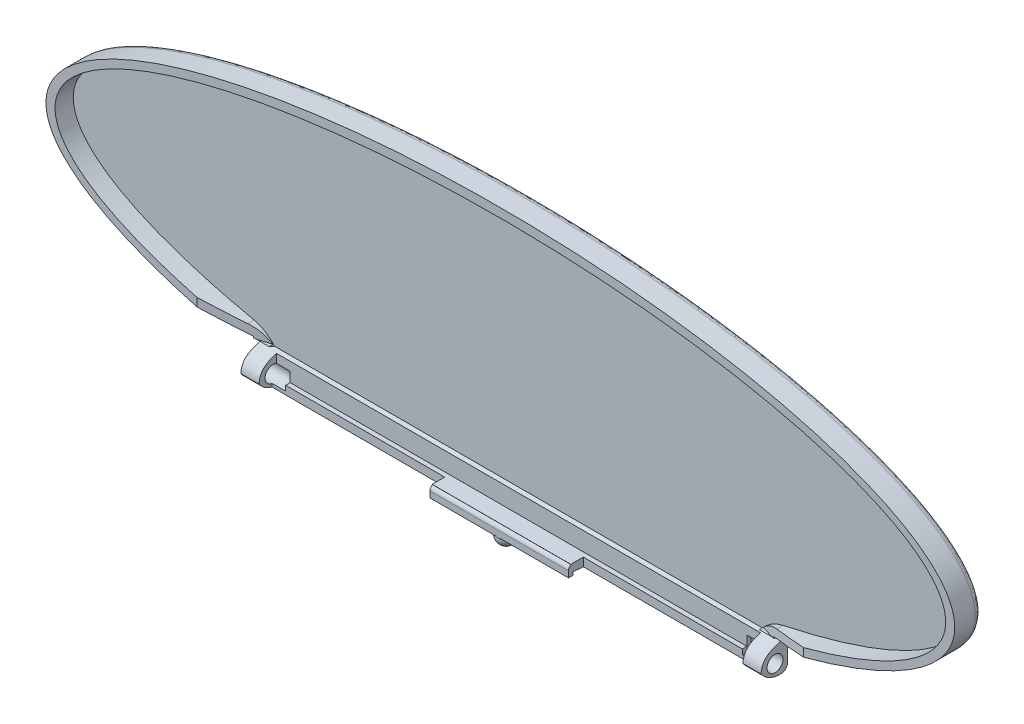
SolidWorks part; units mm, degrees
ref_plane "Front Plane" through (0, 0, 0) normal (0, 0, 1) x (1, 0, 0)
ref_plane "Top Plane" through (0, 0, 0) normal (0, 1, 0) x (1, 0, 0)
ref_plane "Right Plane" through (0, 0, 0) normal (1, 0, 0) x (0, 0, -1)
sketch "Sketch2" plane through (0, 0, 0) normal (0, 0, 1) x (1, 0, 0)
  ellipse E0 centre (0, 0) end of major axis (-100, 0) minor radius 30
extrude "Boss-Extrude1" add sketch "Sketch2" along normal blind 6
sketch "Sketch3" plane through (0, 0, 6) normal (0, 0, 1) x (1, 0, 0)
  ellipse E0 centre (0, 0) end of major axis (-98, 0) minor radius 28
extrude "Cut-Extrude1" cut sketch "Sketch3" against normal blind 4
sketch "Sketch10" plane through (0, 0, 0) normal (0, 0, -1) x (-1, 0, 0)
  line L0 (-57.25, 24.5971) -> (-57.25, -71.2779) construction
  line L1 (0, 3.3) -> (0, -3.3) construction
  line L2 (57.25, 24.5971) -> (57.25, -71.2779) construction
  line L3 (-57.25, -32.5) -> (57.25, -32.5) construction
  line L4 (-57.25, -24.5971) -> (-57.25, -32.5)
  line L5 (-57.25, -32.5) -> (57.25, -32.5)
  line L6 (57.25, -32.5) -> (57.25, -24.5971)
  ellipse E0 centre (0, 0) end of major axis (100, 0) minor radius 30 construction
  ellipse E1 centre (0, 0) end of major axis (100, 0) minor radius 30 (-57.25, -24.5971) -> (57.25, -24.5971) ccw
  point P14 (0, -32.5)
  dimension "D1" = 57.25
  dimension "D2" = 32.5
extrude "Boss-Extrude2" add sketch "Sketch10" against normal blind 9
sketch "Sketch11" plane through (0, 0, 9) normal (0, 0, 1) x (1, 0, 0)
  line L0 (53.25, -30.5) -> (53.25, -20.4997)
  line L1 (53.25, -30.5) -> (-53.25, -30.5)
  line L2 (-53.25, -30.5) -> (-53.25, -20.4997)
  line L3 (-53.25, -20.4997) -> (53.25, -20.4997)
  line L4 (57.25, -24.5971) -> (57.25, -32.5) construction
  line L5 (57.25, -32.5) -> (-57.25, -32.5) construction
  line L6 (-57.25, -32.5) -> (-57.25, -24.5971) construction
  point P10 (-57.25, -28.5486)
  dimension "D1" = 4
  dimension "D2" = 2
  dimension "D3" = 4
extrude "Cut-Extrude2" cut sketch "Sketch11" against normal blind 7
sketch "Sketch12" plane through (-57.25, 0, 0) normal (-1, 0, 0) x (0, 0, 1)
  line L0 (9, -32.5) -> (0, -32.5) construction
  line L1 (0, -32.5) -> (0, -24.5971) construction
  circle A0 centre (2.8, -29.9) radius 1.75
  point P4 (4.5, -32.5)
  dimension "D1" = 3.5
  dimension "D2" = 2.6
  dimension "D3" = 2.8
extrude "Cut-Extrude3" cut sketch "Sketch12" against normal blind 7
mirror "Mirror1" about plane through (0, 0, 0) normal (1, 0, 0) of "Cut-Extrude3"
fillet "Fillet3" radius 1.5 1 edges at (0, 30, 0)
fillet "Fillet4" radius 1.5 1 edges at (0, -32.5, 0)
sketch "Sketch13" [suppressed] plane through (57.25, 0, 0) normal (1, 0, 0) x (0, 0, -1)
  line L0 (-9, -24.5971) -> (-9, -32.5) construction
  line L1 (-9, -28.5486) -> (-9, -24.5971)
  line L2 (-9, -24.5971) -> (-6, -24.5971)
  arc A0 (-9, -28.5486) -> (-6, -24.5971) centre (-6.0161, -27.6994) cw
  line M2 (-9, -24.5971) -> (-9, -32.5)
  line M9 (-6, -24.5971) -> (-9, -24.5971)
extrude "Cut-Extrude5" [suppressed] cut sketch "Sketch13" against normal through all contours A0 M2 M9
sketch "Sketch15" plane through (0, -32.5, 0) normal (0, -1, 0) x (1, 0, 0)
  line L0 (57.25, 9) -> (-57.25, 9) construction
  line L1 (-53.25, 9) -> (-15.25, 9)
  line L2 (-53.25, 9) -> (-53.25, 2.9997)
  line L3 (-53.25, 2.9997) -> (-15.25, 2.9997)
  line L4 (-15.25, 9) -> (-15.25, 2.9997)
  dimension "D1" = 4
  dimension "D2" = 38
extrude "Cut-Extrude6" cut sketch "Sketch15" against normal blind 10
mirror "Mirror2" about plane through (0, 0, 0) normal (1, 0, 0) of "Cut-Extrude6"
sketch "Sketch16" plane through (0, -32.5, 0) normal (0, -1, 0) x (1, 0, 0)
  line L0 (15.25, 2.9997) -> (15.25, 9) construction
  line L1 (-15.25, 9) -> (15.25, 9)
  line L2 (-15.25, 9) -> (-15.25, 6)
  line L3 (-15.25, 6) -> (15.25, 6)
  line L4 (15.25, 9) -> (15.25, 6)
  dimension "D1" = 3
extrude "Cut-Extrude7" cut sketch "Sketch16" against normal blind 10
sketch "Sketch17" plane through (57.25, 0, 0) normal (1, 0, 0) x (0, 0, -1)
  line L0 (-6, -24.5971) -> (-9, -32.5)
  line L1 (-9, -32.5) -> (-1.5, -32.5) construction
  line L2 (-9, -24.5971) -> (-9, -32.5) construction
  line L3 (-9, -32.5) -> (-9, -24.5971)
  line L4 (-9, -24.5971) -> (-6, -24.5971)
extrude "Cut-Extrude9" cut sketch "Sketch17" against normal blind 10
mirror "Mirror3" about plane through (0, 0, 0) normal (1, 0, 0) of "Cut-Extrude9"
fillet "Fillet5" radius 5 1 edges at (-55.25, -32.5, 9)
fillet "Fillet6" [suppressed] radius 3
sketch "Sketch19" [suppressed] plane through (0, -30.5, 0) normal (0, 1, 0) x (1, 0, 0)
  circle A0 centre (0, -3.6834) radius 2
  dimension "D1" = 4
extrude "Boss-Extrude3" [suppressed] add sketch "Sketch19" against normal blind 4
fillet "Fillet2" [suppressed] radius 0.5
sketch "Sketch4" [suppressed] plane through (0, 0, 0) normal (0, 0, -1) x (-1, 0, 0)
  line L0 (0, 0) -> (0, -37.8362) construction
  line L1 (0, 0) -> (0, 38.124) construction
  line L2 (0, 0) -> (-99.5, 0) construction
  line L3 (0, 0) -> (97.6674, 0) construction
  spline S0 degree 3 number of poles 152 (99.5, 0) -> (99.5, 0) construction
sketch "Sketch8" plane through (0, 0, 0) normal (1, 0, 0) x (0, 0, -1)
  line L0 (-6, 30) -> (-22.0184, 30) construction
fillet "Fillet7" [suppressed] radius 2
sketch "Sketch21" plane through (57.25, 0, 0) normal (1, 0, 0) x (0, 0, -1)
  line L1 (-7.2133, -23.3698) -> (-7.5085, -25.9032)
  line L2 (-7.5085, -25.9032) -> (-7.2133, -28.9868)
  line L3 (-7.2133, -28.9868) -> (-5.8692, -30.3397)
  arc A0 (-6.4283, -25.7255) -> (-1.7538, -32.5) centre (-1.7538, -27.5) ccw construction
  spline S0 degree 3 poles (-5.8692, -30.3397) (-5.7581, -28.7997) (-4.7237, -26.9811) (0.2438, -25.9765) (-4.6737, -24.2914) (-6.3458, -25.0967) (-7.2133, -23.3698) knots 0 0 0 0 0.316372 0.502278 0.701708 1 1 1 1
extrude "Cut-Extrude12" cut sketch "Sketch21" against normal blind 128 and the other way through all
sketch "Sketch23" plane through (0, 0, 6) normal (0, 0, 1) x (1, 0, 0)
  line L0 (58.5061, -22.4627) -> (52.5374, -23.5968)
  line L1 (52.5374, -23.5968) -> (52.5374, -27.1021)
  arc A0 (58.5061, -22.4627) -> (52.5374, -27.1021) centre (60.055, -30.6145) ccw
  ellipse E0 centre (0, 0) end of major axis (-98, 0) minor radius 28 (53.25, -23.5059) -> (-53.25, -23.5059) ccw construction
extrude "Cut-Extrude14" cut sketch "Sketch23" against normal blind 4
mirror "Mirror4" about plane through (0, 0, 0) normal (1, 0, 0) of "Cut-Extrude14"
sketch "Sketch24" plane through (15.25, 0, 0) normal (1, 0, 0) x (0, 0, -1)
  line L0 (-2.9997, -30.5) -> (-5.253, -30.5)
  line L1 (-6.253, -31.5) -> (-6.253, -32.8451)
  line L2 (-6.253, -32.8451) -> (-5.3075, -32.8451)
  line L3 (-5.3075, -32.8451) -> (-5.3075, -32.1757)
  line L4 (-5.3075, -32.1757) -> (-2.9997, -32.3423)
  line L5 (-2.9997, -32.3423) -> (-2.9997, -30.5)
  arc A0 (-5.253, -30.5) -> (-6.253, -31.5) centre (-5.253, -31.5) ccw
  dimension "D1" = 1
extrude "Boss-Extrude4" add sketch "Sketch24" against normal up to surface (30.5 mm away) up to face at (-15.25, -31.1924, 3.9701)
sketch "Sketch25" [suppressed] plane through (0, 0, 0) normal (0, 0, 1) x (1, 0, 0)
  line L0 (113.7883, -14.0052) -> (-110.9058, -14.0052)
  line L1 (-110.9058, -14.0052) -> (-110.9058, 56.0094)
  line L2 (-110.9058, 56.0094) -> (113.7883, 56.0094)
  line L3 (113.7883, 56.0094) -> (113.7883, -14.0052)
sketch "Sketch26" plane through (0, -32.3901, 2.3376) normal (0, -0.9974, 0.072) x (1, 0, 0)
  circle A0 centre (-0.4788, 1.8152) radius 2
  dimension "D1" = 4
extrude "Boss-Extrude5" add sketch "Sketch26" along normal blind 3
fillet "Fillet8" radius 2 1 edges at (-0.4788, -35.3956, 2.3693)
extrude "Cut-Extrude16" [suppressed] cut sketch "Sketch25" along normal blind 6
sketch "Sketch27" plane through (0, 0, 0) normal (0, 1, 0) x (1, 0, 0)
  line L5 (66.7378, -6) -> (53.6966, -2)
  line L6 (-98, -6) -> (98, -6) construction
  line L10 (53.6966, -2) -> (53.6966, -8.8641)
  line L11 (53.6966, -8.8641) -> (66.7378, -6)
extrude "Cut-Extrude17" cut sketch "Sketch27" against normal blind 25
mirror "Mirror5" about plane through (0, 0, 0) normal (1, 0, 0) of "Cut-Extrude17"
sketch "Sketch30" [suppressed] plane through (0, 0, 0) normal (0, 0, -1) x (-1, 0, 0)
  text T0 "<r180>ehcsrop</r>" font "911 Porscha" height in points 36
extrude "Cut-Extrude18" [suppressed] cut sketch "Sketch30" against normal blind 1
sketch "Sketch28" plane through (0, 0, 0) normal (0, 0, -1) x (-1, 0, 0)
  line L0 (392.0342, 133.467) -> (419.2437, 133.27)
  line L1 (417.5507, 129.7637) -> (417.0638, 128.6419)
  line L2 (417.0638, 128.6419) -> (415.9843, 126.3771)
  line L3 (415.9843, 126.3771) -> (415.4355, 124.9591)
  line L4 (415.4355, 124.9591) -> (460.9635, 124.7049)
  line L5 (460.9635, 124.7049) -> (466.3754, 124.6202)
  line L6 (469.7477, 130.1871) -> (472.3723, 134.7167)
  line L7 (472.3723, 134.7167) -> (475.759, 140.1989)
  line L8 (475.759, 140.1989) -> (476.3305, 141.2149)
  line L9 (476.3305, 141.2149) -> (483.1038, 152.3909)
  line L10 (491.3697, 166.4128) -> (489.8137, 166.2127)
  line L11 (489.8137, 166.2127) -> (483.6454, 165.1902)
  line L12 (483.6454, 165.1902) -> (483.5763, 165.1754)
  line L13 (483.4931, 165.119) -> (483.4538, 165.0604)
  line L14 (462.8262, 131.9439) -> (462.0028, 130.4618)
  line L15 (462.0028, 130.4618) -> (428.9595, 130.5892)
  line L16 (428.9595, 130.5892) -> (426.2417, 130.6748)
  line L17 (426.2417, 130.6748) -> (427.0122, 132.4096)
  line L18 (427.0122, 132.4096) -> (428.0493, 134.9284)
  line L19 (428.0493, 134.9284) -> (430.0678, 139.1366)
  line L20 (430.0678, 139.1366) -> (430.1151, 139.2362)
  line L21 (429.9281, 139.4346) -> (429.8138, 139.4387)
  line L22 (429.8138, 139.4387) -> (400.3845, 139.8179)
  line L23 (339.488, 131.9439) -> (335.551, 130.6739)
  line L24 (294.2278, 111.376) -> (290.72, 109.0839)
  line L25 (290.72, 109.0839) -> (287.7936, 107.3192)
  line L26 (272.4613, 87.0657) -> (271.6677, 84.4824)
  line L27 (271.5218, 84.4203) -> (271.4659, 84.4452)
  line L28 (271.454, 84.4321) -> (271.4572, 84.4205)
  line L29 (271.4572, 84.4205) -> (271.472, 84.3837)
  line L30 (476.3093, 86.7107) -> (495.3805, 95.7912)
  line L31 (502.1962, 98.7546) -> (506.7893, 100.4267)
  line L32 (506.7893, 100.4267) -> (509.8815, 101.4051)
  line L33 (510.049, 101.4427) -> (510.2069, 101.4528)
  line L34 (510.1659, 101.7832) -> (510.0776, 101.7962)
  line L35 (509.9763, 101.8283) -> (509.8656, 101.8301)
  line L36 (423.6043, 101.7179) -> (415.3282, 101.8026)
  line L37 (348.8264, 101.9874) -> (319.738, 102.0269)
  line L38 (305.3224, 102.0896) -> (292.5839, 102.2254)
  line L39 (292.5839, 102.2254) -> (292.583, 102.2257)
  line L40 (292.583, 102.2257) -> (292.5828, 102.2258)
  line L41 (292.5049, 102.3118) -> (292.5009, 102.3413)
  line L42 (391.7802, 133.4673) -> (392.0342, 133.467)
  line L43 (471.6527, 15.4426) -> (471.6527, 15.4878)
  line L44 (455.8216, 37.5913) -> (455.9355, 42.8784)
  line L45 (455.9868, 43.9316) -> (456.0244, 44.2671)
  line L46 (456.0244, 44.2671) -> (456.0317, 44.8864)
  line L47 (456.0317, 44.8864) -> (380.4667, 22.7451)
  line L48 (353.6908, 16.7972) -> (350.0713, 16.2681)
  line L49 (349.5001, 16.0912) -> (349.5003, 16.0909)
  line L50 (349.5003, 16.0909) -> (349.5006, 16.0907)
  line L51 (349.5301, 16.0867) -> (351.1306, 16.034)
  line L52 (351.1306, 16.034) -> (360.4959, 15.8659)
  line L53 (383.3983, 15.9082) -> (430.4094, 15.8236)
  line L54 (255.1892, 16.0219) -> (256.2504, 16.0219)
  line L55 (281.3129, 15.626) -> (281.3129, 15.6712)
  line L56 (256.1178, 24.1134) -> (254.8859, 24.663)
  line L57 (254.8859, 24.663) -> (252.0456, 26.0008)
  line L58 (225.8945, 102.2316) -> (199.6264, 102.1585)
  line L59 (199.6264, 102.1585) -> (85.8919, 102.3151)
  line L60 (85.8919, 102.3151) -> (34.5822, 102.2243)
  line L61 (34.5822, 102.2243) -> (10.4282, 102.1678)
  line L62 (10.4282, 102.1678) -> (10.3858, 61.9312)
  line L63 (10.3858, 61.9312) -> (10.2588, 15.8832)
  line L64 (10.2588, 15.8832) -> (27.2451, 15.8552)
  line L65 (715.2807, 94.8606) -> (713.8682, 91.8362)
  line L66 (713.8682, 91.8362) -> (713.8267, 91.7224)
  line L67 (713.8261, 91.7142) -> (713.8264, 91.7137)
  line L68 (713.9411, 91.7222) -> (714.0402, 91.7734)
  line L69 (714.0402, 91.7734) -> (717.5823, 93.6435)
  line L70 (737.9162, 101.1694) -> (739.7594, 101.5419)
  line L71 (739.7594, 101.5419) -> (733.7255, 101.535)
  line L72 (733.7255, 101.535) -> (733.6583, 101.54)
  line L73 (733.6583, 101.54) -> (733.6545, 101.5409)
  line L74 (733.613, 101.5574) -> (733.5785, 101.5387)
  line L75 (733.5785, 101.5387) -> (733.571, 101.5359)
  line L76 (733.5588, 101.5374) -> (733.5538, 101.5415)
  line L77 (733.5538, 101.5415) -> (733.5485, 101.5464)
  line L78 (733.4998, 101.5532) -> (733.4411, 101.5429)
  line L79 (732.7575, 101.5332) -> (718.9162, 101.5959)
  line L80 (596.6434, 81.8207) -> (596.0256, 80.9557)
  line L81 (591.7402, 74.308) -> (587.5224, 67.6185)
  line L82 (586.7684, 66.4157) -> (586.3215, 65.1678)
  line L83 (624.136, 49.1176) -> (625.2385, 49.5147)
  line L84 (625.2385, 49.5147) -> (625.7047, 49.6395)
  line L85 (629.6702, 51.1559) -> (633.7422, 52.9255)
  line L86 (633.7422, 52.9255) -> (636.2667, 54.1415)
  line L87 (636.2667, 54.1415) -> (642.7724, 57.7832)
  line L88 (643.1002, 57.9834) -> (643.3127, 58.1518)
  line L89 (668.8963, 79.4754) -> (674.1678, 84.9066)
  line L90 (680.3197, 91.7416) -> (680.7243, 92.2689)
  line L91 (688.5961, 100.9109) -> (689.2971, 101.6054)
  line L92 (681.9676, 101.7248) -> (638.8719, 101.9347)
  line L93 (638.7634, 101.9389) -> (638.704, 101.9519)
  line L94 (637.3922, 101.9688) -> (609.5058, 102.0586)
  line L95 (605.7764, 15.4202) -> (624.5192, 15.3054)
  line L96 (624.5192, 15.3054) -> (624.7732, 15.3071)
  line L97 (624.7732, 15.3071) -> (627.0568, 15.3123)
  line L98 (627.0568, 15.3123) -> (635.3316, 15.2411)
  line L99 (635.3316, 15.2411) -> (638.6754, 21.1946)
  line L100 (638.6754, 21.1946) -> (642.0398, 26.4252)
  line L101 (642.2357, 26.7027) -> (642.4824, 27.0021)
  line L102 (642.4648, 27.2001) -> (642.365, 27.189)
  line L103 (640.976, 26.7495) -> (609.5494, 16.5458)
  line L104 (609.5494, 16.5458) -> (605.7764, 15.4202)
  line L105 (569.5603, 15.2905) -> (569.4894, 15.3621)
  line L106 (569.3348, 15.4419) -> (565.7368, 16.7793)
  line L107 (555.6719, 24.0343) -> (553.6788, 27.8536)
  line L108 (553.6788, 27.8536) -> (552.4828, 29.8679)
  line L109 (529.0036, 19.8821) -> (525.2719, 18.5235)
  line L110 (525.2719, 18.5235) -> (520.5811, 17.0893)
  line L111 (516.8349, 16.1241) -> (516.6845, 16.0742)
  line L112 (516.6668, 16.0656) -> (516.5818, 16.0025)
  line L113 (526.2539, 15.7461) -> (566.8641, 15.4311)
  line L114 (566.8641, 15.4311) -> (569.5603, 15.2905)
  line L115 (554.5965, 102.3141) -> (555.9681, 101.7154)
  line L116 (567.239, 99.3349) -> (567.7287, 99.9465)
  line L117 (569.8478, 102.2865) -> (554.5965, 102.3141)
  line L118 (526.6254, 44.2276) -> (529.1709, 45.4012)
  line L119 (509.6058, 71.4387) -> (509.6064, 71.3014)
  line L120 (509.8478, 39.4657) -> (510.1127, 39.5081)
  line L121 (510.1332, 39.5165) -> (510.1342, 39.5254)
  line L122 (905.8416, 102.1768) -> (905.3345, 102.1668)
  line L123 (905.3345, 102.1668) -> (902.7358, 102.1823)
  line L124 (902.7358, 102.1823) -> (902.7273, 102.1806)
  line L125 (902.7273, 102.1806) -> (902.7246, 102.1797)
  line L126 (903.0616, 101.9882) -> (906.0777, 101.2497)
  line L127 (936.7801, 74.4081) -> (937.1697, 73.9307)
  line L128 (979.7696, 98.3052) -> (983.9394, 99.6387)
  line L129 (983.9394, 99.6387) -> (990.4365, 101.3226)
  line L130 (990.7763, 101.3956) -> (992.5154, 101.673)
  line L131 (992.5273, 101.6783) -> (992.5306, 101.6806)
  line L132 (992.5306, 101.6806) -> (992.5315, 101.6817)
  line L133 (992.2183, 101.8033) -> (991.7102, 101.8401)
  line L134 (985.3153, 101.7977) -> (977.5259, 101.8824)
  line L135 (977.5259, 101.8824) -> (973.9382, 101.8401)
  line L136 (937.4363, 101.9671) -> (906.0249, 102.2199)
  line L137 (930.4909, 56.943) -> (910.193, 57.5786)
  line L138 (909.9966, 57.6889) -> (906.0673, 63.6342)
  line L139 (818.2679, 35.1651) -> (815.4316, 31.8207)
  line L140 (815.4316, 31.8207) -> (813.1456, 29.2384)
  line L141 (803.3878, 16.3267) -> (802.8033, 15.4071)
  line L142 (802.8033, 15.4071) -> (887.5888, 15.3531)
  line L143 (887.5888, 15.3531) -> (924.8282, 15.429)
  line L144 (969.6731, 15.0144) -> (974.0123, 14.8027)
  line L145 (974.0123, 14.8027) -> (973.9699, 14.8662)
  line L146 (973.9653, 14.8707) -> (973.9574, 14.8759)
  line L147 (973.9574, 14.8759) -> (973.6203, 15)
  line L148 (972.2811, 15.306) -> (967.1543, 16.5807)
  line L149 (967.1543, 16.5807) -> (963.8734, 17.4697)
  line L150 (930.7688, 52.8604) -> (930.4909, 56.943)
  line L151 (848.3199, 90.985) -> (851.4573, 92.8866)
  line L152 (870.9729, 101.9882) -> (871.2693, 102.0263)
  line L153 (871.2693, 102.0263) -> (871.2693, 102.0941)
  line L154 (871.2693, 102.0941) -> (854.4477, 102.0087)
  line L155 (854.4477, 102.0087) -> (848.0706, 90.9181)
  line L156 (848.0706, 90.9181) -> (848.1649, 90.9181)
  line L157 (771.3066, 15.4387) -> (775.1203, 21.6689)
  line L158 (775.1203, 21.6689) -> (790.4338, 45.9601)
  line L159 (794.0321, 51.7174) -> (798.3032, 58.1009)
  line L160 (798.3032, 58.1009) -> (798.4428, 58.3286)
  line L161 (798.2164, 58.579) -> (791.0899, 58.7447)
  line L162 (791.0899, 58.7447) -> (776.3563, 58.8717)
  line L163 (775.9244, 58.9415) -> (775.7219, 59.1517)
  line L164 (670.2921, 19.7783) -> (667.8423, 16.4029)
  line L165 (667.8423, 16.4029) -> (667.0768, 15.247)
  line L166 (667.1166, 15.0939) -> (667.1167, 15.0938)
  line L167 (667.1167, 15.0938) -> (667.1169, 15.0937)
  line L168 (667.1169, 15.0937) -> (667.3072, 15.0864)
  line L169 (667.3072, 15.0864) -> (675.4856, 15.0579)
  line L170 (675.4856, 15.0579) -> (684.2512, 15.0852)
  line L171 (1203.0503, 101.756) -> (1202.9795, 101.7836)
  line L172 (1202.9292, 101.7945) -> (1202.8172, 101.7931)
  line L173 (1202.8172, 101.7931) -> (1194.8325, 101.4905)
  line L174 (1194.8325, 101.4905) -> (1194.7618, 101.4826)
  line L175 (1194.7527, 101.4803) -> (1194.6515, 101.4369)
  line L176 (1194.6515, 101.4369) -> (1194.6471, 101.4358)
  line L177 (1194.6471, 101.4358) -> (1194.1308, 101.4206)
  line L178 (1194.1308, 101.4206) -> (1188.7543, 101.3786)
  line L179 (1188.7543, 101.3786) -> (1181.9282, 101.3798)
  line L180 (1181.9282, 101.3798) -> (1178.135, 101.4309)
  line L181 (1177.9263, 101.3428) -> (1177.2143, 99.9818)
  line L182 (1177.2143, 99.9818) -> (1174.2418, 94.1178)
  line L183 (1174.2418, 94.1178) -> (1173.696, 92.8941)
  line L184 (1173.7276, 92.814) -> (1173.8293, 92.8557)
  line L185 (1173.8293, 92.8557) -> (1178.9407, 94.9639)
  line L186 (1178.9407, 94.9639) -> (1182.3387, 96.2393)
  line L187 (1182.3387, 96.2393) -> (1183.478, 96.7139)
  line L188 (1197.7555, 100.7833) -> (1199.4038, 101.1348)
  line L189 (1100.2984, 22.3402) -> (1100.6542, 22.851)
  line L190 (1100.6542, 22.851) -> (1101.0094, 23.4464)
  line L191 (1070.5053, 18.2768) -> (1059.9793, 16.3109)
  line L192 (1057.7381, 15.976) -> (1055.9327, 15.7745)
  line L193 (1055.8348, 15.7494) -> (1055.6726, 15.6668)
  line L194 (1055.6726, 15.6668) -> (1057.35, 15.5284)
  line L195 (1002.7246, 50.2516) -> (994.3573, 52.2007)
  line L196 (974.1815, 62.4889) -> (971.8533, 60.7556)
  line L197 (1007.2439, 33.3447) -> (1008.5213, 33.146)
  line L198 (1148.7641, 101.246) -> (1117.0994, 101.4662)
  line L199 (1117.0994, 101.4662) -> (1097.8682, 101.5563)
  line L200 (1097.8682, 101.5563) -> (1084.4692, 101.5648)
  line L201 (1084.4692, 101.5648) -> (1063.2048, 101.8084)
  line L202 (1063.2048, 101.8084) -> (1058.6339, 101.6458)
  line L203 (1058.6339, 101.6458) -> (1058.6342, 101.6006)
  line L204 (1058.7566, 101.5433) -> (1060.9681, 100.9046)
  line L205 (1030.7269, 48.3831) -> (1024.1658, 48.0066)
  line L206 (1016.4881, 32.0796) -> (1016.4533, 32.0843)
  line L207 (1016.4019, 69.7861) -> (1016.3804, 69.8012)
  line L208 (1016.3804, 69.8012) -> (1017.9689, 69.3664)
  line L209 (1047.9038, 76.9658) -> (1047.9018, 77.2198)
  line L210 (1047.9363, 77.4002) -> (1047.9836, 77.5862)
  line L211 (1001.3173, 78.4285) -> (1000.7669, 78.0051)
  line L212 (1000.3436, 77.73) -> (1000.1445, 77.5359)
  line L213 (1000.1445, 77.5359) -> (1002.7566, 75.9308)
  line L214 (1012.8319, 70.8085) -> (1014.1673, 70.3848)
  line L215 (1014.1673, 70.3848) -> (1014.1673, 70.3845)
  line L216 (1014.1673, 70.3845) -> (1014.1675, 70.3842)
  line L217 (1014.1675, 70.3842) -> (1014.1714, 70.3817)
  line L218 (1014.1714, 70.3817) -> (1014.9864, 70.1562)
  line L219 (1014.9864, 70.1562) -> (1016.4019, 69.7861)
  line L220 (1016.6983, 69.6113) -> (1016.7819, 69.579)
  line L221 (1016.9166, 69.6385) -> (1016.9164, 69.639)
  line L222 (1016.9164, 69.639) -> (1016.9159, 69.6395)
  line L223 (1016.8789, 69.6537) -> (1016.4019, 69.7861)
  line L224 (1402.5526, 15.8463) -> (1411.3057, 15.7817)
  line L225 (1411.3057, 15.7817) -> (1411.5597, 15.7802)
  line L226 (1411.5597, 15.7802) -> (1433.32, 15.7205)
  line L227 (1433.32, 15.7205) -> (1510.0237, 15.8729)
  line L228 (1510.0237, 15.8729) -> (1513.3032, 15.8669)
  line L229 (1513.3032, 15.8669) -> (1513.3732, 15.8651)
  line L230 (1513.3732, 15.8651) -> (1521.0373, 15.8535)
  line L231 (1521.0373, 15.8535) -> (1662.1374, 15.877)
  line L232 (1662.1374, 15.877) -> (1689.7209, 15.9075)
  line L233 (1689.7209, 15.9075) -> (1690.6144, 16.1375)
  line L234 (1690.337, 18.6636) -> (1690.2663, 102.3157)
  line L235 (1690.2663, 102.3157) -> (1498.7305, 102.3517)
  line L236 (1498.7305, 102.3517) -> (1457.6333, 102.2083)
  line L237 (1457.6333, 102.2083) -> (1408.9097, 102.2097)
  line L238 (1408.9097, 102.2097) -> (1408.8392, 102.2069)
  line L239 (1408.7489, 102.1644) -> (1408.7017, 102.112)
  line L240 (1408.7017, 102.112) -> (1396.6585, 87.6046)
  line L241 (1382.7178, 71.0824) -> (1377.8682, 65.0893)
  line L242 (1438.7345, 54.5786) -> (1451.7104, 60.6375)
  line L243 (1452.6749, 60.9255) -> (1452.6615, 60.8472)
  line L244 (1452.6455, 60.7984) -> (1452.1604, 59.7686)
  line L245 (1452.1604, 59.7686) -> (1451.4506, 58.4131)
  line L246 (1451.4506, 58.4131) -> (1450.9905, 57.6056)
  line L247 (1444.1806, 44.5195) -> (1436.7088, 29.9334)
  line L248 (1435.3458, 27.3341) -> (1434.8929, 26.5604)
  line L249 (1434.8929, 26.5604) -> (1434.3006, 25.2983)
  line L250 (1434.3006, 25.2983) -> (1434.2681, 25.2355)
  line L251 (1434.1923, 25.1684) -> (1434.1261, 25.1437)
  line L252 (1413.9204, 18.7614) -> (1405.5534, 16.5656)
  line L253 (1403.4096, 16.152) -> (1402.5999, 15.9147)
  line L254 (1402.5945, 15.9101) -> (1402.5526, 15.8463)
  line L255 (1372.156, 15.9324) -> (1372.1557, 15.9775)
  line L256 (1371.752, 16.1836) -> (1367.8344, 17.5714)
  line L257 (1364.2159, 19.3277) -> (1361.1845, 21.1257)
  line L258 (1360.6025, 21.504) -> (1360.3896, 21.6719)
  line L259 (1360.3896, 21.6719) -> (1358.5824, 22.8236)
  line L260 (1325.8366, 16.7337) -> (1322.9174, 15.9808)
  line L261 (1322.9017, 15.6726) -> (1326.0153, 15.6184)
  line L262 (1326.5241, 15.6324) -> (1326.6883, 15.6601)
  line L263 (1328.5874, 15.689) -> (1348.1553, 15.8613)
  line L264 (1348.1553, 15.8613) -> (1370.1658, 16.0032)
  line L265 (1370.1658, 16.0032) -> (1372.156, 15.9324)
  line L266 (1359.1291, 96.7031) -> (1359.6367, 97.0783)
  line L267 (1359.6367, 97.0783) -> (1363.4459, 100.0328)
  line L268 (1363.4459, 100.0328) -> (1366.3174, 102.0123)
  line L269 (1366.3174, 102.0123) -> (1366.5492, 102.2124)
  line L270 (1357.927, 102.2665) -> (1348.754, 102.2304)
  line L271 (1348.3175, 102.2142) -> (1347.7251, 102.1677)
  line L272 (1347.7251, 102.1677) -> (1346.8637, 102.1715)
  line L273 (1353.6072, 99.4567) -> (1358.8689, 96.7585)
  line L274 (1358.8689, 96.7585) -> (1358.9709, 96.7085)
  line L275 (1322.317, 78.7715) -> (1318.3459, 77.5799)
  line L276 (1318.3459, 77.5799) -> (1315.0125, 76.3445)
  line L277 (1314.3557, 76.0706) -> (1312.1744, 75.0373)
  line L278 (1312.1744, 75.0373) -> (1312.0889, 75.0085)
  line L279 (1311.9592, 75.0285) -> (1311.8442, 75.0541)
  line L280 (1311.8442, 75.0541) -> (1311.6848, 74.9906)
  line L281 (1308.2577, 73.2767) -> (1304.3409, 70.9778)
  line L282 (1304.3409, 70.9778) -> (1303.2902, 70.289)
  line L283 (1267.1007, 79.2005) -> (1270.6428, 81.9879)
  line L284 (1307.8929, 101.5323) -> (1309.0364, 101.8075)
  line L285 (1309.1607, 101.8501) -> (1309.1605, 101.884)
  line L286 (1309.1605, 101.884) -> (1307.9496, 101.9676)
  line L287 (1307.9496, 101.9676) -> (1307.6959, 101.9779)
  line L288 (1307.6959, 101.9779) -> (1285.9805, 102.2092)
  line L289 (1285.9805, 102.2092) -> (1285.8, 102.2045)
  line L290 (1285.8, 102.2045) -> (1285.6969, 102.1631)
  line L291 (1285.6969, 102.1631) -> (1285.4284, 102.1563)
  line L292 (1285.4284, 102.1563) -> (1274.4253, 102.1534)
  line L293 (1274.4253, 102.1534) -> (1262.6225, 102.2114)
  line L294 (1262.6225, 102.2114) -> (1262.6224, 102.2113)
  line L295 (1262.6224, 102.2113) -> (1262.6224, 102.2113)
  line L296 (1262.6224, 102.2113) -> (1262.6222, 102.2109)
  line L297 (1262.6241, 102.1834) -> (1262.6353, 102.1008)
  line L298 (1235.0562, 102.077) -> (1234.9474, 102.0737)
  line L299 (1236.1187, 101.4329) -> (1238.0384, 100.5891)
  line L300 (1243.2043, 97.7294) -> (1244.5448, 96.8297)
  line L301 (1262.9281, 75.6976) -> (1267.1007, 79.2005)
  line L302 (1267.2963, 15.839) -> (1267.4206, 15.8414)
  line L303 (1267.4206, 15.8414) -> (1283.2972, 15.7846)
  line L304 (1283.5496, 15.7611) -> (1283.8478, 15.7447)
  line L305 (1283.8478, 15.7447) -> (1285.7531, 15.7156)
  line L306 (1285.7531, 15.7156) -> (1285.7245, 15.7578)
  line L307 (1285.5884, 15.8144) -> (1280.5348, 17.3305)
  line L308 (1280.5348, 17.3305) -> (1279.0119, 17.8859)
  line L309 (1278.9219, 17.9332) -> (1278.7092, 18.0799)
  line L310 (1278.3986, 18.1957) -> (1277.9879, 18.3078)
  line L311 (1255.4373, 49.0341) -> (1255.4572, 51.3796)
  line L312 (1255.4572, 51.3796) -> (1255.4692, 51.6333)
  line L313 (1255.4692, 51.6333) -> (1255.9628, 58.7443)
  line L314 (1255.9628, 58.7443) -> (1250.0062, 59.0089)
  line L315 (1249.8959, 59.0067) -> (1249.7318, 58.9834)
  line L316 (1248.0947, 59.0239) -> (1235.6556, 59.5)
  line L317 (1235.4363, 59.5924) -> (1235.095, 59.9673)
  line L318 (1154.8947, 48.293) -> (1151.7952, 45.2761)
  line L319 (1141.8608, 34.5176) -> (1137.0581, 28.7862)
  line L320 (1137.0581, 28.7862) -> (1134.9836, 26.0818)
  line L321 (1134.9836, 26.0818) -> (1134.6059, 25.6555)
  line L322 (1128.5744, 17.3533) -> (1127.383, 15.5663)
  line L323 (1159.1026, 15.5316) -> (1180.4353, 15.6322)
  line L324 (1180.4353, 15.6322) -> (1267.0378, 15.8374)
  line L325 (1267.0378, 15.8374) -> (1267.2963, 15.839)
  line L326 (824.5032, 101.8824) -> (820.327, 101.8824)
  line L327 (820.0778, 101.8471) -> (819.7085, 101.7586)
  line L328 (819.164, 101.8753) -> (819.139, 101.858)
  line L329 (819.0969, 101.8449) -> (818.8974, 101.8177)
  line L330 (818.3236, 101.5881) -> (818.3175, 101.7273)
  line L331 (818.275, 101.8471) -> (818.2724, 101.8481)
  line L332 (818.2724, 101.8481) -> (817.9064, 101.8615)
  line L333 (817.9064, 101.8615) -> (814.0628, 101.8845)
  line L334 (814.0628, 101.8845) -> (809.4384, 101.859)
  line L335 (809.4384, 101.859) -> (792.2659, 101.8274)
  line L336 (791.4066, 101.8404) -> (791.0272, 101.8822)
  line L337 (780.7152, 101.923) -> (780.2358, 101.9123)
  line L338 (780.2209, 101.9104) -> (780.1151, 101.8836)
  line L339 (779.9858, 101.872) -> (779.0642, 101.8699)
  line L340 (779.0642, 101.8699) -> (777.7232, 101.9247)
  line L341 (772.0791, 101.7687) -> (771.9777, 101.7434)
  line L342 (773.7484, 101.0408) -> (773.9399, 100.9939)
  line L343 (800.8901, 77.3714) -> (803.3878, 73.3921)
  line L344 (803.3878, 73.3921) -> (805.1151, 70.8078)
  line L345 (805.1151, 70.8078) -> (805.2504, 70.9367)
  line L346 (805.2504, 70.9367) -> (805.255, 70.9422)
  line L347 (805.255, 70.9422) -> (805.6897, 71.6235)
  line L348 (805.6897, 71.6235) -> (810.0312, 78.6386)
  line L349 (810.0312, 78.6386) -> (814.9315, 86.6554)
  line L350 (819.8343, 94.6646) -> (824.5032, 101.8824)
  line L351 (818.5192, 101.5711) -> (818.5199, 101.5797)
  line L352 (1310.0553, 147.7757) -> (1282.8459, 147.9726)
  line L353 (1284.5389, 151.4789) -> (1285.0257, 152.6007)
  line L354 (1285.0257, 152.6007) -> (1286.1052, 154.8656)
  line L355 (1286.1052, 154.8656) -> (1286.6541, 156.2835)
  line L356 (1286.6541, 156.2835) -> (1241.126, 156.5377)
  line L357 (1241.126, 156.5377) -> (1235.7141, 156.6224)
  line L358 (1232.3419, 151.0556) -> (1229.7172, 146.5259)
  line L359 (1229.7172, 146.5259) -> (1226.3305, 141.0437)
  line L360 (1226.3305, 141.0437) -> (1225.759, 140.0277)
  line L361 (1225.759, 140.0277) -> (1218.9857, 128.8517)
  line L362 (1210.7198, 114.8298) -> (1212.2759, 115.0299)
  line L363 (1212.2759, 115.0299) -> (1218.4441, 116.0525)
  line L364 (1218.4441, 116.0525) -> (1218.5132, 116.0672)
  line L365 (1218.5964, 116.1236) -> (1218.6357, 116.1823)
  line L366 (1239.2634, 149.2987) -> (1240.0868, 150.7809)
  line L367 (1240.0868, 150.7809) -> (1273.13, 150.6534)
  line L368 (1273.13, 150.6534) -> (1275.8479, 150.5678)
  line L369 (1275.8479, 150.5678) -> (1275.0774, 148.8331)
  line L370 (1275.0774, 148.8331) -> (1274.0402, 146.3142)
  line L371 (1274.0402, 146.3142) -> (1272.0217, 142.1061)
  line L372 (1272.0217, 142.1061) -> (1271.9745, 142.0064)
  line L373 (1272.1614, 141.808) -> (1272.2757, 141.8039)
  line L374 (1272.2757, 141.8039) -> (1301.705, 141.4247)
  line L375 (1362.6015, 149.2987) -> (1366.5385, 150.5687)
  line L376 (1407.8617, 169.8667) -> (1411.3695, 172.1587)
  line L377 (1411.3695, 172.1587) -> (1414.296, 173.9234)
  line L378 (1429.6283, 194.1769) -> (1430.4219, 196.7602)
  line L379 (1430.5678, 196.8223) -> (1430.6237, 196.7974)
  line L380 (1430.6355, 196.8105) -> (1430.6324, 196.8222)
  line L381 (1430.6324, 196.8222) -> (1430.6176, 196.8589)
  line L382 (1225.7802, 194.5319) -> (1206.709, 185.4514)
  line L383 (1199.8934, 182.4881) -> (1195.3002, 180.8159)
  line L384 (1195.3002, 180.8159) -> (1192.208, 179.8376)
  line L385 (1192.0405, 179.7999) -> (1191.8827, 179.7899)
  line L386 (1191.9237, 179.4595) -> (1192.012, 179.4465)
  line L387 (1192.1132, 179.4144) -> (1192.224, 179.4125)
  line L388 (1278.4852, 179.5247) -> (1286.7614, 179.4401)
  line L389 (1353.2632, 179.2553) -> (1382.3515, 179.2157)
  line L390 (1396.7672, 179.1531) -> (1409.5056, 179.0172)
  line L391 (1409.5056, 179.0172) -> (1409.5066, 179.017)
  line L392 (1409.5066, 179.017) -> (1409.5068, 179.0169)
  line L393 (1409.5847, 178.9309) -> (1409.5887, 178.9013)
  line L394 (1310.3093, 147.7753) -> (1310.0553, 147.7757)
  line L395 (1230.4369, 265.8001) -> (1230.4369, 265.7549)
  line L396 (1246.2679, 243.6513) -> (1246.154, 238.3643)
  line L397 (1246.1027, 237.3111) -> (1246.0652, 236.9755)
  line L398 (1246.0652, 236.9755) -> (1246.0579, 236.3562)
  line L399 (1246.0579, 236.3562) -> (1321.6229, 258.4976)
  line L400 (1348.3987, 264.4454) -> (1352.0182, 264.9746)
  line L401 (1352.5894, 265.1515) -> (1352.5893, 265.1517)
  line L402 (1352.5893, 265.1517) -> (1352.5889, 265.152)
  line L403 (1352.5595, 265.1559) -> (1350.9589, 265.2087)
  line L404 (1350.9589, 265.2087) -> (1341.5936, 265.3767)
  line L405 (1318.6913, 265.3344) -> (1271.6801, 265.4191)
  line L406 (1446.9004, 265.2207) -> (1445.8391, 265.2207)
  line L407 (1420.7767, 265.6166) -> (1420.7767, 265.5715)
  line L408 (1445.9718, 257.1293) -> (1447.2036, 256.5797)
  line L409 (1447.2036, 256.5797) -> (1450.0439, 255.2418)
  line L410 (1476.195, 179.011) -> (1502.4631, 179.0842)
  line L411 (1502.4631, 179.0842) -> (1616.1977, 178.9275)
  line L412 (1616.1977, 178.9275) -> (1667.5074, 179.0183)
  line L413 (1667.5074, 179.0183) -> (1691.6613, 179.0748)
  line L414 (1691.6613, 179.0748) -> (1691.7037, 219.3114)
  line L415 (1691.7037, 219.3114) -> (1691.8307, 265.3595)
  line L416 (1691.8307, 265.3595) -> (1674.8445, 265.3875)
  line L417 (986.8088, 186.382) -> (988.2214, 189.4065)
  line L418 (988.2214, 189.4065) -> (988.2629, 189.5203)
  line L419 (988.2635, 189.5284) -> (988.2632, 189.5289)
  line L420 (988.1485, 189.5204) -> (988.0494, 189.4693)
  line L421 (988.0494, 189.4693) -> (984.5073, 187.5992)
  line L422 (964.1734, 180.0732) -> (962.3301, 179.7008)
  line L423 (962.3301, 179.7008) -> (968.3641, 179.7077)
  line L424 (968.3641, 179.7077) -> (968.4312, 179.7026)
  line L425 (968.4312, 179.7026) -> (968.4351, 179.7017)
  line L426 (968.4766, 179.6852) -> (968.511, 179.704)
  line L427 (968.511, 179.704) -> (968.5186, 179.7067)
  line L428 (968.5308, 179.7053) -> (968.5358, 179.7011)
  line L429 (968.5358, 179.7011) -> (968.5411, 179.6963)
  line L430 (968.5897, 179.6894) -> (968.6484, 179.6997)
  line L431 (969.3321, 179.7094) -> (983.1733, 179.6467)
  line L432 (1105.4461, 199.4219) -> (1106.064, 200.2869)
  line L433 (1110.3493, 206.9346) -> (1114.5671, 213.6241)
  line L434 (1115.3211, 214.827) -> (1115.768, 216.0748)
  line L435 (1077.9536, 232.125) -> (1076.851, 231.728)
  line L436 (1076.851, 231.728) -> (1076.3848, 231.6031)
  line L437 (1072.4193, 230.0868) -> (1068.3473, 228.3171)
  line L438 (1068.3473, 228.3171) -> (1065.8228, 227.1011)
  line L439 (1065.8228, 227.1011) -> (1059.3171, 223.4595)
  line L440 (1058.9893, 223.2592) -> (1058.7769, 223.0909)
  line L441 (1033.1932, 201.7673) -> (1027.9218, 196.3361)
  line L442 (1021.7698, 189.501) -> (1021.3652, 188.9737)
  line L443 (1013.4934, 180.3317) -> (1012.7924, 179.6372)
  line L444 (1020.1219, 179.5179) -> (1063.2177, 179.3079)
  line L445 (1063.3261, 179.3038) -> (1063.3855, 179.2908)
  line L446 (1064.6973, 179.2738) -> (1092.5837, 179.1841)
  line L447 (1096.3131, 265.8224) -> (1077.5703, 265.9372)
  line L448 (1077.5703, 265.9372) -> (1077.3164, 265.9356)
  line L449 (1077.3164, 265.9356) -> (1075.0327, 265.9303)
  line L450 (1075.0327, 265.9303) -> (1066.7579, 266.0016)
  line L451 (1066.7579, 266.0016) -> (1063.4142, 260.048)
  line L452 (1063.4142, 260.048) -> (1060.0498, 254.8175)
  line L453 (1059.8538, 254.5399) -> (1059.6071, 254.2406)
  line L454 (1059.6247, 254.0425) -> (1059.7246, 254.0537)
  line L455 (1061.1135, 254.4932) -> (1092.5402, 264.6969)
  line L456 (1092.5402, 264.6969) -> (1096.3131, 265.8224)
  line L457 (1132.5292, 265.9521) -> (1132.6002, 265.8805)
  line L458 (1132.7548, 265.8008) -> (1136.3527, 264.4633)
  line L459 (1146.4176, 257.2084) -> (1148.4108, 253.3891)
  line L460 (1148.4108, 253.3891) -> (1149.6067, 251.3747)
  line L461 (1173.0859, 261.3606) -> (1176.8176, 262.7192)
  line L462 (1176.8176, 262.7192) -> (1181.5085, 264.1533)
  line L463 (1185.2546, 265.1185) -> (1185.405, 265.1684)
  line L464 (1185.4227, 265.177) -> (1185.5077, 265.2401)
  line L465 (1175.8356, 265.4966) -> (1135.2254, 265.8116)
  line L466 (1135.2254, 265.8116) -> (1132.5292, 265.9521)
  line L467 (1147.493, 178.9285) -> (1146.1215, 179.5272)
  line L468 (1134.8505, 181.9078) -> (1134.3609, 181.2962)
  line L469 (1132.2417, 178.9562) -> (1147.493, 178.9285)
  line L470 (1175.4641, 237.015) -> (1172.9186, 235.8414)
  line L471 (1192.4837, 209.8039) -> (1192.4831, 209.9412)
  line L472 (1192.2417, 241.777) -> (1191.9768, 241.7346)
  line L473 (1191.9563, 241.7262) -> (1191.9554, 241.7172)
  line L474 (796.248, 179.0658) -> (796.755, 179.0758)
  line L475 (796.755, 179.0758) -> (799.3537, 179.0603)
  line L476 (799.3537, 179.0603) -> (799.3623, 179.062)
  line L477 (799.3623, 179.062) -> (799.365, 179.063)
  line L478 (799.0279, 179.2544) -> (796.0119, 179.9929)
  line L479 (765.3094, 206.8346) -> (764.9199, 207.312)
  line L480 (722.3199, 182.9374) -> (718.1501, 181.6039)
  line L481 (718.1501, 181.6039) -> (711.6531, 179.9201)
  line L482 (711.3133, 179.8471) -> (709.5741, 179.5697)
  line L483 (709.5622, 179.5643) -> (709.559, 179.562)
  line L484 (709.559, 179.562) -> (709.5581, 179.561)
  line L485 (709.8713, 179.4394) -> (710.3794, 179.4026)
  line L486 (716.7743, 179.4449) -> (724.5636, 179.3603)
  line L487 (724.5636, 179.3603) -> (728.1514, 179.4026)
  line L488 (764.6533, 179.2756) -> (796.0646, 179.0228)
  line L489 (771.5986, 224.2997) -> (791.8966, 223.664)
  line L490 (792.093, 223.5537) -> (796.0223, 217.6084)
  line L491 (883.8216, 246.0776) -> (886.6579, 249.4219)
  line L492 (886.6579, 249.4219) -> (888.9439, 252.0043)
  line L493 (898.7018, 264.9159) -> (899.2862, 265.8356)
  line L494 (899.2862, 265.8356) -> (814.5008, 265.8896)
  line L495 (814.5008, 265.8896) -> (777.2614, 265.8136)
  line L496 (732.4164, 266.2283) -> (728.0773, 266.4399)
  line L497 (728.0773, 266.4399) -> (728.1196, 266.3764)
  line L498 (728.1243, 266.372) -> (728.1321, 266.3667)
  line L499 (728.1321, 266.3667) -> (728.4692, 266.2426)
  line L500 (729.8084, 265.9367) -> (734.9353, 264.6619)
  line L501 (734.9353, 264.6619) -> (738.2161, 263.7729)
  line L502 (771.3208, 228.3823) -> (771.5986, 224.2997)
  line L503 (853.7696, 190.2576) -> (850.6323, 188.3561)
  line L504 (831.1166, 179.2544) -> (830.8203, 179.2163)
  line L505 (830.8203, 179.2163) -> (830.8203, 179.1486)
  line L506 (830.8203, 179.1486) -> (847.6418, 179.2339)
  line L507 (847.6418, 179.2339) -> (854.0189, 190.3246)
  line L508 (854.0189, 190.3246) -> (853.9246, 190.3246)
  line L509 (930.7829, 265.8039) -> (926.9692, 259.5738)
  line L510 (926.9692, 259.5738) -> (911.6558, 235.2826)
  line L511 (908.0574, 229.5253) -> (903.7864, 223.1417)
  line L512 (903.7864, 223.1417) -> (903.6468, 222.9141)
  line L513 (903.8731, 222.6636) -> (910.9996, 222.4979)
  line L514 (910.9996, 222.4979) -> (925.7333, 222.3709)
  line L515 (926.1652, 222.3012) -> (926.3676, 222.091)
  line L516 (1031.7974, 261.4644) -> (1034.2472, 264.8397)
  line L517 (1034.2472, 264.8397) -> (1035.0127, 265.9957)
  line L518 (1034.973, 266.1487) -> (1034.9728, 266.1488)
  line L519 (1034.9728, 266.1488) -> (1034.9726, 266.149)
  line L520 (1034.9726, 266.149) -> (1034.7824, 266.1563)
  line L521 (1034.7824, 266.1563) -> (1026.604, 266.1848)
  line L522 (1026.604, 266.1848) -> (1017.8384, 266.1575)
  line L523 (499.0392, 179.4867) -> (499.1101, 179.459)
  line L524 (499.1603, 179.4481) -> (499.2723, 179.4495)
  line L525 (499.2723, 179.4495) -> (507.257, 179.7521)
  line L526 (507.257, 179.7521) -> (507.3277, 179.76)
  line L527 (507.3368, 179.7623) -> (507.4381, 179.8058)
  line L528 (507.4381, 179.8058) -> (507.4425, 179.8068)
  line L529 (507.4425, 179.8068) -> (507.9588, 179.822)
  line L530 (507.9588, 179.822) -> (513.3353, 179.864)
  line L531 (513.3353, 179.864) -> (520.1613, 179.8629)
  line L532 (520.1613, 179.8629) -> (523.9545, 179.8118)
  line L533 (524.1632, 179.8999) -> (524.8753, 181.2609)
  line L534 (524.8753, 181.2609) -> (527.8477, 187.1248)
  line L535 (527.8477, 187.1248) -> (528.3936, 188.3485)
  line L536 (528.3619, 188.4286) -> (528.2602, 188.3869)
  line L537 (528.2602, 188.3869) -> (523.1488, 186.2787)
  line L538 (523.1488, 186.2787) -> (519.7508, 185.0034)
  line L539 (519.7508, 185.0034) -> (518.6115, 184.5288)
  line L540 (504.3341, 180.4593) -> (502.6858, 180.1078)
  line L541 (601.7912, 258.9025) -> (601.4353, 258.3917)
  line L542 (601.4353, 258.3917) -> (601.0801, 257.7963)
  line L543 (631.5843, 262.9658) -> (642.1103, 264.9317)
  line L544 (644.3514, 265.2667) -> (646.1569, 265.4681)
  line L545 (646.2547, 265.4932) -> (646.4169, 265.5759)
  line L546 (646.4169, 265.5759) -> (644.7395, 265.7142)
  line L547 (699.365, 230.9911) -> (707.7322, 229.042)
  line L548 (727.908, 218.7537) -> (730.2363, 220.4871)
  line L549 (694.8456, 247.8979) -> (693.5682, 248.0967)
  line L550 (553.3254, 179.9967) -> (584.9901, 179.7765)
  line L551 (584.9901, 179.7765) -> (604.2213, 179.6864)
  line L552 (604.2213, 179.6864) -> (617.6203, 179.6778)
  line L553 (617.6203, 179.6778) -> (638.8848, 179.4343)
  line L554 (638.8848, 179.4343) -> (643.4557, 179.5968)
  line L555 (643.4557, 179.5968) -> (643.4553, 179.642)
  line L556 (643.333, 179.6994) -> (641.1214, 180.338)
  line L557 (671.3626, 232.8595) -> (677.9238, 233.2361)
  line L558 (685.6014, 249.1631) -> (685.6362, 249.1584)
  line L559 (685.6876, 211.4565) -> (685.7091, 211.4414)
  line L560 (685.7091, 211.4414) -> (684.1206, 211.8763)
  line L561 (654.1857, 204.2769) -> (654.1877, 204.0229)
  line L562 (654.1533, 203.8424) -> (654.1059, 203.6565)
  line L563 (700.7723, 202.8142) -> (701.3226, 203.2375)
  line L564 (701.7459, 203.5127) -> (701.945, 203.7068)
  line L565 (701.945, 203.7068) -> (699.3329, 205.3119)
  line L566 (689.2576, 210.4342) -> (687.9223, 210.8578)
  line L567 (687.9223, 210.8578) -> (687.9222, 210.8581)
  line L568 (687.9222, 210.8581) -> (687.922, 210.8584)
  line L569 (687.922, 210.8584) -> (687.9181, 210.8609)
  line L570 (687.9181, 210.8609) -> (687.1032, 211.0864)
  line L571 (687.1032, 211.0864) -> (685.6876, 211.4565)
  line L572 (685.3912, 211.6314) -> (685.3076, 211.6636)
  line L573 (685.173, 211.6041) -> (685.1732, 211.6037)
  line L574 (685.1732, 211.6037) -> (685.1736, 211.6032)
  line L575 (685.2107, 211.5889) -> (685.6876, 211.4565)
  line L576 (299.5369, 265.3963) -> (290.7838, 265.461)
  line L577 (290.7838, 265.461) -> (290.5298, 265.4625)
  line L578 (290.5298, 265.4625) -> (268.7696, 265.5222)
  line L579 (268.7696, 265.5222) -> (192.0658, 265.3697)
  line L580 (192.0658, 265.3697) -> (188.7864, 265.3757)
  line L581 (188.7864, 265.3757) -> (188.7163, 265.3775)
  line L582 (188.7163, 265.3775) -> (181.0523, 265.3891)
  line L583 (181.0523, 265.3891) -> (39.9521, 265.3657)
  line L584 (39.9521, 265.3657) -> (12.3687, 265.3352)
  line L585 (12.3687, 265.3352) -> (11.4751, 265.1051)
  line L586 (11.7526, 262.5791) -> (11.8233, 178.9269)
  line L587 (11.8233, 178.9269) -> (203.3591, 178.891)
  line L588 (203.3591, 178.891) -> (244.4563, 179.0343)
  line L589 (244.4563, 179.0343) -> (293.1799, 179.0329)
  line L590 (293.1799, 179.0329) -> (293.2503, 179.0358)
  line L591 (293.3407, 179.0782) -> (293.3878, 179.1307)
  line L592 (293.3878, 179.1307) -> (305.431, 193.6381)
  line L593 (319.3717, 210.1602) -> (324.2213, 216.1534)
  line L594 (263.355, 226.6641) -> (250.3791, 220.6052)
  line L595 (249.4146, 220.3172) -> (249.4281, 220.3954)
  line L596 (249.444, 220.4442) -> (249.9292, 221.4741)
  line L597 (249.9292, 221.4741) -> (250.6389, 222.8295)
  line L598 (250.6389, 222.8295) -> (251.099, 223.6371)
  line L599 (257.909, 236.7232) -> (265.3807, 251.3093)
  line L600 (266.7438, 253.9085) -> (267.1966, 254.6822)
  line L601 (267.1966, 254.6822) -> (267.7889, 255.9443)
  line L602 (267.7889, 255.9443) -> (267.8214, 256.0071)
  line L603 (267.8972, 256.0743) -> (267.9635, 256.099)
  line L604 (288.1691, 262.4813) -> (296.5362, 264.6771)
  line L605 (298.68, 265.0907) -> (299.4897, 265.3279)
  line L606 (299.495, 265.3325) -> (299.5369, 265.3963)
  line L607 (329.9336, 265.3103) -> (329.9339, 265.2651)
  line L608 (330.3375, 265.0591) -> (334.2552, 263.6712)
  line L609 (337.8736, 261.915) -> (340.9051, 260.1169)
  line L610 (341.4871, 259.7386) -> (341.6999, 259.5707)
  line L611 (341.6999, 259.5707) -> (343.5071, 258.419)
  line L612 (376.2529, 264.5089) -> (379.1722, 265.2618)
  line L613 (379.1878, 265.57) -> (376.0742, 265.6243)
  line L614 (375.5655, 265.6103) -> (375.4012, 265.5825)
  line L615 (373.5021, 265.5536) -> (353.9343, 265.3814)
  line L616 (353.9343, 265.3814) -> (331.9238, 265.2394)
  line L617 (331.9238, 265.2394) -> (329.9336, 265.3103)
  line L618 (342.9605, 184.5395) -> (342.4528, 184.1644)
  line L619 (342.4528, 184.1644) -> (338.6436, 181.2099)
  line L620 (338.6436, 181.2099) -> (335.7722, 179.2303)
  line L621 (335.7722, 179.2303) -> (335.5403, 179.0303)
  line L622 (344.1625, 178.9761) -> (353.3355, 179.0122)
  line L623 (353.7721, 179.0285) -> (354.3644, 179.0749)
  line L624 (354.3644, 179.0749) -> (355.2259, 179.0711)
  line L625 (348.4824, 181.786) -> (343.2206, 184.4842)
  line L626 (343.2206, 184.4842) -> (343.1186, 184.5341)
  line L627 (379.7725, 202.4711) -> (383.7437, 203.6628)
  line L628 (383.7437, 203.6628) -> (387.0771, 204.8982)
  line L629 (387.7338, 205.1721) -> (389.9151, 206.2054)
  line L630 (389.9151, 206.2054) -> (390.0006, 206.2342)
  line L631 (390.1303, 206.2142) -> (390.2453, 206.1885)
  line L632 (390.2453, 206.1885) -> (390.4047, 206.252)
  line L633 (393.8318, 207.966) -> (397.7487, 210.2649)
  line L634 (397.7487, 210.2649) -> (398.7993, 210.9537)
  line L635 (434.9888, 202.0422) -> (431.4467, 199.2548)
  line L636 (394.1966, 179.7103) -> (393.0531, 179.4352)
  line L637 (392.9288, 179.3926) -> (392.9291, 179.3587)
  line L638 (392.9291, 179.3587) -> (394.1399, 179.2751)
  line L639 (394.1399, 179.2751) -> (394.3936, 179.2648)
  line L640 (394.3936, 179.2648) -> (416.109, 179.0334)
  line L641 (416.109, 179.0334) -> (416.2895, 179.0382)
  line L642 (416.2895, 179.0382) -> (416.3927, 179.0795)
  line L643 (416.3927, 179.0795) -> (416.6611, 179.0863)
  line L644 (416.6611, 179.0863) -> (427.6642, 179.0893)
  line L645 (427.6642, 179.0893) -> (439.467, 179.0313)
  line L646 (439.467, 179.0313) -> (439.4671, 179.0313)
  line L647 (439.4671, 179.0313) -> (439.4672, 179.0314)
  line L648 (439.4672, 179.0314) -> (439.4673, 179.0317)
  line L649 (439.4654, 179.0592) -> (439.4542, 179.1419)
  line L650 (467.0334, 179.1657) -> (467.1422, 179.169)
  line L651 (465.9708, 179.8098) -> (464.0512, 180.6535)
  line L652 (458.8852, 183.5132) -> (457.5447, 184.413)
  line L653 (439.1615, 205.545) -> (434.9888, 202.0422)
  line L654 (434.7932, 265.4037) -> (434.669, 265.4012)
  line L655 (434.669, 265.4012) -> (418.7923, 265.4581)
  line L656 (418.5399, 265.4816) -> (418.2417, 265.4979)
  line L657 (418.2417, 265.4979) -> (416.3365, 265.5271)
  line L658 (416.3365, 265.5271) -> (416.365, 265.4849)
  line L659 (416.5011, 265.4282) -> (421.5548, 263.9121)
  line L660 (421.5548, 263.9121) -> (423.0777, 263.3568)
  line L661 (423.1677, 263.3094) -> (423.3803, 263.1627)
  line L662 (423.691, 263.0469) -> (424.1016, 262.9349)
  line L663 (446.6522, 232.2086) -> (446.6323, 229.863)
  line L664 (446.6323, 229.863) -> (446.6204, 229.6093)
  line L665 (446.6204, 229.6093) -> (446.1267, 222.4983)
  line L666 (446.1267, 222.4983) -> (452.0833, 222.2337)
  line L667 (452.1936, 222.236) -> (452.3577, 222.2592)
  line L668 (453.9949, 222.2188) -> (466.4339, 221.7427)
  line L669 (466.6532, 221.6503) -> (466.9945, 221.2754)
  line L670 (547.1948, 232.9496) -> (550.2944, 235.9665)
  line L671 (560.2288, 246.725) -> (565.0314, 252.4564)
  line L672 (565.0314, 252.4564) -> (567.1059, 255.1609)
  line L673 (567.1059, 255.1609) -> (567.4836, 255.5871)
  line L674 (573.5151, 263.8894) -> (574.7065, 265.6764)
  line L675 (542.987, 265.7111) -> (521.6543, 265.6105)
  line L676 (521.6543, 265.6105) -> (435.0518, 265.4052)
  line L677 (435.0518, 265.4052) -> (434.7932, 265.4037)
  line L678 (877.5863, 179.3603) -> (881.7625, 179.3603)
  line L679 (882.0118, 179.3955) -> (882.381, 179.4841)
  line L680 (882.9255, 179.3673) -> (882.9506, 179.3846)
  line L681 (882.9926, 179.3977) -> (883.1921, 179.425)
  line L682 (883.7659, 179.6545) -> (883.772, 179.5154)
  line L683 (883.8145, 179.3956) -> (883.8171, 179.3946)
  line L684 (883.8171, 179.3946) -> (884.1831, 179.3811)
  line L685 (884.1831, 179.3811) -> (888.0267, 179.3581)
  line L686 (888.0267, 179.3581) -> (892.6512, 179.3837)
  line L687 (892.6512, 179.3837) -> (909.8237, 179.4153)
  line L688 (910.6829, 179.4023) -> (911.0623, 179.3604)
  line L689 (921.3744, 179.3197) -> (921.8538, 179.3304)
  line L690 (921.8687, 179.3323) -> (921.9745, 179.359)
  line L691 (922.1038, 179.3707) -> (923.0254, 179.3727)
  line L692 (923.0254, 179.3727) -> (924.3664, 179.3179)
  line L693 (930.0104, 179.4739) -> (930.1119, 179.4993)
  line L694 (928.3411, 180.2018) -> (928.1496, 180.2487)
  line L695 (901.1994, 203.8713) -> (898.7018, 207.8506)
  line L696 (898.7018, 207.8506) -> (896.9745, 210.4349)
  line L697 (896.9745, 210.4349) -> (896.8391, 210.3059)
  line L698 (896.8391, 210.3059) -> (896.8346, 210.3005)
  line L699 (896.8346, 210.3005) -> (896.3998, 209.6192)
  line L700 (896.3998, 209.6192) -> (892.0583, 202.6041)
  line L701 (892.0583, 202.6041) -> (887.1581, 194.5872)
  line L702 (882.2553, 186.5781) -> (877.5863, 179.3603)
  line L703 (883.5703, 179.6716) -> (883.5697, 179.663)
  arc A0 (419.2437, 133.27) -> (417.5507, 129.7637) centre (519.2371, 82.8268) ccw
  arc A1 (466.3754, 124.6202) -> (469.7477, 130.1871) centre (144.7913, 323.2352) ccw
  arc A2 (483.1038, 152.3909) -> (491.3697, 166.4128) centre (-1266.3696, 1193.1485) ccw
  arc A3 (483.5763, 165.1754) -> (483.5298, 165.1545) centre (483.6186, 165.0187) ccw
  arc A4 (483.5298, 165.1545) -> (483.4931, 165.119) centre (483.623, 165.0217) ccw
  arc A5 (469.6904, 142.9035) -> (483.4538, 165.0604) centre (-481.4079, 749.0598) ccw
  arc A6 (469.6904, 142.9035) -> (462.8262, 131.9439) centre (1021.891, -210.5816) ccw
  arc A7 (430.1151, 139.2362) -> (430.1265, 139.276) centre (429.9996, 139.291) ccw
  arc A8 (430.1265, 139.276) -> (430.0987, 139.362) centre (430.0264, 139.2911) ccw
  arc A9 (430.0987, 139.362) -> (429.99, 139.421) centre (429.9246, 139.1708) ccw
  arc A10 (429.99, 139.421) -> (429.9281, 139.4346) centre (429.9025, 139.1707) ccw
  arc A11 (400.3845, 139.8179) -> (383.5289, 139.6728) centre (394.3208, -134.9621) ccw
  arc A12 (383.5289, 139.6728) -> (367.0893, 138.1034) centre (391.7364, -33.1847) ccw
  arc A13 (367.0893, 138.1034) -> (351.172, 135.0766) centre (392.3054, -37.8666) ccw
  arc A14 (351.172, 135.0766) -> (339.488, 131.9439) centre (494.5001, -422.8554) ccw
  arc A15 (335.551, 130.6739) -> (322.216, 125.6574) centre (412.9496, -95.3012) ccw
  arc A16 (322.216, 125.6574) -> (312.6063, 121.4241) centre (429.9183, -131.8503) ccw
  arc A17 (312.6063, 121.4241) -> (302.023, 115.9207) centre (564.9532, -376.7871) ccw
  arc A18 (302.023, 115.9207) -> (294.2278, 111.376) centre (458.961, -162.215) ccw
  arc A19 (287.7936, 107.3192) -> (284.9627, 105.1681) centre (301.2577, 86.6626) ccw
  arc A20 (284.9627, 105.1681) -> (280.3695, 100.7442) centre (330.4304, 53.3634) ccw
  arc A21 (280.3695, 100.7442) -> (277.1733, 96.5956) centre (364.2705, 32.8006) ccw
  arc A22 (277.1733, 96.5956) -> (272.9823, 88.5311) centre (306.6457, 76.158) ccw
  arc A23 (272.9823, 88.5311) -> (272.4613, 87.0657) centre (287.7353, 82.4596) ccw
  arc A24 (271.6488, 84.4459) -> (271.6677, 84.4824) centre (271.4638, 84.5645) ccw
  arc A25 (271.6218, 84.4153) -> (271.6488, 84.4459) centre (271.523, 84.5301) ccw
  arc A26 (271.5853, 84.4036) -> (271.6218, 84.4153) centre (271.5889, 84.455) ccw
  arc A27 (271.5218, 84.4203) -> (271.5853, 84.4036) centre (271.6034, 84.601) ccw
  arc A28 (271.4659, 84.4452) -> (271.4596, 84.4461) centre (271.46, 84.4254) ccw
  arc A29 (271.4596, 84.4461) -> (271.4555, 84.4445) centre (271.4596, 84.4398) ccw
  arc A30 (271.4555, 84.4445) -> (271.4535, 84.44) centre (271.4607, 84.4396) ccw
  arc A31 (271.4535, 84.44) -> (271.454, 84.4321) centre (271.4803, 84.4378) ccw
  arc A32 (271.5393, 84.2255) -> (271.472, 84.3837) centre (270.5211, 83.8853) ccw
  arc A33 (271.543, 84.0141) -> (271.5393, 84.2255) centre (270.8768, 84.1082) ccw
  arc A34 (271.2043, 82.3716) -> (271.543, 84.0141) centre (252.5781, 87.0684) ccw
  arc A35 (271.2043, 82.3716) -> (270.8121, 76.909) centre (295.1055, 77.91) ccw
  arc A36 (270.8121, 76.909) -> (271.5007, 71.2379) centre (297.1356, 77.2278) ccw
  arc A37 (271.5007, 71.2379) -> (276.0727, 62.8136) centre (291.3333, 76.5485) ccw
  arc A38 (276.0727, 62.8136) -> (281.7474, 58.4693) centre (292.1338, 77.915) ccw
  arc A39 (281.7474, 58.4693) -> (288.6033, 55.7651) centre (299.7171, 93.9843) ccw
  arc A40 (288.6033, 55.7651) -> (301.642, 52.3784) centre (329.1439, 185.0538) ccw
  arc A41 (301.642, 52.3784) -> (328.3755, 49.6056) centre (329.7565, 193.1782) ccw
  arc A42 (328.3755, 49.6056) -> (358.3687, 51.2142) centre (330.5423, 289.6147) ccw
  arc A43 (358.3687, 51.2142) -> (398.5007, 58.7284) centre (330.365, 311.7044) ccw
  arc A44 (398.5007, 58.7284) -> (411.2853, 62.4114) centre (212.0702, 729.9085) ccw
  arc A45 (411.2853, 62.4114) -> (450.3167, 75.7464) centre (149.7012, 891.8537) ccw
  arc A46 (450.3167, 75.7464) -> (476.3093, 86.7107) centre (258.1786, 567.5313) ccw
  arc A47 (502.1962, 98.7546) -> (495.3805, 95.7912) centre (585.1358, -101.3271) ccw
  arc A48 (510.049, 101.4427) -> (509.8815, 101.4051) centre (510.2427, 100.1896) ccw
  arc A49 (510.2069, 101.4528) -> (510.3222, 101.4786) centre (510.1797, 101.845) ccw
  arc A50 (510.3222, 101.4786) -> (510.3577, 101.5029) centre (510.2803, 101.5778) ccw
  arc A51 (510.3577, 101.5029) -> (510.3751, 101.5377) centre (510.3076, 101.5496) ccw
  arc A52 (510.3751, 101.5377) -> (510.3718, 101.5852) centre (510.267, 101.5541) ccw
  arc A53 (510.3718, 101.5852) -> (510.3453, 101.6476) centre (510.1009, 101.5073) ccw
  arc A54 (510.3453, 101.6476) -> (510.2863, 101.7336) centre (509.981, 101.4608) ccw
  arc A55 (510.2863, 101.7336) -> (510.231, 101.7705) centre (510.1838, 101.64) ccw
  arc A56 (510.231, 101.7705) -> (510.1659, 101.7832) centre (510.1425, 101.4881) ccw
  arc A57 (510.0196, 101.8161) -> (510.0776, 101.7962) centre (510.1167, 102.0049) ccw
  arc A58 (510.0196, 101.8161) -> (509.9763, 101.8283) centre (509.9724, 101.7317) ccw
  arc A59 (423.6043, 101.7179) -> (509.8656, 101.8301) centre (452.2249, 11258.1271) ccw
  arc A60 (415.3282, 101.8026) -> (367.5041, 101.9483) centre (363.9951, -8894.3625) ccw
  arc A61 (348.8264, 101.9874) -> (367.5041, 101.9483) centre (361.0007, 1458.5568) ccw
  arc A62 (319.738, 102.0269) -> (318.3637, 102.0142) centre (319.5754, 45.146) ccw
  arc A63 (305.3224, 102.0896) -> (318.3637, 102.0142) centre (319.7339, 1468.4838) ccw
  arc A64 (292.5827, 102.2259) -> (292.5796, 102.242) centre (292.5036, 102.2191) ccw
  arc A65 (292.5796, 102.242) -> (292.57, 102.2555) centre (292.5534, 102.2336) ccw
  arc A66 (292.57, 102.2555) -> (292.558, 102.2621) centre (292.5348, 102.2055) ccw
  arc A67 (292.516, 102.2862) -> (292.558, 102.2621) centre (292.6017, 102.3869) ccw
  arc A68 (292.5049, 102.3118) -> (292.516, 102.2862) centre (292.5643, 102.3224) ccw
  arc A69 (292.5022, 102.359) -> (292.5009, 102.3413) centre (292.5413, 102.3471) ccw
  arc A70 (292.5144, 102.3783) -> (292.5022, 102.359) centre (292.5562, 102.3386) ccw
  arc A71 (292.5961, 102.4506) -> (292.5144, 102.3783) centre (293.0872, 101.8133) ccw
  arc A72 (298.594, 107.0307) -> (292.5961, 102.4506) centre (395.0466, -25.4965) ccw
  arc A73 (311.2093, 114.3121) -> (298.594, 107.0307) centre (353.3561, 26.7212) ccw
  arc A74 (340.25, 125.4034) -> (311.2093, 114.3121) centre (397.4615, -67.9591) ccw
  arc A75 (362.043, 130.5648) -> (340.25, 125.4034) centre (400.2783, -79.465) ccw
  arc A76 (384.1073, 133.2562) -> (362.043, 130.5648) centre (395.0047, -47.8667) ccw
  arc A77 (391.7802, 133.4673) -> (384.1073, 133.2562) centre (391.5336, 2.8806) ccw
  arc A78 (471.6527, 15.4878) -> (471.6492, 15.5014) centre (471.6285, 15.489) ccw
  arc A79 (471.6492, 15.5014) -> (471.634, 15.5153) centre (471.6091, 15.4726) ccw
  arc A80 (471.634, 15.5153) -> (471.5375, 15.5638) centre (471.18, 14.7323) ccw
  arc A81 (467.16, 17.8037) -> (471.5375, 15.5638) centre (487.8622, 52.8654) ccw
  arc A82 (463.3342, 20.8189) -> (467.16, 17.8037) centre (480.5091, 38.6763) ccw
  arc A83 (456.2645, 33.3496) -> (463.3342, 20.8189) centre (478.8163, 37.8134) ccw
  arc A84 (455.8216, 37.5913) -> (456.2645, 33.3496) centre (486.9027, 38.6924) ccw
  arc A85 (455.9868, 43.9316) -> (455.9355, 42.8784) centre (476.4276, 42.4089) ccw
  arc A86 (362.6443, 18.4482) -> (380.4667, 22.7451) centre (303.3126, 303.6545) ccw
  arc A87 (353.6908, 16.7972) -> (362.6443, 18.4482) centre (299.1472, 337.695) ccw
  arc A88 (350.0713, 16.2681) -> (349.6101, 16.1824) centre (350.6328, 11.959) ccw
  arc A89 (349.6101, 16.1824) -> (349.5567, 16.1632) centre (349.7211, 15.7911) ccw
  arc A90 (349.5567, 16.1632) -> (349.5225, 16.1424) centre (349.614, 16.0303) ccw
  arc A91 (349.5225, 16.1424) -> (349.5001, 16.0912) centre (349.5592, 16.0958) ccw
  arc A92 (349.5006, 16.0907) -> (349.5301, 16.0867) centre (349.5388, 16.263) ccw
  arc A93 (383.3983, 15.9082) -> (360.4959, 15.8659) centre (375.763, -2048.1149) ccw
  arc A94 (471.6527, 15.4426) -> (430.4094, 15.8236) centre (329.2281, -13169.5411) ccw
  arc A95 (281.3129, 15.626) -> (256.2504, 16.0219) centre (260.7065, -495.3276) ccw
  arc A96 (281.3129, 15.6712) -> (281.3093, 15.6844) centre (281.292, 15.6725) ccw
  arc A97 (281.3093, 15.6844) -> (281.2931, 15.6961) centre (281.2773, 15.6572) ccw
  arc A98 (281.2931, 15.6961) -> (281.1913, 15.7305) centre (280.972, 14.9148) ccw
  arc A99 (263.9562, 20.96) -> (281.1913, 15.7305) centre (394.3228, 419.6004) ccw
  arc A100 (256.1178, 24.1134) -> (263.9562, 20.96) centre (292.9166, 104.2662) ccw
  arc A101 (233.5862, 40.0567) -> (252.0456, 26.0008) centre (279.8275, 81.6356) ccw
  arc A102 (222.7994, 58.5601) -> (233.5862, 40.0567) centre (273.664, 75.8164) ccw
  arc A103 (220.098, 79.8416) -> (222.7994, 58.5601) centre (274.8159, 75.9752) ccw
  arc A104 (225.8945, 102.2316) -> (220.098, 79.8416) centre (284.4055, 75.1385) ccw
  arc A105 (122.6452, 15.9067) -> (27.2451, 15.8552) centre (82.6572, -14274.0942) ccw
  arc A106 (122.6452, 15.9067) -> (200.5194, 15.9523) centre (148.3673, 22575.0713) ccw
  arc A107 (255.1892, 16.0219) -> (200.5194, 15.9523) centre (231.0321, -2478.4496) ccw
  arc A108 (715.2807, 94.8606) -> (718.9162, 101.5959) centre (317.0525, 314.1622) ccw
  arc A109 (713.8267, 91.7224) -> (713.8258, 91.716) centre (713.8568, 91.715) ccw
  arc A110 (713.8261, 91.7142) -> (713.8258, 91.716) centre (713.8216, 91.7145) ccw
  arc A111 (713.8264, 91.7137) -> (713.8946, 91.7094) centre (713.8732, 91.9107) ccw
  arc A112 (713.8946, 91.7094) -> (713.9411, 91.7222) centre (713.8816, 91.8464) ccw
  arc A113 (725.3035, 97.2061) -> (717.5823, 93.6435) centre (840.6826, -163.0038) ccw
  arc A114 (733.6778, 100.0883) -> (725.3035, 97.2061) centre (747.3337, 46.8054) ccw
  arc A115 (737.9162, 101.1694) -> (733.6778, 100.0883) centre (756.8803, 17.9711) ccw
  arc A116 (733.6545, 101.5409) -> (733.6533, 101.5414) centre (733.6529, 101.539) ccw
  arc A117 (733.6533, 101.5414) -> (733.6427, 101.5572) centre (733.57, 101.4965) ccw
  arc A118 (733.6427, 101.5572) -> (733.628, 101.5629) centre (733.6303, 101.5471) ccw
  arc A119 (733.628, 101.5629) -> (733.613, 101.5574) centre (733.6376, 101.5132) ccw
  arc A120 (733.5645, 101.5353) -> (733.571, 101.5359) centre (733.5659, 101.5544) ccw
  arc A121 (733.5588, 101.5374) -> (733.5645, 101.5353) centre (733.5659, 101.548) ccw
  arc A122 (733.5485, 101.5464) -> (733.5419, 101.5507) centre (733.5286, 101.5231) ccw
  arc A123 (733.5419, 101.5507) -> (733.5239, 101.5544) centre (733.5234, 101.5063) ccw
  arc A124 (733.5239, 101.5544) -> (733.4998, 101.5532) centre (733.5193, 101.4002) ccw
  arc A125 (732.7575, 101.5332) -> (733.4411, 101.5429) centre (732.904, 115.3726) ccw
  arc A126 (596.6434, 81.8207) -> (609.5058, 102.0586) centre (-3215.3773, 2518.8095) ccw
  arc A127 (596.0256, 80.9557) -> (591.7402, 74.308) centre (800.8603, -55.7926) ccw
  arc A128 (587.3051, 67.3011) -> (587.5224, 67.6185) centre (582.8511, 70.5839) ccw
  arc A129 (587.3051, 67.3011) -> (586.7684, 66.4157) centre (589.7246, 65.2292) ccw
  arc A130 (586.3215, 65.1678) -> (585.6658, 60.8204) centre (601.7585, 60.6164) ccw
  arc A131 (585.6658, 60.8204) -> (585.9637, 56.4487) centre (605.2209, 59.9567) ccw
  arc A132 (585.9637, 56.4487) -> (587.2621, 52.8148) centre (600.0486, 59.4326) ccw
  arc A133 (587.2621, 52.8148) -> (589.5254, 49.7817) centre (596.9553, 57.6866) ccw
  arc A134 (589.5254, 49.7817) -> (591.1975, 48.5081) centre (596.6676, 57.4244) ccw
  arc A135 (591.1975, 48.5081) -> (596.1557, 46.5207) centre (598.8945, 60.5325) ccw
  arc A136 (596.1557, 46.5207) -> (601.6639, 46.0889) centre (601.2678, 76.385) ccw
  arc A137 (601.6639, 46.0889) -> (620.0242, 47.9513) centre (603.9047, 115.4325) ccw
  arc A138 (620.0242, 47.9513) -> (624.136, 49.1176) centre (602.4943, 117.5829) ccw
  arc A139 (625.7047, 49.6395) -> (629.6702, 51.1559) centre (611.886, 91.7203) ccw
  arc A140 (642.7724, 57.7832) -> (643.1002, 57.9834) centre (640.0674, 62.5798) ccw
  arc A141 (646.7944, 60.3793) -> (643.3127, 58.1518) centre (701.8104, -29.4447) ccw
  arc A142 (646.7944, 60.3793) -> (652.3259, 64.4644) centre (609.0139, 117.3242) ccw
  arc A143 (652.3259, 64.4644) -> (657.4163, 68.6911) centre (530.1563, 216.7799) ccw
  arc A144 (657.4163, 68.6911) -> (668.8963, 79.4754) centre (547.4977, 197.2033) ccw
  arc A145 (674.1678, 84.9066) -> (680.3197, 91.7416) centre (592.6611, 164.4541) ccw
  arc A146 (688.5961, 100.9109) -> (680.7243, 92.2689) centre (1082.1632, -265.4861) ccw
  arc A147 (689.2971, 101.6054) -> (681.9676, 101.7248) centre (676.3936, -465.8034) ccw
  arc A148 (638.7634, 101.9389) -> (638.8719, 101.9347) centre (638.8487, 102.7497) ccw
  arc A149 (638.704, 101.9519) -> (637.3922, 101.9688) centre (637.4384, 54.749) ccw
  arc A150 (642.2357, 26.7027) -> (642.0398, 26.4252) centre (645.9968, 23.8395) ccw
  arc A151 (642.4824, 27.0021) -> (642.5466, 27.1179) centre (642.1061, 27.2862) ccw
  arc A152 (642.5466, 27.1179) -> (642.5518, 27.1598) centre (642.4587, 27.15) ccw
  arc A153 (642.5518, 27.1598) -> (642.5343, 27.1882) centre (642.5112, 27.1545) ccw
  arc A154 (642.5343, 27.1882) -> (642.5052, 27.1985) centre (642.4972, 27.1295) ccw
  arc A155 (642.5052, 27.1985) -> (642.4648, 27.2001) centre (642.4761, 26.9849) ccw
  arc A156 (642.365, 27.189) -> (640.976, 26.7495) centre (659.2817, -28.6845) ccw
  arc A157 (569.4894, 15.3621) -> (569.4403, 15.3992) centre (569.3616, 15.2441) ccw
  arc A158 (569.4403, 15.3992) -> (569.3348, 15.4419) centre (568.9973, 14.4541) ccw
  arc A159 (562.5629, 18.1447) -> (565.7368, 16.7793) centre (579.6396, 53.4672) ccw
  arc A160 (557.2291, 22.0374) -> (562.5629, 18.1447) centre (569.9723, 33.898) ccw
  arc A161 (555.6719, 24.0343) -> (557.2291, 22.0374) centre (576.3306, 38.5377) ccw
  arc A162 (533.4991, 21.6393) -> (552.4828, 29.8679) centre (-789.3707, 3099.5287) ccw
  arc A163 (529.0036, 19.8821) -> (533.4991, 21.6393) centre (484.5613, 140.2101) ccw
  arc A164 (520.3119, 17.0224) -> (520.5811, 17.0893) centre (519.6077, 20.4289) ccw
  arc A165 (520.3119, 17.0224) -> (516.8349, 16.1241) centre (532.5763, -37.6262) ccw
  arc A166 (516.6845, 16.0742) -> (516.6668, 16.0656) centre (516.7184, 15.9821) ccw
  arc A167 (516.5818, 16.0025) -> (526.2539, 15.7461) centre (547.3206, 992.8472) ccw
  arc A168 (559.2405, 99.8799) -> (555.9681, 101.7154) centre (547.2994, 82.4259) ccw
  arc A169 (564.532, 96.1051) -> (559.2405, 99.8799) centre (372.8487, -167.0027) ccw
  arc A170 (564.532, 96.1051) -> (567.239, 99.3349) centre (440.5896, 202.736) ccw
  arc A171 (569.8478, 102.2865) -> (567.7287, 99.9465) centre (623.3948, 51.6654) ccw
  arc A172 (510.1342, 39.5254) -> (513.4454, 40.0207) centre (497.0953, 138.0117) ccw
  arc A173 (513.4454, 40.0207) -> (520.2344, 41.8002) centre (504.143, 89.3523) ccw
  arc A174 (520.2344, 41.8002) -> (526.6254, 44.2276) centre (497.0743, 112.4022) ccw
  arc A175 (529.1709, 45.4012) -> (534.4764, 48.3824) centre (460.4028, 173.999) ccw
  arc A176 (534.4764, 48.3824) -> (541.0394, 53.2203) centre (503.2204, 97.6532) ccw
  arc A177 (541.0394, 53.2203) -> (545.9445, 58.2786) centre (513.9941, 84.3543) ccw
  arc A178 (545.9445, 58.2786) -> (549.5998, 64.2933) centre (527.509, 73.6002) ccw
  arc A179 (549.5998, 64.2933) -> (550.4709, 69.2636) centre (538.3143, 68.8327) ccw
  arc A180 (550.4709, 69.2636) -> (548.946, 73.9696) centre (541.7828, 69.0486) ccw
  arc A181 (548.946, 73.9696) -> (544.6222, 77.2037) centre (540.8982, 67.7172) ccw
  arc A182 (544.6222, 77.2037) -> (539.2308, 78.629) centre (536.8491, 58.7108) ccw
  arc A183 (539.2308, 78.629) -> (530.3803, 78.4507) centre (535.5224, 42.9571) ccw
  arc A184 (530.3803, 78.4507) -> (521.8012, 76.6141) centre (537.7167, 23.2234) ccw
  arc A185 (521.8012, 76.6141) -> (513.3272, 73.3287) centre (541.2464, 13.8893) ccw
  arc A186 (513.3272, 73.3287) -> (509.6058, 71.4387) centre (581.2674, -65.052) ccw
  arc A187 (509.6064, 71.3014) -> (505.985, 69.1424) centre (521.4149, 47.3778) ccw
  arc A188 (505.985, 69.1424) -> (500.7991, 65.2653) centre (541.3246, 16.4663) ccw
  arc A189 (500.7991, 65.2653) -> (496.1848, 60.6969) centre (529.1057, 32.06) ccw
  arc A190 (496.1848, 60.6969) -> (492.4172, 55.1089) centre (518.8224, 41.3696) ccw
  arc A191 (492.4172, 55.1089) -> (491.0316, 49.8842) centre (504.4719, 49.1159) ccw
  arc A192 (491.0316, 49.8842) -> (492.1843, 44.8431) centre (500.574, 49.4139) ccw
  arc A193 (492.1843, 44.8431) -> (495.3644, 41.7174) centre (499.3373, 48.9399) ccw
  arc A194 (495.3644, 41.7174) -> (500.0667, 39.8823) centre (503.5529, 55.7578) ccw
  arc A195 (500.0667, 39.8823) -> (505.1913, 39.2762) centre (505.0625, 60.1559) ccw
  arc A196 (508.1271, 39.3186) -> (505.1913, 39.2762) centre (507.4831, -17.8635) ccw
  arc A197 (508.1271, 39.3186) -> (509.8478, 39.4657) centre (507.1865, 60.4578) ccw
  arc A198 (510.1127, 39.5081) -> (510.1281, 39.5131) centre (510.0861, 39.615) ccw
  arc A199 (510.1281, 39.5131) -> (510.1321, 39.5154) centre (510.1205, 39.5313) ccw
  arc A200 (510.1332, 39.5165) -> (510.1321, 39.5154) centre (510.1346, 39.514) ccw
  arc A201 (905.8471, 102.1787) -> (905.8826, 102.2051) centre (905.774, 102.3142) ccw
  arc A202 (905.8416, 102.1768) -> (905.8471, 102.1787) centre (905.8374, 102.1985) ccw
  arc A203 (902.7246, 102.1797) -> (902.7052, 102.1546) centre (902.7649, 102.1285) ccw
  arc A204 (902.7052, 102.1546) -> (902.7062, 102.1316) centre (902.7334, 102.1443) ccw
  arc A205 (902.7062, 102.1316) -> (902.7251, 102.1092) centre (902.763, 102.1603) ccw
  arc A206 (902.7251, 102.1092) -> (902.7612, 102.0868) centre (902.8513, 102.2726) ccw
  arc A207 (902.7612, 102.0868) -> (903.0616, 101.9882) centre (903.4837, 103.7811) ccw
  arc A208 (908.6073, 100.4642) -> (906.0777, 101.2497) centre (901.8996, 83.3288) ccw
  arc A209 (916.1426, 96.8236) -> (908.6073, 100.4642) centre (883.8067, 39.514) ccw
  arc A210 (927.1281, 87.4044) -> (916.1426, 96.8236) centre (887.8681, 52.7314) ccw
  arc A211 (931.303, 82.1002) -> (927.1281, 87.4044) centre (788.263, -26.1891) ccw
  arc A212 (931.303, 82.1002) -> (936.7801, 74.4081) centre (1295.4348, 335.5823) ccw
  arc A213 (944.9504, 79.9961) -> (937.1697, 73.9307) centre (1404.0622, -516.9831) ccw
  arc A214 (956.3236, 87.4591) -> (944.9504, 79.9961) centre (1040.5146, -53.2391) ccw
  arc A215 (967.0061, 93.2041) -> (956.3236, 87.4591) centre (1036.1308, -48.1355) ccw
  arc A216 (979.7696, 98.3052) -> (967.0061, 93.2041) centre (1028.4084, -41.911) ccw
  arc A217 (990.7763, 101.3956) -> (990.4365, 101.3226) centre (991.525, 97.0816) ccw
  arc A218 (992.5154, 101.673) -> (992.5273, 101.6783) centre (992.4884, 101.7489) ccw
  arc A219 (992.5315, 101.6817) -> (992.5292, 101.7054) centre (992.4936, 101.69) ccw
  arc A220 (992.5292, 101.7054) -> (992.5131, 101.7255) centre (992.4763, 101.6797) ccw
  arc A221 (992.5131, 101.7255) -> (992.4467, 101.759) centre (992.3881, 101.56) ccw
  arc A222 (992.4467, 101.759) -> (992.2183, 101.8033) centre (992.1021, 100.5935) ccw
  arc A223 (991.7102, 101.8401) -> (985.3153, 101.7977) centre (989.9408, -113.8628) ccw
  arc A224 (937.4363, 101.9671) -> (973.9382, 101.8401) centre (973.799, 5307.5219) ccw
  arc A225 (906.0249, 102.2199) -> (905.9161, 102.2183) centre (905.9881, 101.0403) ccw
  arc A226 (905.9161, 102.2183) -> (905.8946, 102.2136) centre (905.9212, 102.1432) ccw
  arc A227 (905.8946, 102.2136) -> (905.8826, 102.2051) centre (905.9081, 102.1819) ccw
  arc A228 (910.1229, 57.5839) -> (910.193, 57.5786) centre (910.2007, 58.1492) ccw
  arc A229 (910.0754, 57.5992) -> (910.1229, 57.5839) centre (910.1413, 57.7222) ccw
  arc A230 (910.0376, 57.6318) -> (910.0754, 57.5992) centre (910.1461, 57.7195) ccw
  arc A231 (909.9966, 57.6889) -> (910.0376, 57.6318) centre (910.4797, 57.9923) ccw
  arc A232 (906.0673, 63.6342) -> (901.1963, 68.3552) centre (892.3021, 54.3049) ccw
  arc A233 (901.1963, 68.3552) -> (894.6373, 71.1484) centre (888.4362, 47.4895) ccw
  arc A234 (894.6373, 71.1484) -> (883.2283, 72.4948) centre (884.329, 32.8112) ccw
  arc A235 (883.2283, 72.4948) -> (871.7773, 71.2119) centre (884.7937, 6.7769) ccw
  arc A236 (871.7773, 71.2119) -> (866.0199, 69.7302) centre (878.6176, 32.7063) ccw
  arc A237 (866.0199, 69.7302) -> (855.0979, 64.9254) centre (892.482, -5.2376) ccw
  arc A238 (855.0979, 64.9254) -> (847.0969, 60.0782) centre (943.5639, -90.1279) ccw
  arc A239 (847.0969, 60.0782) -> (838.4398, 54.0034) centre (1095.708, -303.4208) ccw
  arc A240 (838.4398, 54.0034) -> (826.5528, 43.7945) centre (924.5306, -58.2636) ccw
  arc A241 (826.5528, 43.7945) -> (818.2679, 35.1651) centre (938.3072, -71.7889) ccw
  arc A242 (813.1456, 29.2384) -> (808.4889, 23.3541) centre (1051.457, -164.1385) ccw
  arc A243 (808.4889, 23.3541) -> (803.3878, 16.3267) centre (1045.6683, -154.18) ccw
  arc A244 (962.2436, 15.2261) -> (924.8282, 15.429) centre (929.0854, -2648.7965) ccw
  arc A245 (969.6731, 15.0144) -> (962.2436, 15.2261) centre (958.896, -232.7803) ccw
  arc A246 (973.9699, 14.8662) -> (973.9653, 14.8707) centre (973.9507, 14.8507) ccw
  arc A247 (973.6203, 15) -> (973.2038, 15.1055) centre (972.7674, 12.5059) ccw
  arc A248 (972.2811, 15.306) -> (973.2038, 15.1055) centre (975.8738, 29.6163) ccw
  arc A249 (952.5924, 21.8354) -> (963.8734, 17.4697) centre (980.7056, 77.7222) ccw
  arc A250 (942.9396, 28.3071) -> (952.5924, 21.8354) centre (971.8478, 60.9905) ccw
  arc A251 (936.6851, 35.359) -> (942.9396, 28.3071) centre (971.9494, 60.3363) ccw
  arc A252 (932.5044, 43.6317) -> (936.6851, 35.359) centre (961.4852, 53.0844) ccw
  arc A253 (930.7688, 52.8604) -> (932.5044, 43.6317) centre (975.1524, 56.4302) ccw
  arc A254 (863.3953, 99.3847) -> (851.4573, 92.8866) centre (1001.0327, -167.6888) ccw
  arc A255 (868.0096, 101.1204) -> (863.3953, 99.3847) centre (899.3446, 10.8145) ccw
  arc A256 (870.9729, 101.9882) -> (868.0096, 101.1204) centre (878.6141, 70.4027) ccw
  arc A257 (848.1649, 90.9181) -> (848.2219, 90.9289) centre (848.1704, 91.0439) ccw
  arc A258 (848.2219, 90.9289) -> (848.3199, 90.985) centre (847.8388, 91.7122) ccw
  arc A259 (794.0321, 51.7174) -> (790.4338, 45.9601) centre (944.2083, -46.1459) ccw
  arc A260 (798.4428, 58.3286) -> (798.4559, 58.3553) centre (798.2789, 58.4259) ccw
  arc A261 (798.4559, 58.3553) -> (798.4622, 58.447) centre (798.3172, 58.4108) ccw
  arc A262 (798.4622, 58.447) -> (798.4371, 58.4921) centre (798.3319, 58.404) ccw
  arc A263 (798.4371, 58.4921) -> (798.385, 58.5421) centre (798.1841, 58.2809) ccw
  arc A264 (798.385, 58.5421) -> (798.3295, 58.5706) centre (798.3035, 58.4514) ccw
  arc A265 (798.3295, 58.5706) -> (798.2164, 58.579) centre (798.2222, 57.8938) ccw
  arc A266 (775.9346, 58.9352) -> (776.3563, 58.8717) centre (776.352, 60.275) ccw
  arc A267 (775.9244, 58.9415) -> (775.9346, 58.9352) centre (775.9533, 58.9773) ccw
  arc A268 (774.6011, 60.5227) -> (775.7219, 59.1517) centre (792.2704, 73.8237) ccw
  arc A269 (774.6011, 60.5227) -> (770.0503, 66.1319) centre (684.7156, -7.7525) ccw
  arc A270 (770.0503, 66.1319) -> (765.3413, 69.5916) centre (756.7724, 52.994) ccw
  arc A271 (765.3413, 69.5916) -> (760.6485, 71.447) centre (755.9853, 52.7903) ccw
  arc A272 (760.6485, 71.447) -> (752.2367, 72.6547) centre (746.5515, 3.1587) ccw
  arc A273 (752.2367, 72.6547) -> (732.9348, 71.0626) centre (746.9104, 19.4288) ccw
  arc A274 (732.9348, 71.0626) -> (720.972, 65.9953) centre (747.7084, 19.5313) ccw
  arc A275 (720.972, 65.9953) -> (710.1202, 59.1971) centre (794.0278, -62.6831) ccw
  arc A276 (710.1202, 59.1971) -> (703.5156, 54.5075) centre (856.1599, -153.4726) ccw
  arc A277 (703.5156, 54.5075) -> (696.5676, 48.8034) centre (901.8744, -194.1919) ccw
  arc A278 (696.5676, 48.8034) -> (686.4662, 39.0686) centre (797.367, -65.8997) ccw
  arc A279 (686.4662, 39.0686) -> (677.1483, 28.5096) centre (841.2833, -106.943) ccw
  arc A280 (677.1483, 28.5096) -> (670.2921, 19.7783) centre (1054.5903, -274.9289) ccw
  arc A281 (667.0768, 15.247) -> (667.0749, 15.238) centre (667.1177, 15.2335) ccw
  arc A282 (667.0749, 15.238) -> (667.1166, 15.0939) centre (667.3039, 15.2262) ccw
  arc A283 (771.3066, 15.4387) -> (684.2512, 15.0852) centre (869.6601, -34918.7042) ccw
  arc A284 (1202.9795, 101.7836) -> (1202.9292, 101.7945) centre (1202.9245, 101.6512) ccw
  arc A285 (1194.7618, 101.4826) -> (1194.7527, 101.4803) centre (1194.7698, 101.4318) ccw
  arc A286 (1178.135, 101.4309) -> (1178.0237, 101.429) centre (1178.0921, 100.6955) ccw
  arc A287 (1178.0237, 101.429) -> (1177.9774, 101.4066) centre (1178.0329, 101.3507) ccw
  arc A288 (1177.9774, 101.4066) -> (1177.9263, 101.3428) centre (1178.2017, 101.1747) ccw
  arc A289 (1173.696, 92.8941) -> (1173.6799, 92.8255) centre (1174.0212, 92.782) ccw
  arc A290 (1173.6799, 92.8255) -> (1173.6799, 92.8155) centre (1173.7407, 92.8202) ccw
  arc A291 (1173.6799, 92.8155) -> (1173.6815, 92.8086) centre (1173.7021, 92.817) ccw
  arc A292 (1173.6815, 92.8086) -> (1173.6847, 92.8046) centre (1173.6891, 92.8116) ccw
  arc A293 (1173.6847, 92.8046) -> (1173.6897, 92.8038) centre (1173.6885, 92.8115) ccw
  arc A294 (1173.6897, 92.8038) -> (1173.7276, 92.814) centre (1173.6703, 92.9508) ccw
  arc A295 (1190.7342, 99.04) -> (1183.478, 96.7139) centre (1207.9606, 32.8243) ccw
  arc A296 (1197.7555, 100.7833) -> (1190.7342, 99.04) centre (1237.9242, -76.0072) ccw
  arc A297 (1203.0503, 101.756) -> (1199.4038, 101.1348) centre (1224.9759, -37.9845) ccw
  arc A298 (1100.2984, 22.3402) -> (1096.4068, 15.621) centre (1508.2523, -218.4215) ccw
  arc A299 (1102.9642, 26.5056) -> (1101.0094, 23.4464) centre (1184.1551, -27.5272) ccw
  arc A300 (1086.8184, 21.8753) -> (1102.9642, 26.5056) centre (485.9616, 2147.5112) ccw
  arc A301 (1070.5053, 18.2768) -> (1086.8184, 21.8753) centre (1007.8809, 340.9466) ccw
  arc A302 (1057.7381, 15.976) -> (1059.9793, 16.3109) centre (1055.9295, 35.7423) ccw
  arc A303 (1055.9327, 15.7745) -> (1055.8348, 15.7494) centre (1056.018, 15.2388) ccw
  arc A304 (1057.35, 15.5284) -> (1065.9231, 15.4823) centre (1063.1904, 304.4577) ccw
  arc A305 (1096.4068, 15.621) -> (1065.9231, 15.4823) centre (1114.4005, -7291.1656) ccw
  arc A306 (1002.7246, 50.2516) -> (1011.3064, 48.8194) centre (1023.9793, 151.1853) ccw
  arc A307 (989.2862, 53.7867) -> (994.3573, 52.2007) centre (1002.7769, 88.0226) ccw
  arc A308 (984.0029, 56.0142) -> (989.2862, 53.7867) centre (1034.2272, 167.7557) ccw
  arc A309 (979.2616, 58.7236) -> (984.0029, 56.0142) centre (993.5912, 78.2968) ccw
  arc A310 (974.1815, 62.4889) -> (979.2616, 58.7236) centre (1153.1632, 298.6536) ccw
  arc A311 (971.8533, 60.7556) -> (969.3005, 58.2167) centre (979.4953, 50.519) ccw
  arc A312 (969.3005, 58.2167) -> (967.8316, 54.9771) centre (976.0966, 53.1824) ccw
  arc A313 (967.8316, 54.9771) -> (970.2446, 45.8754) centre (978.7355, 52.9972) ccw
  arc A314 (970.2446, 45.8754) -> (973.6715, 43.2303) centre (981.3709, 56.7478) ccw
  arc A315 (973.6715, 43.2303) -> (977.4201, 41.2187) centre (994.5626, 77.6622) ccw
  arc A316 (977.4201, 41.2187) -> (984.7599, 38.4932) centre (1002.0485, 96.2982) ccw
  arc A317 (984.7599, 38.4932) -> (992.3426, 36.3504) centre (1037.2819, 209.8602) ccw
  arc A318 (992.3426, 36.3504) -> (1007.2439, 33.3447) centre (1024.7972, 158.8099) ccw
  arc A319 (1008.5213, 33.146) -> (1023.305, 32.0269) centre (1025.6806, 161.6182) ccw
  arc A320 (1023.305, 32.0269) -> (1038.667, 32.3461) centre (1028.1474, 168.8003) ccw
  arc A321 (1038.667, 32.3461) -> (1058.8495, 35.923) centre (1025.433, 165.746) ccw
  arc A322 (1058.8495, 35.923) -> (1072.3651, 39.9654) centre (1030.4384, 155.5296) ccw
  arc A323 (1072.3651, 39.9654) -> (1092.9762, 48.868) centre (1021.83, 185.2729) ccw
  arc A324 (1092.9762, 48.868) -> (1102.0784, 54.2731) centre (872.3242, 430.8138) ccw
  arc A325 (1102.0784, 54.2731) -> (1121.0954, 69.45) centre (1046.1016, 143.9161) ccw
  arc A326 (1121.0954, 69.45) -> (1130.6706, 79.3462) centre (963.9426, 231.0853) ccw
  arc A327 (1130.6706, 79.3462) -> (1138.4119, 88.2545) centre (720.6786, 443.4518) ccw
  arc A328 (1138.4119, 88.2545) -> (1148.7641, 101.246) centre (-526.263, 1425.3591) ccw
  arc A329 (1058.6342, 101.6006) -> (1058.6379, 101.5875) centre (1058.655, 101.5994) ccw
  arc A330 (1058.6379, 101.5875) -> (1058.6542, 101.5761) centre (1058.6693, 101.6148) ccw
  arc A331 (1058.6542, 101.5761) -> (1058.7566, 101.5433) centre (1058.9619, 102.3595) ccw
  arc A332 (1066.2349, 98.6781) -> (1060.9681, 100.9046) centre (1054.015, 77.1145) ccw
  arc A333 (1072.7647, 94.6437) -> (1066.2349, 98.6781) centre (1048.3304, 62.3979) ccw
  arc A334 (1076.7851, 90.8434) -> (1072.7647, 94.6437) centre (1052.944, 69.6476) ccw
  arc A335 (1079.7076, 86.4848) -> (1076.7851, 90.8434) centre (1063.9642, 79.0878) ccw
  arc A336 (1080.9109, 79.9135) -> (1079.7076, 86.4848) centre (1066.0503, 80.5882) ccw
  arc A337 (1079.4728, 73.1476) -> (1080.9109, 79.9135) centre (1058.8758, 81.0612) ccw
  arc A338 (1075.7362, 66.4296) -> (1079.4728, 73.1476) centre (1053.9122, 82.9666) ccw
  arc A339 (1070.6336, 61.2913) -> (1075.7362, 66.4296) centre (1052.8732, 84.031) ccw
  arc A340 (1064.5031, 57.4095) -> (1070.6336, 61.2913) centre (1043.7855, 96.9104) ccw
  arc A341 (1055.0023, 53.2177) -> (1064.5031, 57.4095) centre (1032.9793, 115.9957) ccw
  arc A342 (1044.8096, 50.2709) -> (1055.0023, 53.2177) centre (1024.8195, 138.5161) ccw
  arc A343 (1030.7269, 48.3831) -> (1044.8096, 50.2709) centre (1027.6222, 125.0175) ccw
  arc A344 (1017.6821, 48.0074) -> (1024.1658, 48.0066) centre (1020.9304, 94.9374) ccw
  arc A345 (1011.3064, 48.8194) -> (1017.6821, 48.0074) centre (1027.0877, 147.3022) ccw
  arc A346 (1016.4533, 32.0843) -> (1016.4552, 32.0661) centre (1016.5383, 32.0836) ccw
  arc A347 (1016.4552, 32.0661) -> (1016.4573, 32.0606) centre (1016.4743, 32.0703) ccw
  arc A348 (1016.4573, 32.0606) -> (1016.4603, 32.0578) centre (1016.4629, 32.0637) ccw
  arc A349 (1016.4603, 32.0578) -> (1016.4724, 32.0556) centre (1016.4709, 32.0817) ccw
  arc A350 (1016.4724, 32.0556) -> (1016.4804, 32.0594) centre (1016.4712, 32.0685) ccw
  arc A351 (1016.4804, 32.0594) -> (1016.4854, 32.0679) centre (1016.4641, 32.0746) ccw
  arc A352 (1016.4854, 32.0679) -> (1016.4881, 32.0796) centre (1016.4261, 32.0879) ccw
  arc A353 (1017.9689, 69.3664) -> (1023.2481, 68.2866) centre (1031.7494, 123.2935) ccw
  arc A354 (1023.2481, 68.2866) -> (1028.48, 67.8113) centre (1028.8156, 100.5427) ccw
  arc A355 (1028.48, 67.8113) -> (1035.7179, 68.7706) centre (1026.8744, 107.7111) ccw
  arc A356 (1035.7179, 68.7706) -> (1042.4683, 70.9543) centre (1029.8085, 98.5641) ccw
  arc A357 (1042.4683, 70.9543) -> (1045.5755, 73.0467) centre (1036.467, 83.2193) ccw
  arc A358 (1045.5755, 73.0467) -> (1047.6366, 75.9477) centre (1040.1882, 79.0569) ccw
  arc A359 (1047.6366, 75.9477) -> (1047.807, 76.4983) centre (1042.6006, 77.8084) ccw
  arc A360 (1047.807, 76.4983) -> (1047.9038, 76.9658) centre (1045.0057, 77.322) ccw
  arc A361 (1047.9363, 77.4002) -> (1047.9018, 77.2198) centre (1049.0161, 77.1006) ccw
  arc A362 (1047.9836, 77.5862) -> (1047.9478, 78.771) centre (1044.4239, 78.0714) ccw
  arc A363 (1047.9478, 78.771) -> (1047.6691, 79.9274) centre (1040.9382, 77.6932) ccw
  arc A364 (1047.6691, 79.9274) -> (1046.2188, 82.15) centre (1041.9065, 77.7518) ccw
  arc A365 (1046.2188, 82.15) -> (1043.933, 83.9049) centre (1038.2075, 74.0811) ccw
  arc A366 (1043.933, 83.9049) -> (1038.7737, 86.0178) centre (1033.7219, 66.3264) ccw
  arc A367 (1038.7737, 86.0178) -> (1030.9116, 87.0276) centre (1030.2346, 50.6469) ccw
  arc A368 (1030.9116, 87.0276) -> (1022.1028, 86.5915) centre (1029.376, 28.8596) ccw
  arc A369 (1022.1028, 86.5915) -> (1013.6571, 84.8921) centre (1028.703, 31.9557) ccw
  arc A370 (1013.6571, 84.8921) -> (1006.8841, 82.1115) centre (1021.4979, 56.1543) ccw
  arc A371 (1006.8841, 82.1115) -> (1001.3173, 78.4285) centre (1062.4538, -7.9306) ccw
  arc A372 (1000.7669, 78.0051) -> (1000.3436, 77.73) centre (1001.9224, 75.7644) ccw
  arc A373 (1002.7566, 75.9308) -> (1007.7678, 73.0301) centre (1051.2332, 153.8975) ccw
  arc A374 (1007.7678, 73.0301) -> (1012.8319, 70.8085) centre (1023.746, 102.5699) ccw
  arc A375 (1016.4019, 69.7861) -> (1016.6983, 69.6113) centre (1017.6468, 71.5583) ccw
  arc A376 (1016.7819, 69.579) -> (1016.8519, 69.5675) centre (1016.8547, 69.8022) ccw
  arc A377 (1016.8519, 69.5675) -> (1016.8997, 69.5846) centre (1016.8549, 69.6343) ccw
  arc A378 (1016.8997, 69.5846) -> (1016.9125, 69.6065) centre (1016.8609, 69.6221) ccw
  arc A379 (1016.9125, 69.6065) -> (1016.9166, 69.6385) centre (1016.8182, 69.6346) ccw
  arc A380 (1016.9159, 69.6395) -> (1016.8789, 69.6537) centre (1016.8186, 69.4419) ccw
  arc A381 (1690.337, 18.6636) -> (1690.6144, 16.1375) centre (1735.6779, 22.3653) ccw
  arc A382 (1408.8392, 102.2069) -> (1408.7901, 102.1939) centre (1408.8539, 102.0521) ccw
  arc A383 (1408.7901, 102.1939) -> (1408.7489, 102.1644) centre (1408.8587, 102.0543) ccw
  arc A384 (1396.6585, 87.6046) -> (1382.7178, 71.0824) centre (2782.776, -1096.0836) ccw
  arc A385 (1377.6177, 64.8028) -> (1377.8682, 65.0893) centre (1373.8213, 68.3759) ccw
  arc A386 (1377.6177, 64.8028) -> (1376.4669, 63.2002) centre (1381.6168, 60.7167) ccw
  arc A387 (1376.4669, 63.2002) -> (1375.5683, 61.1902) centre (1394.4565, 53.9518) ccw
  arc A388 (1375.5683, 61.1902) -> (1374.9153, 58.5546) centre (1385.3318, 57.3725) ccw
  arc A389 (1374.9153, 58.5546) -> (1375.1188, 55.7895) centre (1381.7265, 57.6658) ccw
  arc A390 (1375.1188, 55.7895) -> (1377.4924, 52.3133) centre (1382.0767, 57.992) ccw
  arc A391 (1377.4924, 52.3133) -> (1382.2266, 49.5287) centre (1388.2111, 65.1199) ccw
  arc A392 (1382.2266, 49.5287) -> (1387.6199, 47.8748) centre (1396.3481, 85.9566) ccw
  arc A393 (1387.6199, 47.8748) -> (1396.6713, 45.99) centre (1460.649, 375.9157) ccw
  arc A394 (1396.6713, 45.99) -> (1407.0146, 45.5144) centre (1404.0991, 94.8235) ccw
  arc A395 (1407.0146, 45.5144) -> (1421.8039, 48.0054) centre (1404.6756, 104.5499) ccw
  arc A396 (1421.8039, 48.0054) -> (1438.7345, 54.5786) centre (1364.1901, 221.4939) ccw
  arc A397 (1452.597, 60.9823) -> (1451.7104, 60.6375) centre (1454.4493, 54.907) ccw
  arc A398 (1452.6467, 60.9873) -> (1452.597, 60.9823) centre (1452.6366, 60.8381) ccw
  arc A399 (1452.6713, 60.9702) -> (1452.6467, 60.9873) centre (1452.645, 60.9586) ccw
  arc A400 (1452.6755, 60.9517) -> (1452.6713, 60.9702) centre (1452.6196, 60.9489) ccw
  arc A401 (1452.6749, 60.9255) -> (1452.6755, 60.9517) centre (1452.5176, 60.9419) ccw
  arc A402 (1452.6455, 60.7984) -> (1452.6615, 60.8472) centre (1452.2912, 60.9414) ccw
  arc A403 (1450.9905, 57.6056) -> (1444.1806, 44.5195) centre (2207.5064, -344.3987) ccw
  arc A404 (1435.3458, 27.3341) -> (1436.7088, 29.9334) centre (1318.3322, 90.3514) ccw
  arc A405 (1434.2359, 25.1956) -> (1434.2681, 25.2355) centre (1434.1206, 25.3217) ccw
  arc A406 (1434.1923, 25.1684) -> (1434.2359, 25.1956) centre (1434.1246, 25.3251) ccw
  arc A407 (1413.9204, 18.7614) -> (1434.1261, 25.1437) centre (1175.2289, 809.6043) ccw
  arc A408 (1403.6298, 16.1924) -> (1405.5534, 16.5656) centre (1401.6497, 31.5443) ccw
  arc A409 (1403.6298, 16.1924) -> (1403.4096, 16.152) centre (1403.8081, 14.6015) ccw
  arc A410 (1402.5999, 15.9147) -> (1402.5945, 15.9101) centre (1402.6113, 15.8961) ccw
  arc A411 (1372.1557, 15.9775) -> (1372.1523, 15.9915) centre (1372.1292, 15.9785) ccw
  arc A412 (1372.1523, 15.9915) -> (1372.1375, 16.0066) centre (1372.1063, 15.9612) ccw
  arc A413 (1372.1375, 16.0066) -> (1372.0444, 16.0626) centre (1371.5962, 15.2129) ccw
  arc A414 (1372.0444, 16.0626) -> (1371.752, 16.1836) centre (1371.2339, 14.5174) ccw
  arc A415 (1364.2159, 19.3277) -> (1367.8344, 17.5714) centre (1382.4504, 52.2906) ccw
  arc A416 (1360.6025, 21.504) -> (1361.1845, 21.1257) centre (1366.4536, 29.8681) ccw
  arc A417 (1356.54, 24.3335) -> (1358.5824, 22.8236) centre (1372.5912, 43.9101) ccw
  arc A418 (1352.0456, 28.2482) -> (1356.54, 24.3335) centre (1528.927, 226.7843) ccw
  arc A419 (1343.4841, 23.714) -> (1352.0456, 28.2482) centre (1013.3859, 657.3493) ccw
  arc A420 (1325.8366, 16.7337) -> (1343.4841, 23.714) centre (1291.7738, 128.6498) ccw
  arc A421 (1322.9174, 15.9808) -> (1322.8089, 15.9513) centre (1323.1664, 14.8547) ccw
  arc A422 (1322.8089, 15.9513) -> (1322.7627, 15.924) centre (1322.8522, 15.8247) ccw
  arc A423 (1322.7627, 15.924) -> (1322.7209, 15.8776) centre (1322.8917, 15.7659) ccw
  arc A424 (1322.7209, 15.8776) -> (1322.7037, 15.828) centre (1322.8135, 15.8178) ccw
  arc A425 (1322.7037, 15.828) -> (1322.7127, 15.7727) centre (1322.8281, 15.8197) ccw
  arc A426 (1322.7127, 15.7727) -> (1322.7492, 15.7095) centre (1322.9596, 15.8732) ccw
  arc A427 (1322.7492, 15.7095) -> (1322.7912, 15.6805) centre (1322.8043, 15.7444) ccw
  arc A428 (1322.7912, 15.6805) -> (1322.9017, 15.6726) centre (1322.889, 16.2771) ccw
  arc A429 (1326.0153, 15.6184) -> (1326.5241, 15.6324) centre (1326.1238, 20.929) ccw
  arc A430 (1328.5874, 15.689) -> (1326.6883, 15.6601) centre (1329.1286, -82.3567) ccw
  arc A431 (1359.0287, 96.6948) -> (1359.1229, 96.7008) centre (1359.0545, 97.0353) ccw
  arc A432 (1359.1229, 96.7008) -> (1359.1291, 96.7031) centre (1359.1168, 96.7261) ccw
  arc A433 (1357.927, 102.2665) -> (1366.5492, 102.2124) centre (1365.6952, 652.68) ccw
  arc A434 (1348.754, 102.2304) -> (1348.3175, 102.2142) centre (1348.8, 95.1257) ccw
  arc A435 (1346.8637, 102.1715) -> (1346.8444, 102.1671) centre (1346.88, 102.0571) ccw
  arc A436 (1346.8444, 102.1671) -> (1346.8389, 102.1645) centre (1346.8529, 102.1418) ccw
  arc A437 (1346.8389, 102.1645) -> (1346.8361, 102.1616) centre (1346.8423, 102.1584) ccw
  arc A438 (1346.8361, 102.1616) -> (1346.8322, 102.1396) centre (1346.8905, 102.1406) ccw
  arc A439 (1346.8322, 102.1396) -> (1346.8339, 102.1164) centre (1347.0151, 102.1411) ccw
  arc A440 (1346.8339, 102.1164) -> (1346.8389, 102.103) centre (1346.8592, 102.1182) ccw
  arc A441 (1346.8389, 102.103) -> (1346.8555, 102.0904) centre (1346.8778, 102.137) ccw
  arc A442 (1346.8555, 102.0904) -> (1346.9558, 102.0499) centre (1347.2498, 102.9217) ccw
  arc A443 (1353.6072, 99.4567) -> (1346.9558, 102.0499) centre (1320.1002, 23.3388) ccw
  arc A444 (1358.9709, 96.7085) -> (1359.0287, 96.6948) centre (1359.0435, 96.8859) ccw
  arc A445 (1334.3903, 80.3156) -> (1322.317, 78.7715) centre (1333.7362, 37.4567) ccw
  arc A446 (1315.0125, 76.3445) -> (1314.3557, 76.0706) centre (1318.6001, 66.8165) ccw
  arc A447 (1312.0766, 75.007) -> (1312.0889, 75.0085) centre (1312.0773, 75.0527) ccw
  arc A448 (1311.9592, 75.0285) -> (1312.0766, 75.007) centre (1312.1552, 75.7683) ccw
  arc A449 (1311.6848, 74.9906) -> (1308.2577, 73.2767) centre (1343.7181, 6.6554) ccw
  arc A450 (1303.2902, 70.289) -> (1297.7666, 66.0284) centre (1345.4348, 9.9402) ccw
  arc A451 (1297.7666, 66.0284) -> (1291.5925, 58.937) centre (1324.4504, 36.5628) ccw
  arc A452 (1291.5925, 58.937) -> (1289.4618, 54.5935) centre (1308.8417, 47.7808) ccw
  arc A453 (1289.4618, 54.5935) -> (1288.8188, 49.8701) centre (1300.6065, 50.6711) ccw
  arc A454 (1288.8188, 49.8701) -> (1290.523, 45.2556) centre (1298.5824, 50.8539) ccw
  arc A455 (1290.523, 45.2556) -> (1294.4602, 42.3688) centre (1298.184, 51.5758) ccw
  arc A456 (1294.4602, 42.3688) -> (1299.2099, 40.9764) centre (1302.0679, 59.5237) ccw
  arc A457 (1299.2099, 40.9764) -> (1308.6542, 41.0944) centre (1303.5067, 75.0981) ccw
  arc A458 (1308.6542, 41.0944) -> (1318.0331, 43.2446) centre (1301.2365, 94.9796) ccw
  arc A459 (1318.0331, 43.2446) -> (1336.2651, 52.778) centre (1298.8241, 102.1809) ccw
  arc A460 (1336.2651, 52.778) -> (1343.3006, 59.4218) centre (1312.3998, 85.0974) ccw
  arc A461 (1343.3006, 59.4218) -> (1345.7114, 62.804) centre (1289.2098, 100.527) ccw
  arc A462 (1345.7114, 62.804) -> (1347.7786, 67.6631) centre (1331.5411, 71.7017) ccw
  arc A463 (1347.7786, 67.6631) -> (1347.7367, 72.9571) centre (1337.5419, 70.2293) ccw
  arc A464 (1347.7367, 72.9571) -> (1343.8711, 77.9258) centre (1339.3552, 70.4244) ccw
  arc A465 (1343.8711, 77.9258) -> (1339.3133, 79.7273) centre (1335.8902, 64.4008) ccw
  arc A466 (1339.3133, 79.7273) -> (1334.3903, 80.3156) centre (1334.0416, 56.5041) ccw
  arc A467 (1280.3776, 89.0015) -> (1270.6428, 81.9879) centre (1357.2124, -27.9065) ccw
  arc A468 (1293.5129, 96.5009) -> (1280.3776, 89.0015) centre (1326.762, 23.0117) ccw
  arc A469 (1300.3771, 99.3515) -> (1293.5129, 96.5009) centre (1323.7931, 33.2761) ccw
  arc A470 (1307.8929, 101.5323) -> (1300.3771, 99.3515) centre (1331.3805, 6.5456) ccw
  arc A471 (1309.0364, 101.8075) -> (1309.1406, 101.8317) centre (1308.8438, 102.8697) ccw
  arc A472 (1309.1406, 101.8317) -> (1309.151, 101.836) centre (1309.1167, 101.9045) ccw
  arc A473 (1309.151, 101.836) -> (1309.1571, 101.8403) centre (1309.1401, 101.8582) ccw
  arc A474 (1309.1571, 101.8403) -> (1309.1607, 101.8501) centre (1309.1482, 101.8491) ccw
  arc A475 (1262.6222, 102.2109) -> (1262.6241, 102.1834) centre (1262.7961, 102.2093) ccw
  arc A476 (1262.6353, 102.1008) -> (1235.0562, 102.077) centre (1250.1719, -1436.2081) ccw
  arc A477 (1234.9474, 102.0737) -> (1234.9259, 102.0704) centre (1234.9547, 101.9536) ccw
  arc A478 (1234.9259, 102.0704) -> (1234.9139, 102.065) centre (1234.9362, 102.0314) ccw
  arc A479 (1234.9139, 102.065) -> (1234.8931, 102.0491) centre (1234.9782, 101.9594) ccw
  arc A480 (1234.8931, 102.0491) -> (1234.888, 102.0423) centre (1234.9128, 102.0291) ccw
  arc A481 (1234.888, 102.0423) -> (1234.8865, 102.0356) centre (1234.9001, 102.0359) ccw
  arc A482 (1234.8865, 102.0356) -> (1234.8885, 102.0289) centre (1234.9015, 102.0365) ccw
  arc A483 (1234.8885, 102.0289) -> (1234.894, 102.0217) centre (1234.9186, 102.0463) ccw
  arc A484 (1234.894, 102.0217) -> (1234.9157, 102.0042) centre (1235.0011, 102.1323) ccw
  arc A485 (1234.9157, 102.0042) -> (1236.1187, 101.4329) centre (1242.2553, 115.9072) ccw
  arc A486 (1243.2043, 97.7294) -> (1238.0384, 100.5891) centre (1216.3501, 55.3141) ccw
  arc A487 (1250.5509, 92.0927) -> (1244.5448, 96.8297) centre (1195.0367, 27.8821) ccw
  arc A488 (1254.584, 87.9329) -> (1250.5509, 92.0927) centre (1215.0524, 53.6402) ccw
  arc A489 (1258.3246, 83.263) -> (1254.584, 87.9329) centre (1146.5845, -2.4076) ccw
  arc A490 (1262.9281, 75.6976) -> (1258.3246, 83.263) centre (995.3392, -81.947) ccw
  arc A491 (1283.5496, 15.7611) -> (1283.2972, 15.7846) centre (1283.3263, 14.7319) ccw
  arc A492 (1285.7245, 15.7578) -> (1285.7133, 15.7701) centre (1285.6826, 15.7307) ccw
  arc A493 (1285.7133, 15.7701) -> (1285.6928, 15.7811) centre (1285.6609, 15.6977) ccw
  arc A494 (1285.6928, 15.7811) -> (1285.5884, 15.8144) centre (1285.2761, 14.653) ccw
  arc A495 (1278.9219, 17.9332) -> (1279.0119, 17.8859) centre (1279.2939, 18.5319) ccw
  arc A496 (1278.7092, 18.0799) -> (1278.3986, 18.1957) centre (1277.9635, 16.5548) ccw
  arc A497 (1275.631, 19.371) -> (1277.9879, 18.3078) centre (1287.4752, 42.4828) ccw
  arc A498 (1271.8497, 21.3345) -> (1275.631, 19.371) centre (1323.305, 115.8031) ccw
  arc A499 (1267.2687, 24.6459) -> (1271.8497, 21.3345) centre (1291.286, 53.0473) ccw
  arc A500 (1261.576, 31.272) -> (1267.2687, 24.6459) centre (1336.4014, 89.7977) ccw
  arc A501 (1259.6172, 34.1649) -> (1261.576, 31.272) centre (1280.4054, 46.1314) ccw
  arc A502 (1256.6154, 41.3415) -> (1259.6172, 34.1649) centre (1291.1063, 51.552) ccw
  arc A503 (1255.4373, 49.0341) -> (1256.6154, 41.3415) centre (1285.2598, 49.6649) ccw
  arc A504 (1250.0062, 59.0089) -> (1249.8959, 59.0067) centre (1249.9745, 57.8391) ccw
  arc A505 (1248.0947, 59.0239) -> (1249.7318, 58.9834) centre (1249.9006, 99.0043) ccw
  arc A506 (1235.5343, 59.5184) -> (1235.6556, 59.5) centre (1235.6457, 59.8435) ccw
  arc A507 (1235.4363, 59.5924) -> (1235.5343, 59.5184) centre (1235.6898, 59.8263) ccw
  arc A508 (1232.8474, 63.1884) -> (1235.095, 59.9673) centre (1289.1002, 100.0462) ccw
  arc A509 (1232.8474, 63.1884) -> (1229.0829, 68.1969) centre (1107.5191, -27.0916) ccw
  arc A510 (1229.0829, 68.1969) -> (1222.4438, 72.675) centre (1215.5679, 55.3204) ccw
  arc A511 (1222.4438, 72.675) -> (1212.5931, 74.7846) centre (1210.6851, 41.8226) ccw
  arc A512 (1212.5931, 74.7846) -> (1202.4064, 74.3604) centre (1209.2811, 31.7947) ccw
  arc A513 (1202.4064, 74.3604) -> (1197.3758, 73.0739) centre (1209.2662, 37.0588) ccw
  arc A514 (1197.3758, 73.0739) -> (1192.3123, 71.2972) centre (1235.6, -43.9683) ccw
  arc A515 (1192.3123, 71.2972) -> (1188.155, 69.6773) centre (1227.8707, -26.1025) ccw
  arc A516 (1188.155, 69.6773) -> (1177.4629, 64.5773) centre (1249.4783, -72.6462) ccw
  arc A517 (1177.4629, 64.5773) -> (1170.2781, 60.3091) centre (1314.3028, -173.9482) ccw
  arc A518 (1170.2781, 60.3091) -> (1157.5387, 50.6505) centre (1233.4366, -36.2263) ccw
  arc A519 (1157.5387, 50.6505) -> (1154.8947, 48.293) centre (1204.7588, -4.9681) ccw
  arc A520 (1151.7952, 45.2761) -> (1146.2877, 39.5688) centre (1325.992, -128.3297) ccw
  arc A521 (1143.3407, 36.2022) -> (1146.2877, 39.5688) centre (1072.9748, 100.773) ccw
  arc A522 (1143.3407, 36.2022) -> (1141.8608, 34.5176) centre (1149.0382, 29.7046) ccw
  arc A523 (1134.6059, 25.6555) -> (1128.5744, 17.3533) centre (1347.9542, -135.6827) ccw
  arc A524 (1127.383, 15.5663) -> (1159.1026, 15.5316) centre (1152.7123, 8672.6228) ccw
  arc A525 (820.327, 101.8824) -> (820.0778, 101.8471) centre (820.294, 101.2176) ccw
  arc A526 (819.6226, 101.7554) -> (819.7085, 101.7586) centre (819.6531, 102.0934) ccw
  arc A527 (819.3404, 101.8324) -> (819.6226, 101.7554) centre (819.9405, 103.4764) ccw
  arc A528 (819.3404, 101.8324) -> (819.1869, 101.877) centre (819.0338, 101.0636) ccw
  arc A529 (819.1869, 101.877) -> (819.1732, 101.8776) centre (819.1769, 101.8023) ccw
  arc A530 (819.1732, 101.8776) -> (819.164, 101.8753) centre (819.1738, 101.8551) ccw
  arc A531 (819.0969, 101.8449) -> (819.139, 101.858) centre (819.0777, 101.9808) ccw
  arc A532 (818.8974, 101.8177) -> (818.7271, 101.741) centre (819.0876, 101.1672) ccw
  arc A533 (818.4089, 101.5486) -> (818.7271, 101.741) centre (816.688, 104.7533) ccw
  arc A534 (818.3591, 101.5387) -> (818.4089, 101.5486) centre (818.3629, 101.6503) ccw
  arc A535 (818.3297, 101.56) -> (818.3591, 101.5387) centre (818.3614, 101.5728) ccw
  arc A536 (818.3236, 101.5881) -> (818.3297, 101.56) centre (818.4131, 101.5928) ccw
  arc A537 (818.3175, 101.7273) -> (818.2932, 101.823) centre (817.9447, 101.6836) ccw
  arc A538 (818.2932, 101.823) -> (818.275, 101.8471) centre (818.2304, 101.7945) ccw
  arc A539 (791.4066, 101.8404) -> (792.2659, 101.8274) centre (792.1978, 125.6723) ccw
  arc A540 (791.0272, 101.8822) -> (780.7152, 101.923) centre (783.9912, -373.6458) ccw
  arc A541 (780.2358, 101.9123) -> (780.2209, 101.9104) centre (780.2421, 101.8036) ccw
  arc A542 (779.9858, 101.872) -> (780.1151, 101.8836) centre (779.9678, 102.7938) ccw
  arc A543 (777.7232, 101.9247) -> (772.3627, 101.7904) centre (778.2766, -27.2466) ccw
  arc A544 (772.3627, 101.7904) -> (772.0791, 101.7687) centre (772.4491, 98.7999) ccw
  arc A545 (771.9777, 101.7434) -> (773.7484, 101.0408) centre (783.637, 128.5464) ccw
  arc A546 (776.7437, 99.8679) -> (773.9399, 100.9939) centre (768.4962, 83.385) ccw
  arc A547 (779.1096, 98.6862) -> (776.7437, 99.8679) centre (753.1964, 49.7638) ccw
  arc A548 (794.7518, 85.6264) -> (779.1096, 98.6862) centre (753.155, 51.7021) ccw
  arc A549 (800.8901, 77.3714) -> (794.7518, 85.6264) centre (712.796, 18.2751) ccw
  arc A550 (819.8343, 94.6646) -> (814.9315, 86.6554) centre (1111.6503, -89.4761) ccw
  arc A551 (818.5211, 101.55) -> (818.5314, 101.5108) centre (818.7169, 101.5804) ccw
  arc A552 (818.5192, 101.5711) -> (818.5211, 101.55) centre (818.6517, 101.5722) ccw
  arc A553 (818.5219, 101.5861) -> (818.5199, 101.5797) centre (818.5398, 101.5767) ccw
  arc A554 (818.5278, 101.5905) -> (818.5219, 101.5861) centre (818.5298, 101.5819) ccw
  arc A555 (818.5363, 101.59) -> (818.5278, 101.5905) centre (818.531, 101.5734) ccw
  arc A556 (818.5572, 101.579) -> (818.5363, 101.59) centre (818.5125, 101.5193) ccw
  arc A557 (818.6036, 101.5228) -> (818.5572, 101.579) centre (818.459, 101.4507) ccw
  arc A558 (818.6142, 101.4884) -> (818.6036, 101.5228) centre (818.5174, 101.4773) ccw
  arc A559 (818.6066, 101.4591) -> (818.6142, 101.4884) centre (818.574, 101.4832) ccw
  arc A560 (818.6009, 101.4551) -> (818.6066, 101.4591) centre (818.5976, 101.466) ccw
  arc A561 (818.5931, 101.4549) -> (818.6009, 101.4551) centre (818.5967, 101.4707) ccw
  arc A562 (818.5713, 101.4661) -> (818.5931, 101.4549) centre (818.6082, 101.511) ccw
  arc A563 (818.5478, 101.4875) -> (818.5713, 101.4661) centre (818.677, 101.6063) ccw
  arc A564 (818.5314, 101.5108) -> (818.5478, 101.4875) centre (818.6108, 101.5493) ccw
  arc A565 (1282.8459, 147.9726) -> (1284.5389, 151.4789) centre (1182.8517, 198.4159) ccw
  arc A566 (1235.7141, 156.6224) -> (1232.3419, 151.0556) centre (1557.2997, -41.9926) ccw
  arc A567 (1218.9857, 128.8517) -> (1210.7198, 114.8298) centre (2968.4591, -911.9059) ccw
  arc A568 (1218.5132, 116.0672) -> (1218.5598, 116.0881) centre (1218.4709, 116.2239) ccw
  arc A569 (1218.5598, 116.0881) -> (1218.5964, 116.1236) centre (1218.4665, 116.221) ccw
  arc A570 (1232.3991, 138.3392) -> (1218.6357, 116.1823) centre (2183.4963, -467.8172) ccw
  arc A571 (1232.3991, 138.3392) -> (1239.2634, 149.2987) centre (680.1985, 491.8242) ccw
  arc A572 (1271.9745, 142.0064) -> (1271.963, 141.9666) centre (1272.0898, 141.9517) ccw
  arc A573 (1271.963, 141.9666) -> (1271.9908, 141.8806) centre (1272.0632, 141.9515) ccw
  arc A574 (1271.9908, 141.8806) -> (1272.0996, 141.8216) centre (1272.165, 142.0718) ccw
  arc A575 (1272.0996, 141.8216) -> (1272.1614, 141.808) centre (1272.187, 142.0719) ccw
  arc A576 (1301.705, 141.4247) -> (1318.5606, 141.5698) centre (1307.7687, 416.2043) ccw
  arc A577 (1318.5606, 141.5698) -> (1335.0002, 143.1392) centre (1310.3531, 314.4273) ccw
  arc A578 (1335.0002, 143.1392) -> (1350.9175, 146.1661) centre (1309.7842, 319.1095) ccw
  arc A579 (1350.9175, 146.1661) -> (1362.6015, 149.2987) centre (1207.5895, 704.098) ccw
  arc A580 (1366.5385, 150.5687) -> (1379.8735, 155.5852) centre (1289.1399, 376.5439) ccw
  arc A581 (1379.8735, 155.5852) -> (1389.4832, 159.8186) centre (1272.1713, 413.0923) ccw
  arc A582 (1389.4832, 159.8186) -> (1400.0665, 165.3219) centre (1137.1351, 658.0309) ccw
  arc A583 (1400.0665, 165.3219) -> (1407.8617, 169.8667) centre (1243.1295, 443.4568) ccw
  arc A584 (1414.296, 173.9234) -> (1417.1269, 176.0746) centre (1400.8318, 194.5801) ccw
  arc A585 (1417.1269, 176.0746) -> (1421.72, 180.4984) centre (1371.6589, 227.8795) ccw
  arc A586 (1421.72, 180.4984) -> (1424.9162, 184.6471) centre (1337.8196, 248.4415) ccw
  arc A587 (1424.9162, 184.6471) -> (1429.1072, 192.7116) centre (1395.4439, 205.0847) ccw
  arc A588 (1429.1072, 192.7116) -> (1429.6283, 194.1769) centre (1414.3542, 198.7831) ccw
  arc A589 (1430.4407, 196.7967) -> (1430.4219, 196.7602) centre (1430.6257, 196.6783) ccw
  arc A590 (1430.4678, 196.8273) -> (1430.4407, 196.7967) centre (1430.5667, 196.7125) ccw
  arc A591 (1430.5042, 196.8391) -> (1430.4678, 196.8273) centre (1430.5007, 196.7877) ccw
  arc A592 (1430.5678, 196.8223) -> (1430.5042, 196.8391) centre (1430.4861, 196.6416) ccw
  arc A593 (1430.6237, 196.7974) -> (1430.6299, 196.7966) centre (1430.6296, 196.8172) ccw
  arc A594 (1430.6299, 196.7966) -> (1430.6341, 196.7982) centre (1430.6299, 196.8028) ccw
  arc A595 (1430.6341, 196.7982) -> (1430.636, 196.8027) centre (1430.6288, 196.8031) ccw
  arc A596 (1430.636, 196.8027) -> (1430.6355, 196.8105) centre (1430.6092, 196.8049) ccw
  arc A597 (1430.5502, 197.0171) -> (1430.6176, 196.8589) centre (1431.5686, 197.3573) ccw
  arc A598 (1430.5465, 197.2285) -> (1430.5502, 197.0171) centre (1431.2126, 197.1343) ccw
  arc A599 (1430.8852, 198.8711) -> (1430.5465, 197.2285) centre (1449.5115, 194.1745) ccw
  arc A600 (1430.8852, 198.8711) -> (1431.2774, 204.3336) centre (1406.984, 203.3326) ccw
  arc A601 (1431.2774, 204.3336) -> (1430.5889, 210.0047) centre (1404.954, 204.0149) ccw
  arc A602 (1430.5889, 210.0047) -> (1426.0169, 218.4291) centre (1410.7563, 204.6941) ccw
  arc A603 (1426.0169, 218.4291) -> (1420.3422, 222.7734) centre (1409.9556, 203.3276) ccw
  arc A604 (1420.3422, 222.7734) -> (1413.4862, 225.4776) centre (1402.3726, 187.2583) ccw
  arc A605 (1413.4862, 225.4776) -> (1400.4475, 228.8642) centre (1372.9457, 96.1891) ccw
  arc A606 (1400.4475, 228.8642) -> (1373.714, 231.6371) centre (1372.333, 88.0645) ccw
  arc A607 (1373.714, 231.6371) -> (1343.7209, 230.0284) centre (1371.547, -8.3722) ccw
  arc A608 (1343.7209, 230.0284) -> (1303.5889, 222.5142) centre (1371.7247, -30.4617) ccw
  arc A609 (1303.5889, 222.5142) -> (1290.8042, 218.8312) centre (1490.0194, -448.6658) ccw
  arc A610 (1290.8042, 218.8312) -> (1251.7729, 205.4962) centre (1552.3883, -610.611) ccw
  arc A611 (1251.7729, 205.4962) -> (1225.7802, 194.5319) centre (1443.9105, -286.2887) ccw
  arc A612 (1199.8934, 182.4881) -> (1206.709, 185.4514) centre (1116.953, 382.5705) ccw
  arc A613 (1192.0405, 179.7999) -> (1192.208, 179.8376) centre (1191.8469, 181.0529) ccw
  arc A614 (1191.8827, 179.7899) -> (1191.7673, 179.7641) centre (1191.9099, 179.3975) ccw
  arc A615 (1191.7673, 179.7641) -> (1191.7318, 179.7398) centre (1191.8091, 179.6649) ccw
  arc A616 (1191.7318, 179.7398) -> (1191.7145, 179.705) centre (1191.782, 179.6931) ccw
  arc A617 (1191.7145, 179.705) -> (1191.7178, 179.6575) centre (1191.8225, 179.6885) ccw
  arc A618 (1191.7178, 179.6575) -> (1191.7442, 179.595) centre (1191.9887, 179.7354) ccw
  arc A619 (1191.7442, 179.595) -> (1191.8032, 179.509) centre (1192.1086, 179.7818) ccw
  arc A620 (1191.8032, 179.509) -> (1191.8586, 179.4721) centre (1191.9057, 179.6027) ccw
  arc A621 (1191.8586, 179.4721) -> (1191.9237, 179.4595) centre (1191.9471, 179.7546) ccw
  arc A622 (1192.07, 179.4266) -> (1192.012, 179.4465) centre (1191.9729, 179.2378) ccw
  arc A623 (1192.07, 179.4266) -> (1192.1132, 179.4144) centre (1192.1171, 179.511) ccw
  arc A624 (1278.4852, 179.5247) -> (1192.224, 179.4125) centre (1249.8646, -10976.8845) ccw
  arc A625 (1286.7614, 179.4401) -> (1334.5854, 179.2943) centre (1338.0897, 9175.6051) ccw
  arc A626 (1353.2632, 179.2553) -> (1334.5854, 179.2943) centre (1341.087, -1177.316) ccw
  arc A627 (1382.3515, 179.2157) -> (1383.7259, 179.2284) centre (1382.5131, 236.0967) ccw
  arc A628 (1396.7672, 179.1531) -> (1383.7259, 179.2284) centre (1382.353, -1187.2411) ccw
  arc A629 (1409.5068, 179.0168) -> (1409.5099, 179.0007) centre (1409.5861, 179.0236) ccw
  arc A630 (1409.5099, 179.0007) -> (1409.5196, 178.9871) centre (1409.5361, 179.0091) ccw
  arc A631 (1409.5196, 178.9871) -> (1409.5315, 178.9805) centre (1409.5549, 179.0372) ccw
  arc A632 (1409.5736, 178.9564) -> (1409.5315, 178.9805) centre (1409.4879, 178.8557) ccw
  arc A633 (1409.5847, 178.9309) -> (1409.5736, 178.9564) centre (1409.5253, 178.9203) ccw
  arc A634 (1409.5873, 178.8836) -> (1409.5887, 178.9013) centre (1409.5482, 178.8956) ccw
  arc A635 (1409.5751, 178.8643) -> (1409.5873, 178.8836) centre (1409.5334, 178.9041) ccw
  arc A636 (1409.4935, 178.792) -> (1409.5751, 178.8643) centre (1409.0023, 179.4293) ccw
  arc A637 (1403.4955, 174.2119) -> (1409.4935, 178.792) centre (1307.0435, 306.7386) ccw
  arc A638 (1390.8802, 166.9306) -> (1403.4955, 174.2119) centre (1348.7333, 254.5216) ccw
  arc A639 (1361.8395, 155.8392) -> (1390.8802, 166.9306) centre (1304.6281, 349.2016) ccw
  arc A640 (1340.0465, 150.6779) -> (1361.8395, 155.8392) centre (1301.8115, 360.7079) ccw
  arc A641 (1317.9822, 147.9864) -> (1340.0465, 150.6779) centre (1307.0849, 329.1093) ccw
  arc A642 (1310.3093, 147.7753) -> (1317.9822, 147.9864) centre (1310.5555, 278.3621) ccw
  arc A643 (1230.4369, 265.7549) -> (1230.4403, 265.7412) centre (1230.461, 265.7537) ccw
  arc A644 (1230.4403, 265.7412) -> (1230.4556, 265.7273) centre (1230.4805, 265.77) ccw
  arc A645 (1230.4556, 265.7273) -> (1230.552, 265.6788) centre (1230.9094, 266.5104) ccw
  arc A646 (1234.9295, 263.4389) -> (1230.552, 265.6788) centre (1214.2272, 228.3773) ccw
  arc A647 (1238.7554, 260.4237) -> (1234.9295, 263.4389) centre (1221.5805, 242.5663) ccw
  arc A648 (1245.825, 247.8931) -> (1238.7554, 260.4237) centre (1223.2732, 243.4292) ccw
  arc A649 (1246.2679, 243.6513) -> (1245.825, 247.8931) centre (1215.1869, 242.5504) ccw
  arc A650 (1246.1027, 237.3111) -> (1246.154, 238.3643) centre (1225.6615, 238.8337) ccw
  arc A651 (1339.4452, 262.7944) -> (1321.6229, 258.4976) centre (1398.7773, -22.4119) ccw
  arc A652 (1348.3987, 264.4454) -> (1339.4452, 262.7944) centre (1402.9424, -56.4524) ccw
  arc A653 (1352.0182, 264.9746) -> (1352.4794, 265.0602) centre (1351.4568, 269.2837) ccw
  arc A654 (1352.4794, 265.0602) -> (1352.5328, 265.0795) centre (1352.3685, 265.4516) ccw
  arc A655 (1352.5328, 265.0795) -> (1352.567, 265.1003) centre (1352.4754, 265.2123) ccw
  arc A656 (1352.567, 265.1003) -> (1352.5894, 265.1515) centre (1352.5303, 265.1468) ccw
  arc A657 (1352.5889, 265.152) -> (1352.5595, 265.1559) centre (1352.5507, 264.9796) ccw
  arc A658 (1318.6913, 265.3344) -> (1341.5936, 265.3767) centre (1326.3288, 2329.3552) ccw
  arc A659 (1230.4369, 265.8001) -> (1271.6801, 265.4191) centre (1372.8615, 13450.7837) ccw
  arc A660 (1420.7767, 265.6166) -> (1445.8391, 265.2207) centre (1441.383, 776.5702) ccw
  arc A661 (1420.7767, 265.5715) -> (1420.7803, 265.5583) centre (1420.7976, 265.5701) ccw
  arc A662 (1420.7803, 265.5583) -> (1420.7964, 265.5466) centre (1420.8122, 265.5854) ccw
  arc A663 (1420.7964, 265.5466) -> (1420.8982, 265.5121) centre (1421.1176, 266.3278) ccw
  arc A664 (1438.1333, 260.2826) -> (1420.8982, 265.5121) centre (1307.7668, -138.3578) ccw
  arc A665 (1445.9718, 257.1293) -> (1438.1333, 260.2826) centre (1409.173, 176.9764) ccw
  arc A666 (1468.5033, 241.1859) -> (1450.0439, 255.2418) centre (1422.2621, 199.6071) ccw
  arc A667 (1479.2901, 222.6825) -> (1468.5033, 241.1859) centre (1428.4256, 205.4262) ccw
  arc A668 (1481.9916, 201.401) -> (1479.2901, 222.6825) centre (1427.2737, 205.2674) ccw
  arc A669 (1476.195, 179.011) -> (1481.9916, 201.401) centre (1417.6841, 206.1043) ccw
  arc A670 (1579.4443, 265.336) -> (1674.8445, 265.3875) centre (1619.4323, 14555.3406) ccw
  arc A671 (1579.4443, 265.336) -> (1501.5701, 265.2904) centre (1553.7223, -22293.8287) ccw
  arc A672 (1446.9004, 265.2207) -> (1501.5701, 265.2904) centre (1471.0574, 2759.6922) ccw
  arc A673 (986.8088, 186.382) -> (983.1733, 179.6467) centre (1385.0385, -32.9195) ccw
  arc A674 (988.2629, 189.5203) -> (988.2637, 189.5267) centre (988.2328, 189.5276) ccw
  arc A675 (988.2635, 189.5284) -> (988.2637, 189.5267) centre (988.2679, 189.5282) ccw
  arc A676 (988.2632, 189.5289) -> (988.195, 189.5333) centre (988.2163, 189.3318) ccw
  arc A677 (988.195, 189.5333) -> (988.1485, 189.5204) centre (988.2079, 189.3962) ccw
  arc A678 (976.786, 184.0366) -> (984.5073, 187.5992) centre (861.4061, 444.2465) ccw
  arc A679 (968.4118, 181.1543) -> (976.786, 184.0366) centre (954.7559, 234.4373) ccw
  arc A680 (964.1734, 180.0732) -> (968.4118, 181.1543) centre (945.2098, 263.2716) ccw
  arc A681 (968.4351, 179.7017) -> (968.4362, 179.7012) centre (968.4366, 179.7037) ccw
  arc A682 (968.4362, 179.7012) -> (968.4469, 179.6854) centre (968.5195, 179.7461) ccw
  arc A683 (968.4469, 179.6854) -> (968.4615, 179.6797) centre (968.4593, 179.6956) ccw
  arc A684 (968.4615, 179.6797) -> (968.4766, 179.6852) centre (968.4519, 179.7294) ccw
  arc A685 (968.525, 179.7074) -> (968.5186, 179.7067) centre (968.5237, 179.6884) ccw
  arc A686 (968.5308, 179.7053) -> (968.525, 179.7074) centre (968.5237, 179.6946) ccw
  arc A687 (968.5411, 179.6963) -> (968.5477, 179.6919) centre (968.561, 179.7196) ccw
  arc A688 (968.5477, 179.6919) -> (968.5656, 179.6883) centre (968.5661, 179.7363) ccw
  arc A689 (968.5656, 179.6883) -> (968.5897, 179.6894) centre (968.5702, 179.8425) ccw
  arc A690 (969.3321, 179.7094) -> (968.6484, 179.6997) centre (969.1856, 165.8695) ccw
  arc A691 (1105.4461, 199.4219) -> (1092.5837, 179.1841) centre (4917.4717, -2237.5669) ccw
  arc A692 (1106.064, 200.2869) -> (1110.3493, 206.9346) centre (901.2285, 337.0352) ccw
  arc A693 (1114.7844, 213.9415) -> (1114.5671, 213.6241) centre (1119.238, 210.6588) ccw
  arc A694 (1114.7844, 213.9415) -> (1115.3211, 214.827) centre (1112.3649, 216.0135) ccw
  arc A695 (1115.768, 216.0748) -> (1116.4237, 220.4222) centre (1100.331, 220.6263) ccw
  arc A696 (1116.4237, 220.4222) -> (1116.1259, 224.7939) centre (1096.8687, 221.2859) ccw
  arc A697 (1116.1259, 224.7939) -> (1114.8274, 228.4279) centre (1102.0409, 221.8101) ccw
  arc A698 (1114.8274, 228.4279) -> (1112.5642, 231.461) centre (1105.1343, 223.5561) ccw
  arc A699 (1112.5642, 231.461) -> (1110.8921, 232.7346) centre (1105.4219, 223.8181) ccw
  arc A700 (1110.8921, 232.7346) -> (1105.9339, 234.7219) centre (1103.195, 220.7101) ccw
  arc A701 (1105.9339, 234.7219) -> (1100.4257, 235.1537) centre (1100.8217, 204.8577) ccw
  arc A702 (1100.4257, 235.1537) -> (1082.0653, 233.2914) centre (1098.1848, 165.8102) ccw
  arc A703 (1082.0653, 233.2914) -> (1077.9536, 232.125) centre (1099.5952, 163.6598) ccw
  arc A704 (1076.3848, 231.6031) -> (1072.4193, 230.0868) centre (1090.2038, 189.5223) ccw
  arc A705 (1059.3171, 223.4595) -> (1058.9893, 223.2592) centre (1062.0221, 218.6628) ccw
  arc A706 (1055.2952, 220.8633) -> (1058.7769, 223.0909) centre (1000.2792, 310.688) ccw
  arc A707 (1055.2952, 220.8633) -> (1049.7637, 216.7782) centre (1093.0756, 163.9184) ccw
  arc A708 (1049.7637, 216.7782) -> (1044.6732, 212.5516) centre (1171.9332, 64.4628) ccw
  arc A709 (1044.6732, 212.5516) -> (1033.1932, 201.7673) centre (1154.5915, 84.0393) ccw
  arc A710 (1027.9218, 196.3361) -> (1021.7698, 189.501) centre (1109.4285, 116.7886) ccw
  arc A711 (1013.4934, 180.3317) -> (1021.3652, 188.9737) centre (619.9252, 546.7287) ccw
  arc A712 (1012.7924, 179.6372) -> (1020.1219, 179.5179) centre (1025.696, 747.0461) ccw
  arc A713 (1063.3261, 179.3038) -> (1063.2177, 179.3079) centre (1063.2409, 178.4932) ccw
  arc A714 (1063.3855, 179.2908) -> (1064.6973, 179.2738) centre (1064.6511, 226.4927) ccw
  arc A715 (1059.8538, 254.5399) -> (1060.0498, 254.8175) centre (1056.0927, 257.4031) ccw
  arc A716 (1059.6071, 254.2406) -> (1059.5429, 254.1247) centre (1059.9835, 253.9564) ccw
  arc A717 (1059.5429, 254.1247) -> (1059.5378, 254.0828) centre (1059.6308, 254.0927) ccw
  arc A718 (1059.5378, 254.0828) -> (1059.5552, 254.0545) centre (1059.5783, 254.0882) ccw
  arc A719 (1059.5552, 254.0545) -> (1059.5843, 254.0442) centre (1059.5923, 254.1131) ccw
  arc A720 (1059.5843, 254.0442) -> (1059.6247, 254.0425) centre (1059.6134, 254.2578) ccw
  arc A721 (1059.7246, 254.0537) -> (1061.1135, 254.4932) centre (1042.8078, 309.9271) ccw
  arc A722 (1132.6002, 265.8805) -> (1132.6492, 265.8434) centre (1132.7281, 265.9985) ccw
  arc A723 (1132.6492, 265.8434) -> (1132.7548, 265.8008) centre (1133.0923, 266.7887) ccw
  arc A724 (1139.5266, 263.0979) -> (1136.3527, 264.4633) centre (1122.45, 227.7755) ccw
  arc A725 (1144.8605, 259.2052) -> (1139.5266, 263.0979) centre (1132.1172, 247.3446) ccw
  arc A726 (1146.4176, 257.2084) -> (1144.8605, 259.2052) centre (1125.759, 242.7049) ccw
  arc A727 (1168.5904, 259.6034) -> (1149.6067, 251.3747) centre (2491.4562, -2818.2861) ccw
  arc A728 (1173.0859, 261.3606) -> (1168.5904, 259.6034) centre (1217.5289, 141.0332) ccw
  arc A729 (1181.7776, 264.2202) -> (1181.5085, 264.1533) centre (1182.4818, 260.8137) ccw
  arc A730 (1181.7776, 264.2202) -> (1185.2546, 265.1185) centre (1169.5132, 318.8689) ccw
  arc A731 (1185.405, 265.1684) -> (1185.4227, 265.177) centre (1185.371, 265.2604) ccw
  arc A732 (1185.5077, 265.2401) -> (1175.8356, 265.4966) centre (1154.7689, -711.6046) ccw
  arc A733 (1142.8491, 181.3627) -> (1146.1215, 179.5272) centre (1154.7902, 198.8168) ccw
  arc A734 (1137.5575, 185.1375) -> (1142.8491, 181.3627) centre (1329.2408, 448.2454) ccw
  arc A735 (1137.5575, 185.1375) -> (1134.8505, 181.9078) centre (1261.5, 78.5066) ccw
  arc A736 (1132.2417, 178.9562) -> (1134.3609, 181.2962) centre (1078.6953, 229.5772) ccw
  arc A737 (1191.9554, 241.7172) -> (1188.6441, 241.2219) centre (1204.995, 143.2309) ccw
  arc A738 (1188.6441, 241.2219) -> (1181.8551, 239.4425) centre (1197.9466, 191.8903) ccw
  arc A739 (1181.8551, 239.4425) -> (1175.4641, 237.015) centre (1205.0152, 168.8404) ccw
  arc A740 (1172.9186, 235.8414) -> (1167.6131, 232.8603) centre (1241.6862, 107.2436) ccw
  arc A741 (1167.6131, 232.8603) -> (1161.0501, 228.0223) centre (1198.8693, 183.5895) ccw
  arc A742 (1161.0501, 228.0223) -> (1156.145, 222.9641) centre (1188.0954, 196.8884) ccw
  arc A743 (1156.145, 222.9641) -> (1152.4898, 216.9493) centre (1174.5805, 207.6426) ccw
  arc A744 (1152.4898, 216.9493) -> (1151.6187, 211.9791) centre (1163.7753, 212.4099) ccw
  arc A745 (1151.6187, 211.9791) -> (1153.1435, 207.273) centre (1160.3068, 212.1941) ccw
  arc A746 (1153.1435, 207.273) -> (1157.4674, 204.039) centre (1161.1913, 213.5254) ccw
  arc A747 (1157.4674, 204.039) -> (1162.8587, 202.6137) centre (1165.2405, 222.5318) ccw
  arc A748 (1162.8587, 202.6137) -> (1171.7092, 202.7919) centre (1166.5672, 238.2855) ccw
  arc A749 (1171.7092, 202.7919) -> (1180.2884, 204.6285) centre (1164.3728, 258.0193) ccw
  arc A750 (1180.2884, 204.6285) -> (1188.7623, 207.9139) centre (1160.8432, 267.3533) ccw
  arc A751 (1188.7623, 207.9139) -> (1192.4837, 209.8039) centre (1120.8222, 346.2946) ccw
  arc A752 (1192.4831, 209.9412) -> (1196.1045, 212.1002) centre (1180.6746, 233.865) ccw
  arc A753 (1196.1045, 212.1002) -> (1201.2905, 215.9774) centre (1160.7647, 264.7764) ccw
  arc A754 (1201.2905, 215.9774) -> (1205.9047, 220.5457) centre (1172.9841, 249.1825) ccw
  arc A755 (1205.9047, 220.5457) -> (1209.6724, 226.1337) centre (1183.2672, 239.873) ccw
  arc A756 (1209.6724, 226.1337) -> (1211.058, 231.3585) centre (1197.6177, 232.1267) ccw
  arc A757 (1211.058, 231.3585) -> (1209.9052, 236.3996) centre (1201.5155, 231.8287) ccw
  arc A758 (1209.9052, 236.3996) -> (1206.7251, 239.5253) centre (1202.7523, 232.3027) ccw
  arc A759 (1206.7251, 239.5253) -> (1202.0229, 241.3604) centre (1198.5365, 225.4848) ccw
  arc A760 (1202.0229, 241.3604) -> (1196.8983, 241.9664) centre (1197.0271, 221.0869) ccw
  arc A761 (1193.9625, 241.9241) -> (1196.8983, 241.9664) centre (1194.606, 299.1066) ccw
  arc A762 (1193.9625, 241.9241) -> (1192.2417, 241.777) centre (1194.9031, 220.7848) ccw
  arc A763 (1191.9768, 241.7346) -> (1191.9614, 241.7295) centre (1192.0036, 241.6276) ccw
  arc A764 (1191.9614, 241.7295) -> (1191.9574, 241.7273) centre (1191.969, 241.7114) ccw
  arc A765 (1191.9563, 241.7262) -> (1191.9574, 241.7273) centre (1191.955, 241.7287) ccw
  arc A766 (796.2424, 179.0639) -> (796.2069, 179.0376) centre (796.3155, 178.9284) ccw
  arc A767 (796.248, 179.0658) -> (796.2424, 179.0639) centre (796.2523, 179.0442) ccw
  arc A768 (799.365, 179.063) -> (799.3843, 179.088) centre (799.3247, 179.1141) ccw
  arc A769 (799.3843, 179.088) -> (799.3833, 179.111) centre (799.3561, 179.0983) ccw
  arc A770 (799.3833, 179.111) -> (799.3644, 179.1335) centre (799.3266, 179.0824) ccw
  arc A771 (799.3644, 179.1335) -> (799.3283, 179.1558) centre (799.2382, 178.97) ccw
  arc A772 (799.3283, 179.1558) -> (799.0279, 179.2544) centre (798.6058, 177.4617) ccw
  arc A773 (793.4823, 180.7784) -> (796.0119, 179.9929) centre (800.19, 197.914) ccw
  arc A774 (785.9469, 184.4191) -> (793.4823, 180.7784) centre (818.2829, 241.7285) ccw
  arc A775 (774.9614, 193.8383) -> (785.9469, 184.4191) centre (814.2215, 228.5112) ccw
  arc A776 (770.7865, 199.1425) -> (774.9614, 193.8383) centre (913.8265, 307.4324) ccw
  arc A777 (770.7865, 199.1425) -> (765.3094, 206.8346) centre (406.656, -54.3385) ccw
  arc A778 (757.1391, 201.2466) -> (764.9199, 207.312) centre (298.0274, 798.2257) ccw
  arc A779 (745.766, 193.7835) -> (757.1391, 201.2466) centre (661.575, 334.4814) ccw
  arc A780 (735.0834, 188.0386) -> (745.766, 193.7835) centre (665.9588, 329.3782) ccw
  arc A781 (722.3199, 182.9374) -> (735.0834, 188.0386) centre (673.6812, 323.1537) ccw
  arc A782 (711.3133, 179.8471) -> (711.6531, 179.9201) centre (710.5645, 184.1611) ccw
  arc A783 (709.5741, 179.5697) -> (709.5622, 179.5643) centre (709.601, 179.4936) ccw
  arc A784 (709.5581, 179.561) -> (709.5604, 179.5373) centre (709.596, 179.5526) ccw
  arc A785 (709.5604, 179.5373) -> (709.5764, 179.5171) centre (709.6133, 179.563) ccw
  arc A786 (709.5764, 179.5171) -> (709.6429, 179.4837) centre (709.7015, 179.6828) ccw
  arc A787 (709.6429, 179.4837) -> (709.8713, 179.4394) centre (709.9874, 180.649) ccw
  arc A788 (710.3794, 179.4026) -> (716.7743, 179.4449) centre (712.1488, 395.1046) ccw
  arc A789 (764.6533, 179.2756) -> (728.1514, 179.4026) centre (728.2906, -5026.2793) ccw
  arc A790 (796.0646, 179.0228) -> (796.1734, 179.0244) centre (796.1017, 180.2024) ccw
  arc A791 (796.1734, 179.0244) -> (796.195, 179.0291) centre (796.1684, 179.0996) ccw
  arc A792 (796.195, 179.0291) -> (796.2069, 179.0376) centre (796.1814, 179.0607) ccw
  arc A793 (791.9666, 223.6587) -> (791.8966, 223.664) centre (791.8886, 223.0936) ccw
  arc A794 (792.0141, 223.6434) -> (791.9666, 223.6587) centre (791.9483, 223.5205) ccw
  arc A795 (792.052, 223.6108) -> (792.0141, 223.6434) centre (791.9434, 223.5231) ccw
  arc A796 (792.093, 223.5537) -> (792.052, 223.6108) centre (791.6099, 223.2501) ccw
  arc A797 (796.0223, 217.6084) -> (800.8932, 212.8875) centre (809.7875, 226.9377) ccw
  arc A798 (800.8932, 212.8875) -> (807.4523, 210.0943) centre (813.6533, 233.7532) ccw
  arc A799 (807.4523, 210.0943) -> (818.8612, 208.7478) centre (817.7606, 248.4315) ccw
  arc A800 (818.8612, 208.7478) -> (830.3123, 210.0308) centre (817.2958, 274.4657) ccw
  arc A801 (830.3123, 210.0308) -> (836.0696, 211.5124) centre (823.4721, 248.5363) ccw
  arc A802 (836.0696, 211.5124) -> (846.9916, 216.3173) centre (809.6074, 286.4802) ccw
  arc A803 (846.9916, 216.3173) -> (854.9926, 221.1644) centre (758.5261, 371.3705) ccw
  arc A804 (854.9926, 221.1644) -> (863.6498, 227.2393) centre (606.3805, 584.6635) ccw
  arc A805 (863.6498, 227.2393) -> (875.5368, 237.4482) centre (777.559, 339.5065) ccw
  arc A806 (875.5368, 237.4482) -> (883.8216, 246.0776) centre (763.7827, 353.0312) ccw
  arc A807 (888.9439, 252.0043) -> (893.6006, 257.8886) centre (650.6336, 445.3801) ccw
  arc A808 (893.6006, 257.8886) -> (898.7018, 264.9159) centre (656.4212, 435.4226) ccw
  arc A809 (739.8459, 266.0166) -> (777.2614, 265.8136) centre (773.0042, 2930.0392) ccw
  arc A810 (732.4164, 266.2283) -> (739.8459, 266.0166) centre (743.1945, 514.023) ccw
  arc A811 (728.1196, 266.3764) -> (728.1243, 266.372) centre (728.1388, 266.3919) ccw
  arc A812 (728.4692, 266.2426) -> (728.8858, 266.1372) centre (729.322, 268.7368) ccw
  arc A813 (729.8084, 265.9367) -> (728.8858, 266.1372) centre (726.2153, 251.6263) ccw
  arc A814 (749.4972, 259.4072) -> (738.2161, 263.7729) centre (721.3841, 203.5204) ccw
  arc A815 (759.1499, 252.9356) -> (749.4972, 259.4072) centre (730.2416, 220.252) ccw
  arc A816 (765.4045, 245.8837) -> (759.1499, 252.9356) centre (730.1402, 220.9065) ccw
  arc A817 (769.5851, 237.6109) -> (765.4045, 245.8837) centre (740.6043, 228.1582) ccw
  arc A818 (771.3208, 228.3823) -> (769.5851, 237.6109) centre (726.9373, 224.8125) ccw
  arc A819 (838.6943, 181.8579) -> (850.6323, 188.3561) centre (701.0569, 448.9314) ccw
  arc A820 (834.0799, 180.1223) -> (838.6943, 181.8579) centre (802.7455, 270.4277) ccw
  arc A821 (831.1166, 179.2544) -> (834.0799, 180.1223) centre (823.4752, 210.8402) ccw
  arc A822 (853.9246, 190.3246) -> (853.8677, 190.3137) centre (853.9191, 190.1988) ccw
  arc A823 (853.8677, 190.3137) -> (853.7696, 190.2576) centre (854.2508, 189.5303) ccw
  arc A824 (908.0574, 229.5253) -> (911.6558, 235.2826) centre (757.8819, 327.3879) ccw
  arc A825 (903.6468, 222.9141) -> (903.6336, 222.8874) centre (903.8108, 222.8166) ccw
  arc A826 (903.6336, 222.8874) -> (903.6274, 222.7957) centre (903.7723, 222.8319) ccw
  arc A827 (903.6274, 222.7957) -> (903.6524, 222.7506) centre (903.7576, 222.8386) ccw
  arc A828 (903.6524, 222.7506) -> (903.7045, 222.7005) centre (903.9055, 222.9618) ccw
  arc A829 (903.7045, 222.7005) -> (903.76, 222.6721) centre (903.7861, 222.7913) ccw
  arc A830 (903.76, 222.6721) -> (903.8731, 222.6636) centre (903.8674, 223.3488) ccw
  arc A831 (926.1549, 222.3074) -> (925.7333, 222.3709) centre (925.7376, 220.9676) ccw
  arc A832 (926.1652, 222.3012) -> (926.1549, 222.3074) centre (926.1363, 222.2654) ccw
  arc A833 (927.4884, 220.7199) -> (926.3676, 222.091) centre (909.8191, 207.4186) ccw
  arc A834 (927.4884, 220.7199) -> (932.0393, 215.1108) centre (1017.3736, 288.9948) ccw
  arc A835 (932.0393, 215.1108) -> (936.7482, 211.6511) centre (945.3172, 228.2487) ccw
  arc A836 (936.7482, 211.6511) -> (941.441, 209.7956) centre (946.1043, 228.4523) ccw
  arc A837 (941.441, 209.7956) -> (949.8528, 208.5879) centre (955.538, 278.084) ccw
  arc A838 (949.8528, 208.5879) -> (969.1547, 210.18) centre (955.1791, 261.8138) ccw
  arc A839 (969.1547, 210.18) -> (981.1175, 215.2474) centre (954.3811, 261.7113) ccw
  arc A840 (981.1175, 215.2474) -> (991.9693, 222.0455) centre (908.0617, 343.9258) ccw
  arc A841 (991.9693, 222.0455) -> (998.5739, 226.7352) centre (845.9288, 434.7153) ccw
  arc A842 (998.5739, 226.7352) -> (1005.5219, 232.4392) centre (800.2161, 475.4345) ccw
  arc A843 (1005.5219, 232.4392) -> (1015.6233, 242.1741) centre (904.7225, 347.1423) ccw
  arc A844 (1015.6233, 242.1741) -> (1024.9412, 252.733) centre (860.8062, 388.1856) ccw
  arc A845 (1024.9412, 252.733) -> (1031.7974, 261.4644) centre (647.4993, 556.1715) ccw
  arc A846 (1035.0127, 265.9957) -> (1035.0146, 266.0046) centre (1034.9719, 266.0092) ccw
  arc A847 (1035.0146, 266.0046) -> (1034.973, 266.1487) centre (1034.7856, 266.0165) ccw
  arc A848 (930.7829, 265.8039) -> (1017.8384, 266.1575) centre (832.4295, 35199.9571) ccw
  arc A849 (499.1101, 179.459) -> (499.1603, 179.4481) centre (499.1651, 179.5914) ccw
  arc A850 (507.3277, 179.76) -> (507.3368, 179.7623) centre (507.3198, 179.8108) ccw
  arc A851 (523.9545, 179.8118) -> (524.0658, 179.8137) centre (523.9974, 180.5473) ccw
  arc A852 (524.0658, 179.8137) -> (524.1121, 179.836) centre (524.0566, 179.8919) ccw
  arc A853 (524.1121, 179.836) -> (524.1632, 179.8999) centre (523.8878, 180.068) ccw
  arc A854 (528.3936, 188.3485) -> (528.4096, 188.4172) centre (528.0683, 188.4607) ccw
  arc A855 (528.4096, 188.4172) -> (528.4097, 188.4271) centre (528.349, 188.4223) ccw
  arc A856 (528.4097, 188.4271) -> (528.4081, 188.4341) centre (528.3874, 188.4257) ccw
  arc A857 (528.4081, 188.4341) -> (528.4048, 188.438) centre (528.4004, 188.431) ccw
  arc A858 (528.4048, 188.438) -> (528.3998, 188.4389) centre (528.4011, 188.4312) ccw
  arc A859 (528.3998, 188.4389) -> (528.3619, 188.4286) centre (528.4193, 188.2919) ccw
  arc A860 (511.3554, 182.2026) -> (518.6115, 184.5288) centre (494.1288, 248.4182) ccw
  arc A861 (504.3341, 180.4593) -> (511.3554, 182.2026) centre (464.1654, 357.2505) ccw
  arc A862 (499.0392, 179.4867) -> (502.6858, 180.1078) centre (477.1137, 319.2271) ccw
  arc A863 (601.7912, 258.9025) -> (605.6827, 265.6217) centre (193.8372, 499.6641) ccw
  arc A864 (599.1253, 254.737) -> (601.0801, 257.7963) centre (517.9344, 308.7698) ccw
  arc A865 (615.2711, 259.3673) -> (599.1253, 254.737) centre (1216.1246, -1866.2686) ccw
  arc A866 (631.5843, 262.9658) -> (615.2711, 259.3673) centre (694.2087, -59.7039) ccw
  arc A867 (644.3514, 265.2667) -> (642.1103, 264.9317) centre (646.1602, 245.5003) ccw
  arc A868 (646.1569, 265.4681) -> (646.2547, 265.4932) centre (646.0717, 266.0039) ccw
  arc A869 (644.7395, 265.7142) -> (636.1664, 265.7604) centre (638.8983, -23.215) ccw
  arc A870 (605.6827, 265.6217) -> (636.1664, 265.7604) centre (587.683, 7572.4083) ccw
  arc A871 (699.365, 230.9911) -> (690.7831, 232.4233) centre (678.1105, 130.0573) ccw
  arc A872 (712.8034, 227.456) -> (707.7322, 229.042) centre (699.3126, 193.2199) ccw
  arc A873 (718.0866, 225.2284) -> (712.8034, 227.456) centre (667.8618, 113.4875) ccw
  arc A874 (722.8279, 222.5191) -> (718.0866, 225.2284) centre (708.4984, 202.9457) ccw
  arc A875 (727.908, 218.7537) -> (722.8279, 222.5191) centre (548.9275, -17.4098) ccw
  arc A876 (730.2363, 220.4871) -> (732.789, 223.026) centre (722.5942, 230.7237) ccw
  arc A877 (732.789, 223.026) -> (734.2579, 226.2656) centre (725.9931, 228.0603) ccw
  arc A878 (734.2579, 226.2656) -> (731.8449, 235.3673) centre (723.3541, 228.2455) ccw
  arc A879 (731.8449, 235.3673) -> (728.4181, 238.0123) centre (720.7188, 224.4949) ccw
  arc A880 (728.4181, 238.0123) -> (724.6694, 240.0239) centre (707.527, 203.5805) ccw
  arc A881 (724.6694, 240.0239) -> (717.3296, 242.7494) centre (700.0408, 184.9443) ccw
  arc A882 (717.3296, 242.7494) -> (709.7469, 244.8923) centre (664.8077, 71.383) ccw
  arc A883 (709.7469, 244.8923) -> (694.8456, 247.8979) centre (677.2925, 122.4325) ccw
  arc A884 (693.5682, 248.0967) -> (678.7845, 249.2158) centre (676.4089, 119.6243) ccw
  arc A885 (678.7845, 249.2158) -> (663.4225, 248.8966) centre (673.9422, 112.4424) ccw
  arc A886 (663.4225, 248.8966) -> (643.24, 245.3197) centre (676.6566, 115.4966) ccw
  arc A887 (643.24, 245.3197) -> (629.7244, 241.2773) centre (671.6511, 125.713) ccw
  arc A888 (629.7244, 241.2773) -> (609.1133, 232.3746) centre (680.2595, 95.9697) ccw
  arc A889 (609.1133, 232.3746) -> (600.0112, 226.9695) centre (829.7654, -149.5712) ccw
  arc A890 (600.0112, 226.9695) -> (580.9941, 211.7926) centre (655.9879, 137.3266) ccw
  arc A891 (580.9941, 211.7926) -> (571.4189, 201.8964) centre (738.147, 50.1574) ccw
  arc A892 (571.4189, 201.8964) -> (563.6776, 192.9882) centre (981.4109, -162.2091) ccw
  arc A893 (563.6776, 192.9882) -> (553.3254, 179.9967) centre (2228.3558, -1144.1132) ccw
  arc A894 (643.4553, 179.642) -> (643.4516, 179.6552) centre (643.4345, 179.6433) ccw
  arc A895 (643.4516, 179.6552) -> (643.4353, 179.6666) centre (643.4203, 179.6278) ccw
  arc A896 (643.4353, 179.6666) -> (643.333, 179.6994) centre (643.1277, 178.8832) ccw
  arc A897 (635.8547, 182.5646) -> (641.1214, 180.338) centre (648.0747, 204.1281) ccw
  arc A898 (629.3249, 186.599) -> (635.8547, 182.5646) centre (653.759, 218.8448) ccw
  arc A899 (625.3044, 190.3992) -> (629.3249, 186.599) centre (649.1455, 211.5951) ccw
  arc A900 (622.3819, 194.7578) -> (625.3044, 190.3992) centre (638.1254, 202.1549) ccw
  arc A901 (621.1786, 201.3291) -> (622.3819, 194.7578) centre (636.0392, 200.6544) ccw
  arc A902 (622.6167, 208.0951) -> (621.1786, 201.3291) centre (643.2137, 200.1815) ccw
  arc A903 (626.3533, 214.813) -> (622.6167, 208.0951) centre (648.1773, 198.2761) ccw
  arc A904 (631.4559, 219.9514) -> (626.3533, 214.813) centre (649.2165, 197.2115) ccw
  arc A905 (637.5864, 223.8332) -> (631.4559, 219.9514) centre (658.304, 184.3325) ccw
  arc A906 (647.0872, 228.025) -> (637.5864, 223.8332) centre (669.1101, 165.247) ccw
  arc A907 (657.2799, 230.9718) -> (647.0872, 228.025) centre (677.2702, 142.7265) ccw
  arc A908 (671.3626, 232.8595) -> (657.2799, 230.9718) centre (674.4674, 156.2252) ccw
  arc A909 (684.4075, 233.2352) -> (677.9238, 233.2361) centre (681.1592, 186.3055) ccw
  arc A910 (690.7831, 232.4233) -> (684.4075, 233.2352) centre (675.0018, 133.9401) ccw
  arc A911 (685.6362, 249.1584) -> (685.6344, 249.1766) centre (685.5512, 249.159) ccw
  arc A912 (685.6344, 249.1766) -> (685.6323, 249.182) centre (685.6152, 249.1723) ccw
  arc A913 (685.6323, 249.182) -> (685.6292, 249.1848) centre (685.6266, 249.179) ccw
  arc A914 (685.6292, 249.1848) -> (685.6172, 249.187) centre (685.6187, 249.1609) ccw
  arc A915 (685.6172, 249.187) -> (685.6091, 249.1832) centre (685.6183, 249.1741) ccw
  arc A916 (685.6091, 249.1832) -> (685.6042, 249.1748) centre (685.6255, 249.1679) ccw
  arc A917 (685.6042, 249.1748) -> (685.6014, 249.1631) centre (685.6634, 249.1548) ccw
  arc A918 (684.1206, 211.8763) -> (678.8414, 212.9561) centre (670.3401, 157.9491) ccw
  arc A919 (678.8414, 212.9561) -> (673.6095, 213.4313) centre (673.2739, 180.6999) ccw
  arc A920 (673.6095, 213.4313) -> (666.3716, 212.4721) centre (675.215, 173.5315) ccw
  arc A921 (666.3716, 212.4721) -> (659.6213, 210.2884) centre (672.2812, 182.6787) ccw
  arc A922 (659.6213, 210.2884) -> (656.514, 208.1959) centre (665.6225, 198.0234) ccw
  arc A923 (656.514, 208.1959) -> (654.453, 205.295) centre (661.9014, 202.1858) ccw
  arc A924 (654.453, 205.295) -> (654.2825, 204.7444) centre (659.4887, 203.434) ccw
  arc A925 (654.2825, 204.7444) -> (654.1857, 204.2769) centre (657.084, 203.9207) ccw
  arc A926 (654.1533, 203.8424) -> (654.1877, 204.0229) centre (653.0736, 204.1419) ccw
  arc A927 (654.1059, 203.6565) -> (654.1417, 202.4717) centre (657.6657, 203.1712) ccw
  arc A928 (654.1417, 202.4717) -> (654.4205, 201.3153) centre (661.1512, 203.5494) ccw
  arc A929 (654.4205, 201.3153) -> (655.8707, 199.0927) centre (660.1831, 203.4908) ccw
  arc A930 (655.8707, 199.0927) -> (658.1565, 197.3378) centre (663.8821, 207.1615) ccw
  arc A931 (658.1565, 197.3378) -> (663.3159, 195.2249) centre (668.3677, 214.9162) ccw
  arc A932 (663.3159, 195.2249) -> (671.1779, 194.2151) centre (671.8548, 230.5958) ccw
  arc A933 (671.1779, 194.2151) -> (679.9867, 194.6511) centre (672.7137, 252.3831) ccw
  arc A934 (679.9867, 194.6511) -> (688.4325, 196.3506) centre (673.3864, 249.287) ccw
  arc A935 (688.4325, 196.3506) -> (695.2054, 199.1312) centre (680.5917, 225.0885) ccw
  arc A936 (695.2054, 199.1312) -> (700.7723, 202.8142) centre (639.6357, 289.1728) ccw
  arc A937 (701.3226, 203.2375) -> (701.7459, 203.5127) centre (700.1672, 205.4784) ccw
  arc A938 (699.3329, 205.3119) -> (694.3217, 208.2126) centre (650.8563, 127.3448) ccw
  arc A939 (694.3217, 208.2126) -> (689.2576, 210.4342) centre (678.3437, 178.6728) ccw
  arc A940 (685.6876, 211.4565) -> (685.3912, 211.6314) centre (684.4426, 209.6843) ccw
  arc A941 (685.3076, 211.6636) -> (685.2376, 211.6752) centre (685.2347, 211.4404) ccw
  arc A942 (685.2376, 211.6752) -> (685.1898, 211.658) centre (685.2346, 211.6083) ccw
  arc A943 (685.1898, 211.658) -> (685.177, 211.6362) centre (685.2287, 211.6205) ccw
  arc A944 (685.177, 211.6362) -> (685.173, 211.6041) centre (685.2714, 211.6081) ccw
  arc A945 (685.1736, 211.6032) -> (685.2107, 211.5889) centre (685.2711, 211.8009) ccw
  arc A946 (11.7526, 262.5791) -> (11.4751, 265.1051) centre (-33.5884, 258.8769) ccw
  arc A947 (293.2503, 179.0358) -> (293.2994, 179.0487) centre (293.2356, 179.1906) ccw
  arc A948 (293.2994, 179.0487) -> (293.3407, 179.0782) centre (293.2308, 179.1883) ccw
  arc A949 (305.431, 193.6381) -> (319.3717, 210.1602) centre (-1080.6864, 1377.3263) ccw
  arc A950 (324.4719, 216.4399) -> (324.2213, 216.1534) centre (328.2682, 212.8667) ccw
  arc A951 (324.4719, 216.4399) -> (325.6227, 218.0425) centre (320.4728, 220.526) ccw
  arc A952 (325.6227, 218.0425) -> (326.5213, 220.0524) centre (307.6333, 227.2908) ccw
  arc A953 (326.5213, 220.0524) -> (327.1743, 222.6881) centre (316.7576, 223.8701) ccw
  arc A954 (327.1743, 222.6881) -> (326.9707, 225.4532) centre (320.363, 223.5768) ccw
  arc A955 (326.9707, 225.4532) -> (324.5971, 228.9293) centre (320.0129, 223.2507) ccw
  arc A956 (324.5971, 228.9293) -> (319.8629, 231.714) centre (313.8784, 216.1228) ccw
  arc A957 (319.8629, 231.714) -> (314.4697, 233.3679) centre (305.7414, 195.2862) ccw
  arc A958 (314.4697, 233.3679) -> (305.4183, 235.2526) centre (241.4405, -94.674) ccw
  arc A959 (305.4183, 235.2526) -> (295.0749, 235.7282) centre (297.9904, 186.4193) ccw
  arc A960 (295.0749, 235.7282) -> (280.2856, 233.2372) centre (297.4139, 176.6927) ccw
  arc A961 (280.2856, 233.2372) -> (263.355, 226.6641) centre (337.8997, 59.7485) ccw
  arc A962 (249.4925, 220.2604) -> (250.3791, 220.6052) centre (247.6402, 226.3357) ccw
  arc A963 (249.4429, 220.2554) -> (249.4925, 220.2604) centre (249.4529, 220.4045) ccw
  arc A964 (249.4182, 220.2724) -> (249.4429, 220.2554) centre (249.4446, 220.2841) ccw
  arc A965 (249.4141, 220.291) -> (249.4182, 220.2724) centre (249.47, 220.2938) ccw
  arc A966 (249.4146, 220.3172) -> (249.4141, 220.291) centre (249.5719, 220.3007) ccw
  arc A967 (249.444, 220.4442) -> (249.4281, 220.3954) centre (249.7983, 220.3013) ccw
  arc A968 (251.099, 223.6371) -> (257.909, 236.7232) centre (-505.4184, 625.6414) ccw
  arc A969 (266.7438, 253.9085) -> (265.3807, 251.3093) centre (383.7574, 190.8901) ccw
  arc A970 (267.8537, 256.0471) -> (267.8214, 256.0071) centre (267.9689, 255.9209) ccw
  arc A971 (267.8972, 256.0743) -> (267.8537, 256.0471) centre (267.965, 255.9175) ccw
  arc A972 (288.1691, 262.4813) -> (267.9635, 256.099) centre (526.8606, -528.3617) ccw
  arc A973 (298.4598, 265.0502) -> (296.5362, 264.6771) centre (300.4398, 249.6983) ccw
  arc A974 (298.4598, 265.0502) -> (298.68, 265.0907) centre (298.2814, 266.6411) ccw
  arc A975 (299.4897, 265.3279) -> (299.495, 265.3325) centre (299.4783, 265.3465) ccw
  arc A976 (329.9339, 265.2651) -> (329.9373, 265.2512) centre (329.9603, 265.2641) ccw
  arc A977 (329.9373, 265.2512) -> (329.9521, 265.2361) centre (329.9833, 265.2815) ccw
  arc A978 (329.9521, 265.2361) -> (330.0451, 265.1801) centre (330.4931, 266.0297) ccw
  arc A979 (330.0451, 265.1801) -> (330.3375, 265.0591) centre (330.8558, 266.7253) ccw
  arc A980 (337.8736, 261.915) -> (334.2552, 263.6712) centre (319.6394, 228.952) ccw
  arc A981 (341.4871, 259.7386) -> (340.9051, 260.1169) centre (335.6359, 251.3746) ccw
  arc A982 (345.5496, 256.9091) -> (343.5071, 258.419) centre (329.4983, 237.3326) ccw
  arc A983 (350.044, 252.9944) -> (345.5496, 256.9091) centre (173.1637, 54.4583) ccw
  arc A984 (358.6054, 257.5286) -> (350.044, 252.9944) centre (688.7017, -376.1066) ccw
  arc A985 (376.2529, 264.5089) -> (358.6054, 257.5286) centre (410.3158, 152.5929) ccw
  arc A986 (379.1722, 265.2618) -> (379.2806, 265.2914) centre (378.9231, 266.3879) ccw
  arc A987 (379.2806, 265.2914) -> (379.3269, 265.3186) centre (379.2373, 265.418) ccw
  arc A988 (379.3269, 265.3186) -> (379.3687, 265.365) centre (379.1978, 265.4768) ccw
  arc A989 (379.3687, 265.365) -> (379.3858, 265.4147) centre (379.2761, 265.4248) ccw
  arc A990 (379.3858, 265.4147) -> (379.3769, 265.47) centre (379.2614, 265.4229) ccw
  arc A991 (379.3769, 265.47) -> (379.3403, 265.5332) centre (379.13, 265.3694) ccw
  arc A992 (379.3403, 265.5332) -> (379.2983, 265.5622) centre (379.2852, 265.4983) ccw
  arc A993 (379.2983, 265.5622) -> (379.1878, 265.57) centre (379.2004, 264.9656) ccw
  arc A994 (376.0742, 265.6243) -> (375.5655, 265.6103) centre (375.9657, 260.3137) ccw
  arc A995 (373.5021, 265.5536) -> (375.4012, 265.5825) centre (372.9622, 363.5994) ccw
  arc A996 (343.0609, 184.5478) -> (342.9666, 184.5419) centre (343.035, 184.2074) ccw
  arc A997 (342.9666, 184.5419) -> (342.9605, 184.5395) centre (342.9728, 184.5166) ccw
  arc A998 (344.1625, 178.9761) -> (335.5403, 179.0303) centre (336.3943, -371.4374) ccw
  arc A999 (353.3355, 179.0122) -> (353.7721, 179.0285) centre (353.2891, 186.1166) ccw
  arc A1000 (355.2259, 179.0711) -> (355.2451, 179.0756) centre (355.2094, 179.1855) ccw
  arc A1001 (355.2451, 179.0756) -> (355.2507, 179.0782) centre (355.2367, 179.1008) ccw
  arc A1002 (355.2507, 179.0782) -> (355.2534, 179.0811) centre (355.2473, 179.0842) ccw
  arc A1003 (355.2534, 179.0811) -> (355.2573, 179.1031) centre (355.199, 179.102) ccw
  arc A1004 (355.2573, 179.1031) -> (355.2556, 179.1263) centre (355.0746, 179.1015) ccw
  arc A1005 (355.2556, 179.1263) -> (355.2506, 179.1396) centre (355.2303, 179.1245) ccw
  arc A1006 (355.2506, 179.1396) -> (355.234, 179.1523) centre (355.2117, 179.1057) ccw
  arc A1007 (355.234, 179.1523) -> (355.1338, 179.1928) centre (354.8399, 178.321) ccw
  arc A1008 (348.4824, 181.786) -> (355.1338, 179.1928) centre (381.9896, 257.9039) ccw
  arc A1009 (343.1186, 184.5341) -> (343.0609, 184.5478) centre (343.0461, 184.3568) ccw
  arc A1010 (367.6993, 200.927) -> (379.7725, 202.4711) centre (368.3533, 243.786) ccw
  arc A1011 (387.0771, 204.8982) -> (387.7338, 205.1721) centre (383.4891, 214.4257) ccw
  arc A1012 (390.0129, 206.2357) -> (390.0006, 206.2342) centre (390.0122, 206.19) ccw
  arc A1013 (390.1303, 206.2142) -> (390.0129, 206.2357) centre (389.9343, 205.4744) ccw
  arc A1014 (390.4047, 206.252) -> (393.8318, 207.966) centre (358.3709, 274.5872) ccw
  arc A1015 (398.7993, 210.9537) -> (404.3229, 215.2143) centre (356.655, 271.3024) ccw
  arc A1016 (404.3229, 215.2143) -> (410.497, 222.3056) centre (377.6391, 244.6798) ccw
  arc A1017 (410.497, 222.3056) -> (412.6278, 226.6491) centre (393.2478, 233.4618) ccw
  arc A1018 (412.6278, 226.6491) -> (413.2707, 231.3725) centre (401.4831, 230.5715) ccw
  arc A1019 (413.2707, 231.3725) -> (411.5666, 235.987) centre (403.5071, 230.3888) ccw
  arc A1020 (411.5666, 235.987) -> (407.6293, 238.8739) centre (403.9056, 229.6669) ccw
  arc A1021 (407.6293, 238.8739) -> (402.8796, 240.2662) centre (400.0216, 221.7189) ccw
  arc A1022 (402.8796, 240.2662) -> (393.4354, 240.1483) centre (398.5828, 206.1445) ccw
  arc A1023 (393.4354, 240.1483) -> (384.0565, 237.9981) centre (400.8531, 186.2631) ccw
  arc A1024 (384.0565, 237.9981) -> (365.8244, 228.4646) centre (403.2655, 179.0617) ccw
  arc A1025 (365.8244, 228.4646) -> (358.789, 221.8209) centre (389.6897, 196.1452) ccw
  arc A1026 (358.789, 221.8209) -> (356.3782, 218.4386) centre (412.8798, 180.7156) ccw
  arc A1027 (356.3782, 218.4386) -> (354.311, 213.5796) centre (370.5484, 209.541) ccw
  arc A1028 (354.311, 213.5796) -> (354.3528, 208.2855) centre (364.5477, 211.0133) ccw
  arc A1029 (354.3528, 208.2855) -> (358.2185, 203.3168) centre (362.7343, 210.8183) ccw
  arc A1030 (358.2185, 203.3168) -> (362.7762, 201.5153) centre (366.1994, 216.8418) ccw
  arc A1031 (362.7762, 201.5153) -> (367.6993, 200.927) centre (368.048, 224.7385) ccw
  arc A1032 (421.712, 192.2412) -> (431.4467, 199.2548) centre (344.8772, 309.1494) ccw
  arc A1033 (408.5767, 184.7418) -> (421.712, 192.2412) centre (375.3277, 258.231) ccw
  arc A1034 (401.7125, 181.8912) -> (408.5767, 184.7418) centre (378.2962, 247.9665) ccw
  arc A1035 (394.1966, 179.7103) -> (401.7125, 181.8912) centre (370.709, 274.697) ccw
  arc A1036 (393.0531, 179.4352) -> (392.9489, 179.4109) centre (393.2458, 178.3729) ccw
  arc A1037 (392.9489, 179.4109) -> (392.9386, 179.4066) centre (392.9729, 179.3381) ccw
  arc A1038 (392.9386, 179.4066) -> (392.9325, 179.4024) centre (392.9494, 179.3845) ccw
  arc A1039 (392.9325, 179.4024) -> (392.9288, 179.3926) centre (392.9413, 179.3935) ccw
  arc A1040 (439.4673, 179.0317) -> (439.4654, 179.0592) centre (439.2934, 179.0333) ccw
  arc A1041 (439.4542, 179.1419) -> (467.0334, 179.1657) centre (451.9191, 1717.4522) ccw
  arc A1042 (467.1422, 179.169) -> (467.1637, 179.1723) centre (467.135, 179.2892) ccw
  arc A1043 (467.1637, 179.1723) -> (467.1756, 179.1776) centre (467.1533, 179.2112) ccw
  arc A1044 (467.1756, 179.1776) -> (467.1964, 179.1935) centre (467.1115, 179.2834) ccw
  arc A1045 (467.1964, 179.1935) -> (467.2015, 179.2004) centre (467.1767, 179.2135) ccw
  arc A1046 (467.2015, 179.2004) -> (467.2031, 179.207) centre (467.1895, 179.2067) ccw
  arc A1047 (467.2031, 179.207) -> (467.2011, 179.2137) centre (467.188, 179.2062) ccw
  arc A1048 (467.2011, 179.2137) -> (467.1955, 179.221) centre (467.171, 179.1964) ccw
  arc A1049 (467.1955, 179.221) -> (467.1738, 179.2385) centre (467.0884, 179.1103) ccw
  arc A1050 (467.1738, 179.2385) -> (465.9708, 179.8098) centre (459.8339, 165.3355) ccw
  arc A1051 (458.8852, 183.5132) -> (464.0512, 180.6535) centre (485.7394, 225.9286) ccw
  arc A1052 (451.5386, 189.15) -> (457.5447, 184.413) centre (507.0528, 253.3605) ccw
  arc A1053 (447.5056, 193.3097) -> (451.5386, 189.15) centre (487.0371, 227.6025) ccw
  arc A1054 (443.7649, 197.9797) -> (447.5056, 193.3097) centre (555.5057, 283.6497) ccw
  arc A1055 (439.1615, 205.545) -> (443.7649, 197.9797) centre (706.7495, 363.1897) ccw
  arc A1056 (418.5399, 265.4816) -> (418.7923, 265.4581) centre (418.7631, 266.5107) ccw
  arc A1057 (416.365, 265.4849) -> (416.3763, 265.4726) centre (416.407, 265.5119) ccw
  arc A1058 (416.3763, 265.4726) -> (416.3968, 265.4615) centre (416.4286, 265.545) ccw
  arc A1059 (416.3968, 265.4615) -> (416.5011, 265.4282) centre (416.8135, 266.5893) ccw
  arc A1060 (423.1677, 263.3094) -> (423.0777, 263.3568) centre (422.7954, 262.7108) ccw
  arc A1061 (423.3803, 263.1627) -> (423.691, 263.0469) centre (424.126, 264.6879) ccw
  arc A1062 (426.4585, 261.8717) -> (424.1016, 262.9349) centre (414.6144, 238.7598) ccw
  arc A1063 (430.2399, 259.9081) -> (426.4585, 261.8717) centre (378.7845, 165.4396) ccw
  arc A1064 (434.8208, 256.5968) -> (430.2399, 259.9081) centre (410.8036, 228.1953) ccw
  arc A1065 (440.5135, 249.9706) -> (434.8208, 256.5968) centre (365.6884, 191.4449) ccw
  arc A1066 (442.4723, 247.0778) -> (440.5135, 249.9706) centre (421.684, 235.1113) ccw
  arc A1067 (445.4741, 239.9012) -> (442.4723, 247.0778) centre (410.9833, 229.6906) ccw
  arc A1068 (446.6522, 232.2086) -> (445.4741, 239.9012) centre (416.8299, 231.5777) ccw
  arc A1069 (452.0833, 222.2337) -> (452.1936, 222.236) centre (452.1151, 223.4038) ccw
  arc A1070 (453.9949, 222.2188) -> (452.3577, 222.2592) centre (452.1889, 182.2384) ccw
  arc A1071 (466.5552, 221.7243) -> (466.4339, 221.7427) centre (466.4439, 221.3991) ccw
  arc A1072 (466.6532, 221.6503) -> (466.5552, 221.7243) centre (466.3997, 221.4164) ccw
  arc A1073 (469.2422, 218.0543) -> (466.9945, 221.2754) centre (412.9898, 181.1965) ccw
  arc A1074 (469.2422, 218.0543) -> (473.0066, 213.0458) centre (594.571, 308.3343) ccw
  arc A1075 (473.0066, 213.0458) -> (479.6457, 208.5677) centre (486.5216, 225.9223) ccw
  arc A1076 (479.6457, 208.5677) -> (489.4964, 206.458) centre (491.4044, 239.4201) ccw
  arc A1077 (489.4964, 206.458) -> (499.6831, 206.8822) centre (492.8085, 249.448) ccw
  arc A1078 (499.6831, 206.8822) -> (504.7137, 208.1687) centre (492.8233, 244.1839) ccw
  arc A1079 (504.7137, 208.1687) -> (509.7772, 209.9454) centre (466.4896, 325.2109) ccw
  arc A1080 (509.7772, 209.9454) -> (513.9346, 211.5654) centre (474.2189, 307.3458) ccw
  arc A1081 (513.9346, 211.5654) -> (524.6267, 216.6653) centre (452.6112, 353.8885) ccw
  arc A1082 (524.6267, 216.6653) -> (531.8115, 220.9336) centre (387.7867, 455.1908) ccw
  arc A1083 (531.8115, 220.9336) -> (544.5509, 230.5921) centre (468.6527, 317.469) ccw
  arc A1084 (544.5509, 230.5921) -> (547.1948, 232.9496) centre (497.3313, 286.2107) ccw
  arc A1085 (550.2944, 235.9665) -> (555.8018, 241.6739) centre (376.0975, 409.5724) ccw
  arc A1086 (558.7489, 245.0405) -> (555.8018, 241.6739) centre (629.1152, 180.4697) ccw
  arc A1087 (558.7489, 245.0405) -> (560.2288, 246.725) centre (553.0514, 251.5381) ccw
  arc A1088 (567.4836, 255.5871) -> (573.5151, 263.8894) centre (354.1347, 416.9254) ccw
  arc A1089 (574.7065, 265.6764) -> (542.987, 265.7111) centre (549.3772, -8391.3802) ccw
  arc A1090 (881.7625, 179.3603) -> (882.0118, 179.3955) centre (881.7956, 180.0251) ccw
  arc A1091 (882.4669, 179.4873) -> (882.381, 179.4841) centre (882.4365, 179.1491) ccw
  arc A1092 (882.7491, 179.4103) -> (882.4669, 179.4873) centre (882.1491, 177.7664) ccw
  arc A1093 (882.7491, 179.4103) -> (882.9027, 179.3657) centre (883.0558, 180.1792) ccw
  arc A1094 (882.9027, 179.3657) -> (882.9163, 179.3651) centre (882.9128, 179.4403) ccw
  arc A1095 (882.9163, 179.3651) -> (882.9255, 179.3673) centre (882.9157, 179.3875) ccw
  arc A1096 (882.9926, 179.3977) -> (882.9506, 179.3846) centre (883.0119, 179.2619) ccw
  arc A1097 (883.1921, 179.425) -> (883.3625, 179.5016) centre (883.002, 180.0754) ccw
  arc A1098 (883.6806, 179.694) -> (883.3625, 179.5016) centre (885.4016, 176.4891) ccw
  arc A1099 (883.7304, 179.7039) -> (883.6806, 179.694) centre (883.7267, 179.5924) ccw
  arc A1100 (883.7598, 179.6826) -> (883.7304, 179.7039) centre (883.7282, 179.6699) ccw
  arc A1101 (883.7659, 179.6545) -> (883.7598, 179.6826) centre (883.6765, 179.6498) ccw
  arc A1102 (883.772, 179.5154) -> (883.7963, 179.4197) centre (884.1448, 179.559) ccw
  arc A1103 (883.7963, 179.4197) -> (883.8145, 179.3956) centre (883.8592, 179.4482) ccw
  arc A1104 (910.6829, 179.4023) -> (909.8237, 179.4153) centre (909.8925, 155.5711) ccw
  arc A1105 (911.0623, 179.3604) -> (921.3744, 179.3197) centre (918.0995, 654.8885) ccw
  arc A1106 (921.8538, 179.3304) -> (921.8687, 179.3323) centre (921.8475, 179.4392) ccw
  arc A1107 (922.1038, 179.3707) -> (921.9745, 179.359) centre (922.1219, 178.4488) ccw
  arc A1108 (924.3664, 179.3179) -> (929.7268, 179.4522) centre (923.8129, 308.4892) ccw
  arc A1109 (929.7268, 179.4522) -> (930.0104, 179.4739) centre (929.6402, 182.4428) ccw
  arc A1110 (930.1119, 179.4993) -> (928.3411, 180.2018) centre (918.4529, 152.6959) ccw
  arc A1111 (925.3458, 181.3747) -> (928.1496, 180.2487) centre (933.5933, 197.8577) ccw
  arc A1112 (922.9799, 182.5564) -> (925.3458, 181.3747) centre (948.8932, 231.4783) ccw
  arc A1113 (907.3378, 195.6163) -> (922.9799, 182.5564) centre (948.9346, 229.5406) ccw
  arc A1114 (901.1994, 203.8713) -> (907.3378, 195.6163) centre (989.2936, 262.9673) ccw
  arc A1115 (882.2553, 186.5781) -> (887.1581, 194.5872) centre (590.4392, 370.7187) ccw
  arc A1116 (883.5685, 179.6927) -> (883.5582, 179.7318) centre (883.3728, 179.6622) ccw
  arc A1117 (883.5703, 179.6716) -> (883.5685, 179.6927) centre (883.4378, 179.6704) ccw
  arc A1118 (883.5676, 179.6566) -> (883.5697, 179.663) centre (883.5497, 179.666) ccw
  arc A1119 (883.5617, 179.6521) -> (883.5676, 179.6566) centre (883.5598, 179.6608) ccw
  arc A1120 (883.5532, 179.6527) -> (883.5617, 179.6521) centre (883.5585, 179.6693) ccw
  arc A1121 (883.5323, 179.6636) -> (883.5532, 179.6527) centre (883.577, 179.7233) ccw
  arc A1122 (883.486, 179.7198) -> (883.5323, 179.6636) centre (883.6305, 179.7919) ccw
  arc A1123 (883.4753, 179.7543) -> (883.486, 179.7198) centre (883.5721, 179.7654) ccw
  arc A1124 (883.4829, 179.7836) -> (883.4753, 179.7543) centre (883.5156, 179.7594) ccw
  arc A1125 (883.4886, 179.7875) -> (883.4829, 179.7836) centre (883.4919, 179.7767) ccw
  arc A1126 (883.4965, 179.7877) -> (883.4886, 179.7875) centre (883.4929, 179.7719) ccw
  arc A1127 (883.5182, 179.7766) -> (883.4965, 179.7877) centre (883.4814, 179.7317) ccw
  arc A1128 (883.5418, 179.7552) -> (883.5182, 179.7766) centre (883.4124, 179.6362) ccw
  arc A1129 (883.5582, 179.7318) -> (883.5418, 179.7552) centre (883.4788, 179.6934) ccw
